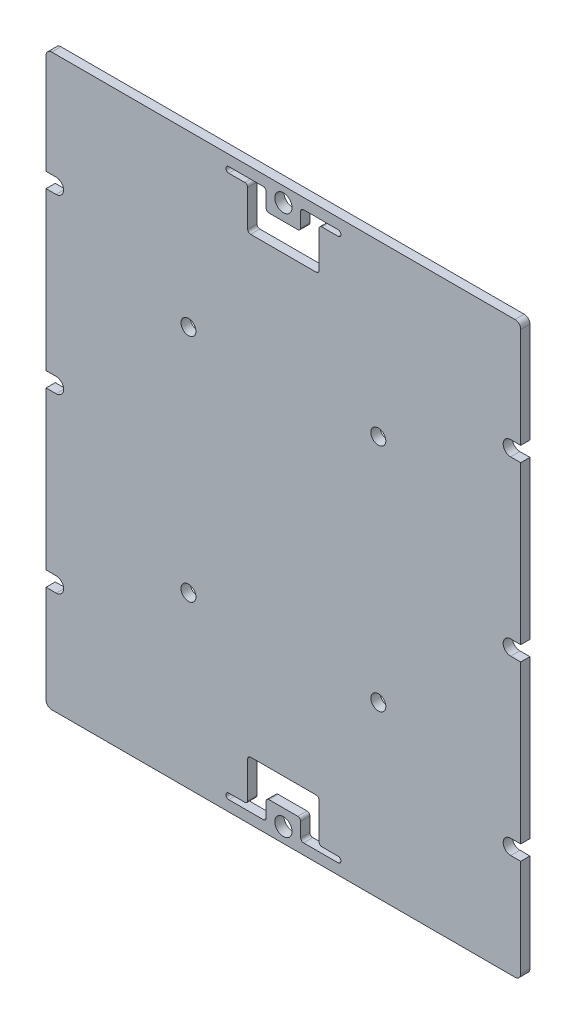
SolidWorks part; units mm, degrees
material "FR4_stuffedProtoboard"
ref_plane "Front Plane" through (0, 0, 0) normal (0, 0, 1) x (1, 0, 0)
ref_plane "Top Plane" through (0, 0, 0) normal (0, 1, 0) x (1, 0, 0)
ref_plane "Right Plane" through (0, 0, 0) normal (1, 0, 0) x (0, 0, -1)
sketch "Sketch2" plane through (0, 0, 0) normal (0, 0, 1) x (1, 0, 0)
  line L0 (39.5, 49.75) -> (-39.5, 49.75) construction
  line L1 (-41.5, 49.75) -> (41.5, 49.75) construction
  line L2 (-41.5, 49.75) -> (-41.5, -49.75) construction
  line L3 (-41.5, -49.75) -> (41.5, -49.75) construction
  line L4 (41.5, 49.75) -> (41.5, -49.75) construction
  line L5 (-41.5, 49.75) -> (41.5, -49.75) construction
  line L6 (-41.5, -49.75) -> (41.5, 49.75) construction
  line L7 (41.5, 51.75) -> (41.5, 40.35) construction
  line L8 (-41.5, 49.75) -> (41.5, 49.75) construction
  line L9 (41.5, 49.75) -> (41.5, -49.75) construction
  line L10 (-41.5, -49.75) -> (41.5, -49.75) construction
  line L11 (-41.5, 49.75) -> (-41.5, -49.75) construction
  line L12 (-37, -31.85) -> (37, -31.85) construction
  line L13 (-37, -30.25) -> (37, -30.25) construction
  line L14 (-37, -21.85) -> (37, -21.85) construction
  line L15 (-37, -20.25) -> (37, -20.25) construction
  line L16 (-37, -11.85) -> (37, -11.85) construction
  line L17 (-37, -10.25) -> (37, -10.25) construction
  line L18 (-37, -1.85) -> (37, -1.85) construction
  line L19 (-37, -0.25) -> (37, -0.25) construction
  line L20 (-37, 8.15) -> (37, 8.15) construction
  line L21 (-37, 9.75) -> (37, 9.75) construction
  line L22 (-37, 18.15) -> (37, 18.15) construction
  line L23 (-37, 19.75) -> (37, 19.75) construction
  line L24 (-37, 28.15) -> (37, 28.15) construction
  line L25 (-37, 29.75) -> (37, 29.75) construction
  line L26 (-37, 38.15) -> (37, 38.15) construction
  line L27 (-37, 39.75) -> (37, 39.75) construction
  line L28 (-37, -31.85) -> (37, -31.85) construction
  line L29 (-37, -30.25) -> (37, -30.25) construction
  line L30 (-37, -21.85) -> (37, -21.85) construction
  line L31 (-37, -20.25) -> (37, -20.25) construction
  line L32 (-37, -11.85) -> (37, -11.85) construction
  line L33 (-37, -10.25) -> (37, -10.25) construction
  line L34 (-37, -1.85) -> (37, -1.85) construction
  line L35 (-37, -0.25) -> (37, -0.25) construction
  line L36 (-37, 8.15) -> (37, 8.15) construction
  line L37 (-37, 9.75) -> (37, 9.75) construction
  line L38 (-37, 18.15) -> (37, 18.15) construction
  line L39 (-37, 19.75) -> (37, 19.75) construction
  line L40 (-37, 28.15) -> (37, 28.15) construction
  line L41 (-37, 29.75) -> (37, 29.75) construction
  line L42 (-37, 38.15) -> (37, 38.15) construction
  line L43 (-37, 39.75) -> (37, 39.75) construction
  line L44 (-37, -40.25) -> (37, -40.25) construction
  line L45 (-37, -41.85) -> (37, -41.85) construction
  line L46 (-41.5, 51.75) -> (-41.5, 40.35) construction
  line L47 (39.5, -49.75) -> (-39.5, -49.75) construction
  line L48 (41.5, -31.9) -> (41.5, -51.75) construction
  line L49 (-41.25, 49.5) -> (41.25, 49.5)
  line L50 (41.25, 49.5) -> (41.25, -49.5)
  line L51 (-41.25, -49.5) -> (41.25, -49.5)
  line L52 (-41.25, 49.5) -> (-41.25, -49.5)
  circle A0 centre (0, 46.95) radius 1.5 construction
  circle A1 centre (0, 46.95) radius 0.8 construction
  circle A2 centre (0, 46.95) radius 1.5 construction
  circle A3 centre (0, 46.95) radius 0.8
  circle A4 centre (-39.5, -30.25) radius 0.8 construction
  circle A5 centre (-39.5, -0.25) radius 0.8 construction
  circle A6 centre (-39.5, 29.75) radius 0.8 construction
  circle A7 centre (-39.5, -30.25) radius 0.8
  circle A8 centre (-39.5, -0.25) radius 0.8
  circle A9 centre (-39.5, 29.75) radius 0.8
  circle A10 centre (39.5, -30.25) radius 0.8 construction
  circle A11 centre (39.5, -0.25) radius 0.8 construction
  circle A12 centre (39.5, 29.75) radius 0.8 construction
  circle A13 centre (39.5, -30.25) radius 0.8
  circle A14 centre (39.5, -0.25) radius 0.8
  circle A15 centre (39.5, 29.75) radius 0.8
  circle A16 centre (0, -46.95) radius 0.8 construction
  circle A17 centre (0, -46.95) radius 0.8
  circle A18 centre (0, -46.95) radius 1.5 construction
  circle A19 centre (0, -46.95) radius 1.5
  circle A20 centre (-16.5, 20) radius 1.75 construction
  circle A21 centre (-16.5, 20) radius 0.8 construction
  circle A22 centre (-16.5, 20) radius 1.75 construction
  circle A23 centre (-16.5, 20) radius 0.8
  circle A24 centre (16.5, 20) radius 1.75 construction
  circle A25 centre (16.5, 20) radius 0.8 construction
  circle A26 centre (16.5, 20) radius 1.75 construction
  circle A27 centre (16.5, 20) radius 0.8
  circle A28 centre (16.5, -20) radius 1.75 construction
  circle A29 centre (-16.5, -20) radius 1.75 construction
  circle A30 centre (16.5, -20) radius 1.75 construction
  circle A31 centre (-16.5, -20) radius 1.75 construction
  circle A32 centre (-16.5, -20) radius 0.8 construction
  circle A33 centre (-16.5, -20) radius 0.8
  circle A34 centre (16.5, -20) radius 0.8 construction
  circle A35 centre (16.5, -20) radius 0.8
  point P0 (0, 0)
  point P74 (0, -40.25)
  point P75 (0, -31.85)
  point P76 (0, -41.85)
  dimension "D2" = 10
  dimension "D3" = 1.6
  dimension "D1" = 0.25
extrude "pcb extrude" add sketch "Sketch2" along normal mid plane 1.6 contours L4 L1 L2 L3 A2 | A2 A3 | L2 L1 L4 L3 region at (0, 0.0296, 0)
sketch "Debug Cutout" plane through (0, 0, 0.8) normal (0, 0, 1) x (1, 0, 0)
  line L0 (-37, -6.25) -> (-37, 5.75) construction
  line L17 (-29.5, -8.25) -> (-35, -8.25) construction
  line L18 (-35, 7.75) -> (-29.5, 7.75) construction
  line L19 (-27.5, 5.75) -> (-27.5, -6.25) construction
  line L20 (-37, -6.25) -> (-37, 5.75)
  line L21 (-29.5, -8.25) -> (-35, -8.25)
  line L22 (-35, 7.75) -> (-29.5, 7.75)
  line L23 (-27.5, 5.75) -> (-27.5, -6.25)
  arc A16 (-35, 7.75) -> (-37, 5.75) centre (-35, 5.75) ccw construction
  arc A17 (-37, -6.25) -> (-35, -8.25) centre (-35, -6.25) ccw construction
  arc A18 (-29.5, -8.25) -> (-27.5, -6.25) centre (-29.5, -6.25) ccw construction
  arc A19 (-27.5, 5.75) -> (-29.5, 7.75) centre (-29.5, 5.75) ccw construction
  arc A20 (-35, 7.75) -> (-37, 5.75) centre (-35, 5.75) ccw
  arc A21 (-37, -6.25) -> (-35, -8.25) centre (-35, -6.25) ccw
  arc A22 (-29.5, -8.25) -> (-27.5, -6.25) centre (-29.5, -6.25) ccw
  arc A23 (-27.5, 5.75) -> (-29.5, 7.75) centre (-29.5, 5.75) ccw
sketch "endcap connector" plane through (0, 0, 0.8) normal (0, 0, 1) x (1, 0, 0)
  line L0 (-10.3489, -47.209) -> (-10.3489, -49.749) construction
  line L1 (-36.1289, -47.209) -> (-10.3489, -47.209) construction
  line L2 (-36.1289, -47.209) -> (-10.3489, -47.209)
  line L3 (-36.1289, -49.749) -> (-36.1289, -47.209) construction
  line L4 (-10.3489, -47.209) -> (-10.3489, -49.749)
  line L5 (-36.1289, -49.749) -> (-36.1289, -47.209)
  point P3 (-23.2389, -47.209)
sketch "Sketch12" plane through (0, 0, 0) normal (0, 0, 1) x (1, 0, 0)
  line L0 (-40.25, -49.5) -> (40.25, -49.5)
  line L1 (-41.25, -31.55) -> (-39.5, -31.55)
  line L2 (-39.5, -28.95) -> (-41.25, -28.95)
  line L3 (-41.25, -1.55) -> (-39.5, -1.55)
  line L4 (-39.5, 1.05) -> (-41.25, 1.05)
  line L5 (-41.25, 28.45) -> (-39.5, 28.45)
  line L6 (-39.5, 31.05) -> (-41.25, 31.05)
  line L7 (-41.25, 48.5) -> (-41.25, 31.05)
  line L8 (40.25, 49.5) -> (-40.25, 49.5)
  line L9 (41.25, 31.05) -> (39.5, 31.05)
  line L10 (39.5, 28.45) -> (41.25, 28.45)
  line L11 (41.25, 1.05) -> (39.5, 1.05)
  line L12 (39.5, -1.55) -> (41.25, -1.55)
  line L13 (41.25, -28.95) -> (39.5, -28.95)
  line L14 (39.5, -31.55) -> (41.25, -31.55)
  line L15 (41.25, -48.5) -> (41.25, -31.55)
  line L16 (-41.25, -31.55) -> (-41.25, -48.5)
  line L17 (-41.25, 28.45) -> (-41.25, 1.05)
  line L18 (-41.25, -1.55) -> (-41.25, -28.95)
  line L19 (41.25, -28.95) -> (41.25, -1.55)
  line L20 (41.25, 1.05) -> (41.25, 28.45)
  line L21 (41.25, 31.05) -> (41.25, 48.5)
  line L22 (-3.5, 47.65) -> (-9.5, 47.65)
  line L23 (-9.5, 46.65) -> (-6.7, 46.65)
  line L24 (-6.2, 46.15) -> (-6.2, 39.85)
  line L25 (-5.7, 39.35) -> (5.7, 39.35)
  line L26 (6.2, 39.85) -> (6.2, 46.15)
  line L27 (6.7, 46.65) -> (9.5, 46.65)
  line L28 (9.5, 47.65) -> (3.5, 47.65)
  line L29 (3, 47.15) -> (3, 44.65)
  line L30 (2.5, 44.15) -> (-2.5, 44.15)
  line L31 (-3, 44.65) -> (-3, 47.15)
  line L32 (-3.5, -47.65) -> (-9.5, -47.65)
  line L33 (-3, -44.65) -> (-3, -47.15)
  line L34 (2.5, -44.15) -> (-2.5, -44.15)
  line L35 (3, -47.15) -> (3, -44.65)
  line L36 (9.5, -47.65) -> (3.5, -47.65)
  line L37 (6.7, -46.65) -> (9.5, -46.65)
  line L38 (6.2, -39.85) -> (6.2, -46.15)
  line L39 (-5.7, -39.35) -> (5.7, -39.35)
  line L40 (-6.2, -46.15) -> (-6.2, -39.85)
  line L41 (-9.5, -46.65) -> (-6.7, -46.65)
  line L42 (-9.91, 41.975) -> (-9.91, 41.225)
  line L43 (-9.16, 41.225) -> (-9.16, 41.975)
  line L44 (-9.91, 41.975) -> (-9.91, 41.225)
  line L45 (-9.16, 41.225) -> (-9.16, 41.975)
  line L46 (-9.16, 43.245) -> (-9.16, 43.995)
  line L47 (-9.91, 43.995) -> (-9.91, 43.245)
  line L48 (-9.16, 43.245) -> (-9.16, 43.995)
  line L49 (-9.91, 43.995) -> (-9.91, 43.245)
  line L50 (-11.18, 41.975) -> (-11.18, 41.225)
  line L51 (-10.43, 41.225) -> (-10.43, 41.975)
  line L52 (-11.18, 41.975) -> (-11.18, 41.225)
  line L53 (-10.43, 41.225) -> (-10.43, 41.975)
  line L54 (-10.43, 43.245) -> (-10.43, 43.995)
  line L55 (-11.18, 43.995) -> (-11.18, 43.245)
  line L56 (-10.43, 43.245) -> (-10.43, 43.995)
  line L57 (-11.18, 43.995) -> (-11.18, 43.245)
  line L58 (-12.45, 41.975) -> (-12.45, 41.225)
  line L59 (-11.7, 41.225) -> (-11.7, 41.975)
  line L60 (-12.45, 41.975) -> (-12.45, 41.225)
  line L61 (-11.7, 41.225) -> (-11.7, 41.975)
  line L62 (-11.7, 43.245) -> (-11.7, 43.995)
  line L63 (-12.45, 43.995) -> (-12.45, 43.245)
  line L64 (-11.7, 43.245) -> (-11.7, 43.995)
  line L65 (-12.45, 43.995) -> (-12.45, 43.245)
  line L66 (-13.72, 41.975) -> (-13.72, 41.225)
  line L67 (-12.97, 41.225) -> (-12.97, 41.975)
  line L68 (-13.72, 41.975) -> (-13.72, 41.225)
  line L69 (-12.97, 41.225) -> (-12.97, 41.975)
  line L70 (-12.97, 43.245) -> (-12.97, 43.995)
  line L71 (-13.72, 43.995) -> (-13.72, 43.245)
  line L72 (-12.97, 43.245) -> (-12.97, 43.995)
  line L73 (-13.72, 43.995) -> (-13.72, 43.245)
  line L74 (-14.99, 41.975) -> (-14.99, 41.225)
  line L75 (-14.24, 41.225) -> (-14.24, 41.975)
  line L76 (-14.99, 41.975) -> (-14.99, 41.225)
  line L77 (-14.24, 41.225) -> (-14.24, 41.975)
  line L78 (-14.24, 43.245) -> (-14.24, 43.995)
  line L79 (-14.99, 43.995) -> (-14.99, 43.245)
  line L80 (-14.24, 43.245) -> (-14.24, 43.995)
  line L81 (-14.99, 43.995) -> (-14.99, 43.245)
  line L82 (-16.26, 41.975) -> (-16.26, 41.225)
  line L83 (-15.51, 41.225) -> (-15.51, 41.975)
  line L84 (-16.26, 41.975) -> (-16.26, 41.225)
  line L85 (-15.51, 41.225) -> (-15.51, 41.975)
  line L86 (-15.51, 43.245) -> (-15.51, 43.995)
  line L87 (-16.26, 43.995) -> (-16.26, 43.245)
  line L88 (-15.51, 43.245) -> (-15.51, 43.995)
  line L89 (-16.26, 43.995) -> (-16.26, 43.245)
  line L90 (-17.53, 41.975) -> (-17.53, 41.225)
  line L91 (-16.78, 41.225) -> (-16.78, 41.975)
  line L92 (-17.53, 41.975) -> (-17.53, 41.225)
  line L93 (-16.78, 41.225) -> (-16.78, 41.975)
  line L94 (-16.78, 43.245) -> (-16.78, 43.995)
  line L95 (-17.53, 43.995) -> (-17.53, 43.245)
  line L96 (-16.78, 43.245) -> (-16.78, 43.995)
  line L97 (-17.53, 43.995) -> (-17.53, 43.245)
  line L98 (-18.8, 41.975) -> (-18.8, 41.225)
  line L99 (-18.05, 41.225) -> (-18.05, 41.975)
  line L100 (-18.8, 41.975) -> (-18.8, 41.225)
  line L101 (-18.05, 41.225) -> (-18.05, 41.975)
  line L102 (-18.05, 43.245) -> (-18.05, 43.995)
  line L103 (-18.8, 43.995) -> (-18.8, 43.245)
  line L104 (-18.05, 43.245) -> (-18.05, 43.995)
  line L105 (-18.8, 43.995) -> (-18.8, 43.245)
  line L106 (-20.07, 41.975) -> (-20.07, 41.225)
  line L107 (-19.32, 41.225) -> (-19.32, 41.975)
  line L108 (-20.07, 41.975) -> (-20.07, 41.225)
  line L109 (-19.32, 41.225) -> (-19.32, 41.975)
  line L110 (-19.32, 43.245) -> (-19.32, 43.995)
  line L111 (-20.07, 43.995) -> (-20.07, 43.245)
  line L112 (-19.32, 43.245) -> (-19.32, 43.995)
  line L113 (-20.07, 43.995) -> (-20.07, 43.245)
  line L114 (-21.34, 41.975) -> (-21.34, 41.225)
  line L115 (-20.59, 41.225) -> (-20.59, 41.975)
  line L116 (-21.34, 41.975) -> (-21.34, 41.225)
  line L117 (-20.59, 41.225) -> (-20.59, 41.975)
  line L118 (-20.59, 43.245) -> (-20.59, 43.995)
  line L119 (-21.34, 43.995) -> (-21.34, 43.245)
  line L120 (-20.59, 43.245) -> (-20.59, 43.995)
  line L121 (-21.34, 43.995) -> (-21.34, 43.245)
  line L122 (-22.61, 41.975) -> (-22.61, 41.225)
  line L123 (-21.86, 41.225) -> (-21.86, 41.975)
  line L124 (-22.61, 41.975) -> (-22.61, 41.225)
  line L125 (-21.86, 41.225) -> (-21.86, 41.975)
  line L126 (-21.86, 43.245) -> (-21.86, 43.995)
  line L127 (-22.61, 43.995) -> (-22.61, 43.245)
  line L128 (-21.86, 43.245) -> (-21.86, 43.995)
  line L129 (-22.61, 43.995) -> (-22.61, 43.245)
  line L130 (-23.88, 41.975) -> (-23.88, 41.225)
  line L131 (-23.13, 41.225) -> (-23.13, 41.975)
  line L132 (-23.88, 41.975) -> (-23.88, 41.225)
  line L133 (-23.13, 41.225) -> (-23.13, 41.975)
  line L134 (-23.13, 43.245) -> (-23.13, 43.995)
  line L135 (-23.88, 43.995) -> (-23.88, 43.245)
  line L136 (-23.13, 43.245) -> (-23.13, 43.995)
  line L137 (-23.88, 43.995) -> (-23.88, 43.245)
  line L138 (-25.15, 41.975) -> (-25.15, 41.225)
  line L139 (-24.4, 41.225) -> (-24.4, 41.975)
  line L140 (-25.15, 41.975) -> (-25.15, 41.225)
  line L141 (-24.4, 41.225) -> (-24.4, 41.975)
  line L142 (-24.4, 43.245) -> (-24.4, 43.995)
  line L143 (-25.15, 43.995) -> (-25.15, 43.245)
  line L144 (-24.4, 43.245) -> (-24.4, 43.995)
  line L145 (-25.15, 43.995) -> (-25.15, 43.245)
  line L146 (-26.42, 41.975) -> (-26.42, 41.225)
  line L147 (-25.67, 41.225) -> (-25.67, 41.975)
  line L148 (-26.42, 41.975) -> (-26.42, 41.225)
  line L149 (-25.67, 41.225) -> (-25.67, 41.975)
  line L150 (-25.67, 43.245) -> (-25.67, 43.995)
  line L151 (-26.42, 43.995) -> (-26.42, 43.245)
  line L152 (-25.67, 43.245) -> (-25.67, 43.995)
  line L153 (-26.42, 43.995) -> (-26.42, 43.245)
  line L154 (-27.69, 41.975) -> (-27.69, 41.225)
  line L155 (-26.94, 41.225) -> (-26.94, 41.975)
  line L156 (-27.69, 41.975) -> (-27.69, 41.225)
  line L157 (-26.94, 41.225) -> (-26.94, 41.975)
  line L158 (-26.94, 43.245) -> (-26.94, 43.995)
  line L159 (-27.69, 43.995) -> (-27.69, 43.245)
  line L160 (-26.94, 43.245) -> (-26.94, 43.995)
  line L161 (-27.69, 43.995) -> (-27.69, 43.245)
  line L162 (-28.96, 41.975) -> (-28.96, 41.225)
  line L163 (-28.21, 41.225) -> (-28.21, 41.975)
  line L164 (-28.96, 41.975) -> (-28.96, 41.225)
  line L165 (-28.21, 41.225) -> (-28.21, 41.975)
  line L166 (-28.21, 43.245) -> (-28.21, 43.995)
  line L167 (-28.96, 43.995) -> (-28.96, 43.245)
  line L168 (-28.21, 43.245) -> (-28.21, 43.995)
  line L169 (-28.96, 43.995) -> (-28.96, 43.245)
  line L170 (-30.23, 41.975) -> (-30.23, 41.225)
  line L171 (-29.48, 41.225) -> (-29.48, 41.975)
  line L172 (-30.23, 41.975) -> (-30.23, 41.225)
  line L173 (-29.48, 41.225) -> (-29.48, 41.975)
  line L174 (-29.48, 43.245) -> (-29.48, 43.995)
  line L175 (-30.23, 43.995) -> (-30.23, 43.245)
  line L176 (-29.48, 43.245) -> (-29.48, 43.995)
  line L177 (-30.23, 43.995) -> (-30.23, 43.245)
  line L178 (-31.5, 41.975) -> (-31.5, 41.225)
  line L179 (-30.75, 41.225) -> (-30.75, 41.975)
  line L180 (-31.5, 41.975) -> (-31.5, 41.225)
  line L181 (-30.75, 41.225) -> (-30.75, 41.975)
  line L182 (-30.75, 43.245) -> (-30.75, 43.995)
  line L183 (-31.5, 43.995) -> (-31.5, 43.245)
  line L184 (-30.75, 43.245) -> (-30.75, 43.995)
  line L185 (-31.5, 43.995) -> (-31.5, 43.245)
  line L186 (-32.77, 41.975) -> (-32.77, 41.225)
  line L187 (-32.02, 41.225) -> (-32.02, 41.975)
  line L188 (-32.77, 41.975) -> (-32.77, 41.225)
  line L189 (-32.02, 41.225) -> (-32.02, 41.975)
  line L190 (-32.02, 43.245) -> (-32.02, 43.995)
  line L191 (-32.77, 43.995) -> (-32.77, 43.245)
  line L192 (-32.02, 43.245) -> (-32.02, 43.995)
  line L193 (-32.77, 43.995) -> (-32.77, 43.245)
  line L194 (-34.04, 41.975) -> (-34.04, 41.225)
  line L195 (-33.29, 41.225) -> (-33.29, 41.975)
  line L196 (-34.04, 41.975) -> (-34.04, 41.225)
  line L197 (-33.29, 41.225) -> (-33.29, 41.975)
  line L198 (-33.29, 43.245) -> (-33.29, 43.995)
  line L199 (-34.04, 43.995) -> (-34.04, 43.245)
  line L200 (-33.29, 43.245) -> (-33.29, 43.995)
  line L201 (-34.04, 43.995) -> (-34.04, 43.245)
  line L202 (-22.66, 31.975) -> (-22.66, 31.225)
  line L203 (-21.91, 31.225) -> (-21.91, 31.975)
  line L204 (-22.66, 31.975) -> (-22.66, 31.225)
  line L205 (-21.91, 31.225) -> (-21.91, 31.975)
  line L206 (-21.91, 33.245) -> (-21.91, 33.995)
  line L207 (-22.66, 33.995) -> (-22.66, 33.245)
  line L208 (-21.91, 33.245) -> (-21.91, 33.995)
  line L209 (-22.66, 33.995) -> (-22.66, 33.245)
  line L210 (-23.93, 31.975) -> (-23.93, 31.225)
  line L211 (-23.18, 31.225) -> (-23.18, 31.975)
  line L212 (-23.93, 31.975) -> (-23.93, 31.225)
  line L213 (-23.18, 31.225) -> (-23.18, 31.975)
  line L214 (-23.18, 33.245) -> (-23.18, 33.995)
  line L215 (-23.93, 33.995) -> (-23.93, 33.245)
  line L216 (-23.18, 33.245) -> (-23.18, 33.995)
  line L217 (-23.93, 33.995) -> (-23.93, 33.245)
  line L218 (-25.2, 31.975) -> (-25.2, 31.225)
  line L219 (-24.45, 31.225) -> (-24.45, 31.975)
  line L220 (-25.2, 31.975) -> (-25.2, 31.225)
  line L221 (-24.45, 31.225) -> (-24.45, 31.975)
  line L222 (-24.45, 33.245) -> (-24.45, 33.995)
  line L223 (-25.2, 33.995) -> (-25.2, 33.245)
  line L224 (-24.45, 33.245) -> (-24.45, 33.995)
  line L225 (-25.2, 33.995) -> (-25.2, 33.245)
  line L226 (-26.47, 31.975) -> (-26.47, 31.225)
  line L227 (-25.72, 31.225) -> (-25.72, 31.975)
  line L228 (-26.47, 31.975) -> (-26.47, 31.225)
  line L229 (-25.72, 31.225) -> (-25.72, 31.975)
  line L230 (-25.72, 33.245) -> (-25.72, 33.995)
  line L231 (-26.47, 33.995) -> (-26.47, 33.245)
  line L232 (-25.72, 33.245) -> (-25.72, 33.995)
  line L233 (-26.47, 33.995) -> (-26.47, 33.245)
  line L234 (-27.74, 31.975) -> (-27.74, 31.225)
  line L235 (-26.99, 31.225) -> (-26.99, 31.975)
  line L236 (-27.74, 31.975) -> (-27.74, 31.225)
  line L237 (-26.99, 31.225) -> (-26.99, 31.975)
  line L238 (-26.99, 33.245) -> (-26.99, 33.995)
  line L239 (-27.74, 33.995) -> (-27.74, 33.245)
  line L240 (-26.99, 33.245) -> (-26.99, 33.995)
  line L241 (-27.74, 33.995) -> (-27.74, 33.245)
  line L242 (-29.01, 31.975) -> (-29.01, 31.225)
  line L243 (-28.26, 31.225) -> (-28.26, 31.975)
  line L244 (-29.01, 31.975) -> (-29.01, 31.225)
  line L245 (-28.26, 31.225) -> (-28.26, 31.975)
  line L246 (-28.26, 33.245) -> (-28.26, 33.995)
  line L247 (-29.01, 33.995) -> (-29.01, 33.245)
  line L248 (-28.26, 33.245) -> (-28.26, 33.995)
  line L249 (-29.01, 33.995) -> (-29.01, 33.245)
  line L250 (-30.28, 31.975) -> (-30.28, 31.225)
  line L251 (-29.53, 31.225) -> (-29.53, 31.975)
  line L252 (-30.28, 31.975) -> (-30.28, 31.225)
  line L253 (-29.53, 31.225) -> (-29.53, 31.975)
  line L254 (-29.53, 33.245) -> (-29.53, 33.995)
  line L255 (-30.28, 33.995) -> (-30.28, 33.245)
  line L256 (-29.53, 33.245) -> (-29.53, 33.995)
  line L257 (-30.28, 33.995) -> (-30.28, 33.245)
  line L258 (-31.55, 31.975) -> (-31.55, 31.225)
  line L259 (-30.8, 31.225) -> (-30.8, 31.975)
  line L260 (-31.55, 31.975) -> (-31.55, 31.225)
  line L261 (-30.8, 31.225) -> (-30.8, 31.975)
  line L262 (-30.8, 33.245) -> (-30.8, 33.995)
  line L263 (-31.55, 33.995) -> (-31.55, 33.245)
  line L264 (-30.8, 33.245) -> (-30.8, 33.995)
  line L265 (-31.55, 33.995) -> (-31.55, 33.245)
  line L266 (-32.82, 31.975) -> (-32.82, 31.225)
  line L267 (-32.07, 31.225) -> (-32.07, 31.975)
  line L268 (-32.82, 31.975) -> (-32.82, 31.225)
  line L269 (-32.07, 31.225) -> (-32.07, 31.975)
  line L270 (-32.07, 33.245) -> (-32.07, 33.995)
  line L271 (-32.82, 33.995) -> (-32.82, 33.245)
  line L272 (-32.07, 33.245) -> (-32.07, 33.995)
  line L273 (-32.82, 33.995) -> (-32.82, 33.245)
  line L274 (-34.09, 31.975) -> (-34.09, 31.225)
  line L275 (-33.34, 31.225) -> (-33.34, 31.975)
  line L276 (-34.09, 31.975) -> (-34.09, 31.225)
  line L277 (-33.34, 31.225) -> (-33.34, 31.975)
  line L278 (-33.34, 33.245) -> (-33.34, 33.995)
  line L279 (-34.09, 33.995) -> (-34.09, 33.245)
  line L280 (-33.34, 33.245) -> (-33.34, 33.995)
  line L281 (-34.09, 33.995) -> (-34.09, 33.245)
  line L282 (11.69, 31.975) -> (11.69, 31.225)
  line L283 (12.44, 31.225) -> (12.44, 31.975)
  line L284 (11.69, 31.975) -> (11.69, 31.225)
  line L285 (12.44, 31.225) -> (12.44, 31.975)
  line L286 (12.44, 33.245) -> (12.44, 33.995)
  line L287 (11.69, 33.995) -> (11.69, 33.245)
  line L288 (12.44, 33.245) -> (12.44, 33.995)
  line L289 (11.69, 33.995) -> (11.69, 33.245)
  line L290 (10.42, 31.975) -> (10.42, 31.225)
  line L291 (11.17, 31.225) -> (11.17, 31.975)
  line L292 (10.42, 31.975) -> (10.42, 31.225)
  line L293 (11.17, 31.225) -> (11.17, 31.975)
  line L294 (11.17, 33.245) -> (11.17, 33.995)
  line L295 (10.42, 33.995) -> (10.42, 33.245)
  line L296 (11.17, 33.245) -> (11.17, 33.995)
  line L297 (10.42, 33.995) -> (10.42, 33.245)
  line L298 (9.15, 31.975) -> (9.15, 31.225)
  line L299 (9.9, 31.225) -> (9.9, 31.975)
  line L300 (9.15, 31.975) -> (9.15, 31.225)
  line L301 (9.9, 31.225) -> (9.9, 31.975)
  line L302 (9.9, 33.245) -> (9.9, 33.995)
  line L303 (9.15, 33.995) -> (9.15, 33.245)
  line L304 (9.9, 33.245) -> (9.9, 33.995)
  line L305 (9.15, 33.995) -> (9.15, 33.245)
  line L306 (7.88, 31.975) -> (7.88, 31.225)
  line L307 (8.63, 31.225) -> (8.63, 31.975)
  line L308 (7.88, 31.975) -> (7.88, 31.225)
  line L309 (8.63, 31.225) -> (8.63, 31.975)
  line L310 (8.63, 33.245) -> (8.63, 33.995)
  line L311 (7.88, 33.995) -> (7.88, 33.245)
  line L312 (8.63, 33.245) -> (8.63, 33.995)
  line L313 (7.88, 33.995) -> (7.88, 33.245)
  line L314 (6.61, 31.975) -> (6.61, 31.225)
  line L315 (7.36, 31.225) -> (7.36, 31.975)
  line L316 (6.61, 31.975) -> (6.61, 31.225)
  line L317 (7.36, 31.225) -> (7.36, 31.975)
  line L318 (7.36, 33.245) -> (7.36, 33.995)
  line L319 (6.61, 33.995) -> (6.61, 33.245)
  line L320 (7.36, 33.245) -> (7.36, 33.995)
  line L321 (6.61, 33.995) -> (6.61, 33.245)
  line L322 (5.34, 31.975) -> (5.34, 31.225)
  line L323 (6.09, 31.225) -> (6.09, 31.975)
  line L324 (5.34, 31.975) -> (5.34, 31.225)
  line L325 (6.09, 31.225) -> (6.09, 31.975)
  line L326 (6.09, 33.245) -> (6.09, 33.995)
  line L327 (5.34, 33.995) -> (5.34, 33.245)
  line L328 (6.09, 33.245) -> (6.09, 33.995)
  line L329 (5.34, 33.995) -> (5.34, 33.245)
  line L330 (4.07, 31.975) -> (4.07, 31.225)
  line L331 (4.82, 31.225) -> (4.82, 31.975)
  line L332 (4.07, 31.975) -> (4.07, 31.225)
  line L333 (4.82, 31.225) -> (4.82, 31.975)
  line L334 (4.82, 33.245) -> (4.82, 33.995)
  line L335 (4.07, 33.995) -> (4.07, 33.245)
  line L336 (4.82, 33.245) -> (4.82, 33.995)
  line L337 (4.07, 33.995) -> (4.07, 33.245)
  line L338 (2.8, 31.975) -> (2.8, 31.225)
  line L339 (3.55, 31.225) -> (3.55, 31.975)
  line L340 (2.8, 31.975) -> (2.8, 31.225)
  line L341 (3.55, 31.225) -> (3.55, 31.975)
  line L342 (3.55, 33.245) -> (3.55, 33.995)
  line L343 (2.8, 33.995) -> (2.8, 33.245)
  line L344 (3.55, 33.245) -> (3.55, 33.995)
  line L345 (2.8, 33.995) -> (2.8, 33.245)
  line L346 (1.53, 31.975) -> (1.53, 31.225)
  line L347 (2.28, 31.225) -> (2.28, 31.975)
  line L348 (1.53, 31.975) -> (1.53, 31.225)
  line L349 (2.28, 31.225) -> (2.28, 31.975)
  line L350 (2.28, 33.245) -> (2.28, 33.995)
  line L351 (1.53, 33.995) -> (1.53, 33.245)
  line L352 (2.28, 33.245) -> (2.28, 33.995)
  line L353 (1.53, 33.995) -> (1.53, 33.245)
  line L354 (0.26, 31.975) -> (0.26, 31.225)
  line L355 (1.01, 31.225) -> (1.01, 31.975)
  line L356 (0.26, 31.975) -> (0.26, 31.225)
  line L357 (1.01, 31.225) -> (1.01, 31.975)
  line L358 (1.01, 33.245) -> (1.01, 33.995)
  line L359 (0.26, 33.995) -> (0.26, 33.245)
  line L360 (1.01, 33.245) -> (1.01, 33.995)
  line L361 (0.26, 33.995) -> (0.26, 33.245)
  line L362 (-1.01, 31.975) -> (-1.01, 31.225)
  line L363 (-0.26, 31.225) -> (-0.26, 31.975)
  line L364 (-1.01, 31.975) -> (-1.01, 31.225)
  line L365 (-0.26, 31.225) -> (-0.26, 31.975)
  line L366 (-0.26, 33.245) -> (-0.26, 33.995)
  line L367 (-1.01, 33.995) -> (-1.01, 33.245)
  line L368 (-0.26, 33.245) -> (-0.26, 33.995)
  line L369 (-1.01, 33.995) -> (-1.01, 33.245)
  line L370 (-2.28, 31.975) -> (-2.28, 31.225)
  line L371 (-1.53, 31.225) -> (-1.53, 31.975)
  line L372 (-2.28, 31.975) -> (-2.28, 31.225)
  line L373 (-1.53, 31.225) -> (-1.53, 31.975)
  line L374 (-1.53, 33.245) -> (-1.53, 33.995)
  line L375 (-2.28, 33.995) -> (-2.28, 33.245)
  line L376 (-1.53, 33.245) -> (-1.53, 33.995)
  line L377 (-2.28, 33.995) -> (-2.28, 33.245)
  line L378 (-3.55, 31.975) -> (-3.55, 31.225)
  line L379 (-2.8, 31.225) -> (-2.8, 31.975)
  line L380 (-3.55, 31.975) -> (-3.55, 31.225)
  line L381 (-2.8, 31.225) -> (-2.8, 31.975)
  line L382 (-2.8, 33.245) -> (-2.8, 33.995)
  line L383 (-3.55, 33.995) -> (-3.55, 33.245)
  line L384 (-2.8, 33.245) -> (-2.8, 33.995)
  line L385 (-3.55, 33.995) -> (-3.55, 33.245)
  line L386 (-4.82, 31.975) -> (-4.82, 31.225)
  line L387 (-4.07, 31.225) -> (-4.07, 31.975)
  line L388 (-4.82, 31.975) -> (-4.82, 31.225)
  line L389 (-4.07, 31.225) -> (-4.07, 31.975)
  line L390 (-4.07, 33.245) -> (-4.07, 33.995)
  line L391 (-4.82, 33.995) -> (-4.82, 33.245)
  line L392 (-4.07, 33.245) -> (-4.07, 33.995)
  line L393 (-4.82, 33.995) -> (-4.82, 33.245)
  line L394 (-6.09, 31.975) -> (-6.09, 31.225)
  line L395 (-5.34, 31.225) -> (-5.34, 31.975)
  line L396 (-6.09, 31.975) -> (-6.09, 31.225)
  line L397 (-5.34, 31.225) -> (-5.34, 31.975)
  line L398 (-5.34, 33.245) -> (-5.34, 33.995)
  line L399 (-6.09, 33.995) -> (-6.09, 33.245)
  line L400 (-5.34, 33.245) -> (-5.34, 33.995)
  line L401 (-6.09, 33.995) -> (-6.09, 33.245)
  line L402 (-7.36, 31.975) -> (-7.36, 31.225)
  line L403 (-6.61, 31.225) -> (-6.61, 31.975)
  line L404 (-7.36, 31.975) -> (-7.36, 31.225)
  line L405 (-6.61, 31.225) -> (-6.61, 31.975)
  line L406 (-6.61, 33.245) -> (-6.61, 33.995)
  line L407 (-7.36, 33.995) -> (-7.36, 33.245)
  line L408 (-6.61, 33.245) -> (-6.61, 33.995)
  line L409 (-7.36, 33.995) -> (-7.36, 33.245)
  line L410 (-8.63, 31.975) -> (-8.63, 31.225)
  line L411 (-7.88, 31.225) -> (-7.88, 31.975)
  line L412 (-8.63, 31.975) -> (-8.63, 31.225)
  line L413 (-7.88, 31.225) -> (-7.88, 31.975)
  line L414 (-7.88, 33.245) -> (-7.88, 33.995)
  line L415 (-8.63, 33.995) -> (-8.63, 33.245)
  line L416 (-7.88, 33.245) -> (-7.88, 33.995)
  line L417 (-8.63, 33.995) -> (-8.63, 33.245)
  line L418 (-9.9, 31.975) -> (-9.9, 31.225)
  line L419 (-9.15, 31.225) -> (-9.15, 31.975)
  line L420 (-9.9, 31.975) -> (-9.9, 31.225)
  line L421 (-9.15, 31.225) -> (-9.15, 31.975)
  line L422 (-9.15, 33.245) -> (-9.15, 33.995)
  line L423 (-9.9, 33.995) -> (-9.9, 33.245)
  line L424 (-9.15, 33.245) -> (-9.15, 33.995)
  line L425 (-9.9, 33.995) -> (-9.9, 33.245)
  line L426 (-11.17, 31.975) -> (-11.17, 31.225)
  line L427 (-10.42, 31.225) -> (-10.42, 31.975)
  line L428 (-11.17, 31.975) -> (-11.17, 31.225)
  line L429 (-10.42, 31.225) -> (-10.42, 31.975)
  line L430 (-10.42, 33.245) -> (-10.42, 33.995)
  line L431 (-11.17, 33.995) -> (-11.17, 33.245)
  line L432 (-10.42, 33.245) -> (-10.42, 33.995)
  line L433 (-11.17, 33.995) -> (-11.17, 33.245)
  line L434 (-12.44, 31.975) -> (-12.44, 31.225)
  line L435 (-11.69, 31.225) -> (-11.69, 31.975)
  line L436 (-12.44, 31.975) -> (-12.44, 31.225)
  line L437 (-11.69, 31.225) -> (-11.69, 31.975)
  line L438 (-11.69, 33.245) -> (-11.69, 33.995)
  line L439 (-12.44, 33.995) -> (-12.44, 33.245)
  line L440 (-11.69, 33.245) -> (-11.69, 33.995)
  line L441 (-12.44, 33.995) -> (-12.44, 33.245)
  line L442 (-22.66, 21.975) -> (-22.66, 21.225)
  line L443 (-21.91, 21.225) -> (-21.91, 21.975)
  line L444 (-22.66, 21.975) -> (-22.66, 21.225)
  line L445 (-21.91, 21.225) -> (-21.91, 21.975)
  line L446 (-21.91, 23.245) -> (-21.91, 23.995)
  line L447 (-22.66, 23.995) -> (-22.66, 23.245)
  line L448 (-21.91, 23.245) -> (-21.91, 23.995)
  line L449 (-22.66, 23.995) -> (-22.66, 23.245)
  line L450 (-23.93, 21.975) -> (-23.93, 21.225)
  line L451 (-23.18, 21.225) -> (-23.18, 21.975)
  line L452 (-23.93, 21.975) -> (-23.93, 21.225)
  line L453 (-23.18, 21.225) -> (-23.18, 21.975)
  line L454 (-23.18, 23.245) -> (-23.18, 23.995)
  line L455 (-23.93, 23.995) -> (-23.93, 23.245)
  line L456 (-23.18, 23.245) -> (-23.18, 23.995)
  line L457 (-23.93, 23.995) -> (-23.93, 23.245)
  line L458 (-25.2, 21.975) -> (-25.2, 21.225)
  line L459 (-24.45, 21.225) -> (-24.45, 21.975)
  line L460 (-25.2, 21.975) -> (-25.2, 21.225)
  line L461 (-24.45, 21.225) -> (-24.45, 21.975)
  line L462 (-24.45, 23.245) -> (-24.45, 23.995)
  line L463 (-25.2, 23.995) -> (-25.2, 23.245)
  line L464 (-24.45, 23.245) -> (-24.45, 23.995)
  line L465 (-25.2, 23.995) -> (-25.2, 23.245)
  line L466 (-26.47, 21.975) -> (-26.47, 21.225)
  line L467 (-25.72, 21.225) -> (-25.72, 21.975)
  line L468 (-26.47, 21.975) -> (-26.47, 21.225)
  line L469 (-25.72, 21.225) -> (-25.72, 21.975)
  line L470 (-25.72, 23.245) -> (-25.72, 23.995)
  line L471 (-26.47, 23.995) -> (-26.47, 23.245)
  line L472 (-25.72, 23.245) -> (-25.72, 23.995)
  line L473 (-26.47, 23.995) -> (-26.47, 23.245)
  line L474 (-27.74, 21.975) -> (-27.74, 21.225)
  line L475 (-26.99, 21.225) -> (-26.99, 21.975)
  line L476 (-27.74, 21.975) -> (-27.74, 21.225)
  line L477 (-26.99, 21.225) -> (-26.99, 21.975)
  line L478 (-26.99, 23.245) -> (-26.99, 23.995)
  line L479 (-27.74, 23.995) -> (-27.74, 23.245)
  line L480 (-26.99, 23.245) -> (-26.99, 23.995)
  line L481 (-27.74, 23.995) -> (-27.74, 23.245)
  line L482 (-29.01, 21.975) -> (-29.01, 21.225)
  line L483 (-28.26, 21.225) -> (-28.26, 21.975)
  line L484 (-29.01, 21.975) -> (-29.01, 21.225)
  line L485 (-28.26, 21.225) -> (-28.26, 21.975)
  line L486 (-28.26, 23.245) -> (-28.26, 23.995)
  line L487 (-29.01, 23.995) -> (-29.01, 23.245)
  line L488 (-28.26, 23.245) -> (-28.26, 23.995)
  line L489 (-29.01, 23.995) -> (-29.01, 23.245)
  line L490 (-30.28, 21.975) -> (-30.28, 21.225)
  line L491 (-29.53, 21.225) -> (-29.53, 21.975)
  line L492 (-30.28, 21.975) -> (-30.28, 21.225)
  line L493 (-29.53, 21.225) -> (-29.53, 21.975)
  line L494 (-29.53, 23.245) -> (-29.53, 23.995)
  line L495 (-30.28, 23.995) -> (-30.28, 23.245)
  line L496 (-29.53, 23.245) -> (-29.53, 23.995)
  line L497 (-30.28, 23.995) -> (-30.28, 23.245)
  line L498 (-31.55, 21.975) -> (-31.55, 21.225)
  line L499 (-30.8, 21.225) -> (-30.8, 21.975)
  line L500 (-31.55, 21.975) -> (-31.55, 21.225)
  line L501 (-30.8, 21.225) -> (-30.8, 21.975)
  line L502 (-30.8, 23.245) -> (-30.8, 23.995)
  line L503 (-31.55, 23.995) -> (-31.55, 23.245)
  line L504 (-30.8, 23.245) -> (-30.8, 23.995)
  line L505 (-31.55, 23.995) -> (-31.55, 23.245)
  line L506 (-32.82, 21.975) -> (-32.82, 21.225)
  line L507 (-32.07, 21.225) -> (-32.07, 21.975)
  line L508 (-32.82, 21.975) -> (-32.82, 21.225)
  line L509 (-32.07, 21.225) -> (-32.07, 21.975)
  line L510 (-32.07, 23.245) -> (-32.07, 23.995)
  line L511 (-32.82, 23.995) -> (-32.82, 23.245)
  line L512 (-32.07, 23.245) -> (-32.07, 23.995)
  line L513 (-32.82, 23.995) -> (-32.82, 23.245)
  line L514 (-34.09, 21.975) -> (-34.09, 21.225)
  line L515 (-33.34, 21.225) -> (-33.34, 21.975)
  line L516 (-34.09, 21.975) -> (-34.09, 21.225)
  line L517 (-33.34, 21.225) -> (-33.34, 21.975)
  line L518 (-33.34, 23.245) -> (-33.34, 23.995)
  line L519 (-34.09, 23.995) -> (-34.09, 23.245)
  line L520 (-33.34, 23.245) -> (-33.34, 23.995)
  line L521 (-34.09, 23.995) -> (-34.09, 23.245)
  line L522 (11.69, 21.975) -> (11.69, 21.225)
  line L523 (12.44, 21.225) -> (12.44, 21.975)
  line L524 (11.69, 21.975) -> (11.69, 21.225)
  line L525 (12.44, 21.225) -> (12.44, 21.975)
  line L526 (12.44, 23.245) -> (12.44, 23.995)
  line L527 (11.69, 23.995) -> (11.69, 23.245)
  line L528 (12.44, 23.245) -> (12.44, 23.995)
  line L529 (11.69, 23.995) -> (11.69, 23.245)
  line L530 (10.42, 21.975) -> (10.42, 21.225)
  line L531 (11.17, 21.225) -> (11.17, 21.975)
  line L532 (10.42, 21.975) -> (10.42, 21.225)
  line L533 (11.17, 21.225) -> (11.17, 21.975)
  line L534 (11.17, 23.245) -> (11.17, 23.995)
  line L535 (10.42, 23.995) -> (10.42, 23.245)
  line L536 (11.17, 23.245) -> (11.17, 23.995)
  line L537 (10.42, 23.995) -> (10.42, 23.245)
  line L538 (9.15, 21.975) -> (9.15, 21.225)
  line L539 (9.9, 21.225) -> (9.9, 21.975)
  line L540 (9.15, 21.975) -> (9.15, 21.225)
  line L541 (9.9, 21.225) -> (9.9, 21.975)
  line L542 (9.9, 23.245) -> (9.9, 23.995)
  line L543 (9.15, 23.995) -> (9.15, 23.245)
  line L544 (9.9, 23.245) -> (9.9, 23.995)
  line L545 (9.15, 23.995) -> (9.15, 23.245)
  line L546 (7.88, 21.975) -> (7.88, 21.225)
  line L547 (8.63, 21.225) -> (8.63, 21.975)
  line L548 (7.88, 21.975) -> (7.88, 21.225)
  line L549 (8.63, 21.225) -> (8.63, 21.975)
  line L550 (8.63, 23.245) -> (8.63, 23.995)
  line L551 (7.88, 23.995) -> (7.88, 23.245)
  line L552 (8.63, 23.245) -> (8.63, 23.995)
  line L553 (7.88, 23.995) -> (7.88, 23.245)
  line L554 (6.61, 21.975) -> (6.61, 21.225)
  line L555 (7.36, 21.225) -> (7.36, 21.975)
  line L556 (6.61, 21.975) -> (6.61, 21.225)
  line L557 (7.36, 21.225) -> (7.36, 21.975)
  line L558 (7.36, 23.245) -> (7.36, 23.995)
  line L559 (6.61, 23.995) -> (6.61, 23.245)
  line L560 (7.36, 23.245) -> (7.36, 23.995)
  line L561 (6.61, 23.995) -> (6.61, 23.245)
  line L562 (5.34, 21.975) -> (5.34, 21.225)
  line L563 (6.09, 21.225) -> (6.09, 21.975)
  line L564 (5.34, 21.975) -> (5.34, 21.225)
  line L565 (6.09, 21.225) -> (6.09, 21.975)
  line L566 (6.09, 23.245) -> (6.09, 23.995)
  line L567 (5.34, 23.995) -> (5.34, 23.245)
  line L568 (6.09, 23.245) -> (6.09, 23.995)
  line L569 (5.34, 23.995) -> (5.34, 23.245)
  line L570 (4.07, 21.975) -> (4.07, 21.225)
  line L571 (4.82, 21.225) -> (4.82, 21.975)
  line L572 (4.07, 21.975) -> (4.07, 21.225)
  line L573 (4.82, 21.225) -> (4.82, 21.975)
  line L574 (4.82, 23.245) -> (4.82, 23.995)
  line L575 (4.07, 23.995) -> (4.07, 23.245)
  line L576 (4.82, 23.245) -> (4.82, 23.995)
  line L577 (4.07, 23.995) -> (4.07, 23.245)
  line L578 (2.8, 21.975) -> (2.8, 21.225)
  line L579 (3.55, 21.225) -> (3.55, 21.975)
  line L580 (2.8, 21.975) -> (2.8, 21.225)
  line L581 (3.55, 21.225) -> (3.55, 21.975)
  line L582 (3.55, 23.245) -> (3.55, 23.995)
  line L583 (2.8, 23.995) -> (2.8, 23.245)
  line L584 (3.55, 23.245) -> (3.55, 23.995)
  line L585 (2.8, 23.995) -> (2.8, 23.245)
  line L586 (1.53, 21.975) -> (1.53, 21.225)
  line L587 (2.28, 21.225) -> (2.28, 21.975)
  line L588 (1.53, 21.975) -> (1.53, 21.225)
  line L589 (2.28, 21.225) -> (2.28, 21.975)
  line L590 (2.28, 23.245) -> (2.28, 23.995)
  line L591 (1.53, 23.995) -> (1.53, 23.245)
  line L592 (2.28, 23.245) -> (2.28, 23.995)
  line L593 (1.53, 23.995) -> (1.53, 23.245)
  line L594 (0.26, 21.975) -> (0.26, 21.225)
  line L595 (1.01, 21.225) -> (1.01, 21.975)
  line L596 (0.26, 21.975) -> (0.26, 21.225)
  line L597 (1.01, 21.225) -> (1.01, 21.975)
  line L598 (1.01, 23.245) -> (1.01, 23.995)
  line L599 (0.26, 23.995) -> (0.26, 23.245)
  line L600 (1.01, 23.245) -> (1.01, 23.995)
  line L601 (0.26, 23.995) -> (0.26, 23.245)
  line L602 (-1.01, 21.975) -> (-1.01, 21.225)
  line L603 (-0.26, 21.225) -> (-0.26, 21.975)
  line L604 (-1.01, 21.975) -> (-1.01, 21.225)
  line L605 (-0.26, 21.225) -> (-0.26, 21.975)
  line L606 (-0.26, 23.245) -> (-0.26, 23.995)
  line L607 (-1.01, 23.995) -> (-1.01, 23.245)
  line L608 (-0.26, 23.245) -> (-0.26, 23.995)
  line L609 (-1.01, 23.995) -> (-1.01, 23.245)
  line L610 (-2.28, 21.975) -> (-2.28, 21.225)
  line L611 (-1.53, 21.225) -> (-1.53, 21.975)
  line L612 (-2.28, 21.975) -> (-2.28, 21.225)
  line L613 (-1.53, 21.225) -> (-1.53, 21.975)
  line L614 (-1.53, 23.245) -> (-1.53, 23.995)
  line L615 (-2.28, 23.995) -> (-2.28, 23.245)
  line L616 (-1.53, 23.245) -> (-1.53, 23.995)
  line L617 (-2.28, 23.995) -> (-2.28, 23.245)
  line L618 (-3.55, 21.975) -> (-3.55, 21.225)
  line L619 (-2.8, 21.225) -> (-2.8, 21.975)
  line L620 (-3.55, 21.975) -> (-3.55, 21.225)
  line L621 (-2.8, 21.225) -> (-2.8, 21.975)
  line L622 (-2.8, 23.245) -> (-2.8, 23.995)
  line L623 (-3.55, 23.995) -> (-3.55, 23.245)
  line L624 (-2.8, 23.245) -> (-2.8, 23.995)
  line L625 (-3.55, 23.995) -> (-3.55, 23.245)
  line L626 (-4.82, 21.975) -> (-4.82, 21.225)
  line L627 (-4.07, 21.225) -> (-4.07, 21.975)
  line L628 (-4.82, 21.975) -> (-4.82, 21.225)
  line L629 (-4.07, 21.225) -> (-4.07, 21.975)
  line L630 (-4.07, 23.245) -> (-4.07, 23.995)
  line L631 (-4.82, 23.995) -> (-4.82, 23.245)
  line L632 (-4.07, 23.245) -> (-4.07, 23.995)
  line L633 (-4.82, 23.995) -> (-4.82, 23.245)
  line L634 (-6.09, 21.975) -> (-6.09, 21.225)
  line L635 (-5.34, 21.225) -> (-5.34, 21.975)
  line L636 (-6.09, 21.975) -> (-6.09, 21.225)
  line L637 (-5.34, 21.225) -> (-5.34, 21.975)
  line L638 (-5.34, 23.245) -> (-5.34, 23.995)
  line L639 (-6.09, 23.995) -> (-6.09, 23.245)
  line L640 (-5.34, 23.245) -> (-5.34, 23.995)
  line L641 (-6.09, 23.995) -> (-6.09, 23.245)
  line L642 (-7.36, 21.975) -> (-7.36, 21.225)
  line L643 (-6.61, 21.225) -> (-6.61, 21.975)
  line L644 (-7.36, 21.975) -> (-7.36, 21.225)
  line L645 (-6.61, 21.225) -> (-6.61, 21.975)
  line L646 (-6.61, 23.245) -> (-6.61, 23.995)
  line L647 (-7.36, 23.995) -> (-7.36, 23.245)
  line L648 (-6.61, 23.245) -> (-6.61, 23.995)
  line L649 (-7.36, 23.995) -> (-7.36, 23.245)
  line L650 (-8.63, 21.975) -> (-8.63, 21.225)
  line L651 (-7.88, 21.225) -> (-7.88, 21.975)
  line L652 (-8.63, 21.975) -> (-8.63, 21.225)
  line L653 (-7.88, 21.225) -> (-7.88, 21.975)
  line L654 (-7.88, 23.245) -> (-7.88, 23.995)
  line L655 (-8.63, 23.995) -> (-8.63, 23.245)
  line L656 (-7.88, 23.245) -> (-7.88, 23.995)
  line L657 (-8.63, 23.995) -> (-8.63, 23.245)
  line L658 (-9.9, 21.975) -> (-9.9, 21.225)
  line L659 (-9.15, 21.225) -> (-9.15, 21.975)
  line L660 (-9.9, 21.975) -> (-9.9, 21.225)
  line L661 (-9.15, 21.225) -> (-9.15, 21.975)
  line L662 (-9.15, 23.245) -> (-9.15, 23.995)
  line L663 (-9.9, 23.995) -> (-9.9, 23.245)
  line L664 (-9.15, 23.245) -> (-9.15, 23.995)
  line L665 (-9.9, 23.995) -> (-9.9, 23.245)
  line L666 (-11.17, 21.975) -> (-11.17, 21.225)
  line L667 (-10.42, 21.225) -> (-10.42, 21.975)
  line L668 (-11.17, 21.975) -> (-11.17, 21.225)
  line L669 (-10.42, 21.225) -> (-10.42, 21.975)
  line L670 (-10.42, 23.245) -> (-10.42, 23.995)
  line L671 (-11.17, 23.995) -> (-11.17, 23.245)
  line L672 (-10.42, 23.245) -> (-10.42, 23.995)
  line L673 (-11.17, 23.995) -> (-11.17, 23.245)
  line L674 (-12.44, 21.975) -> (-12.44, 21.225)
  line L675 (-11.69, 21.225) -> (-11.69, 21.975)
  line L676 (-12.44, 21.975) -> (-12.44, 21.225)
  line L677 (-11.69, 21.225) -> (-11.69, 21.975)
  line L678 (-11.69, 23.245) -> (-11.69, 23.995)
  line L679 (-12.44, 23.995) -> (-12.44, 23.245)
  line L680 (-11.69, 23.245) -> (-11.69, 23.995)
  line L681 (-12.44, 23.995) -> (-12.44, 23.245)
  line L682 (-22.66, 11.975) -> (-22.66, 11.225)
  line L683 (-21.91, 11.225) -> (-21.91, 11.975)
  line L684 (-22.66, 11.975) -> (-22.66, 11.225)
  line L685 (-21.91, 11.225) -> (-21.91, 11.975)
  line L686 (-21.91, 13.245) -> (-21.91, 13.995)
  line L687 (-22.66, 13.995) -> (-22.66, 13.245)
  line L688 (-21.91, 13.245) -> (-21.91, 13.995)
  line L689 (-22.66, 13.995) -> (-22.66, 13.245)
  line L690 (-23.93, 11.975) -> (-23.93, 11.225)
  line L691 (-23.18, 11.225) -> (-23.18, 11.975)
  line L692 (-23.93, 11.975) -> (-23.93, 11.225)
  line L693 (-23.18, 11.225) -> (-23.18, 11.975)
  line L694 (-23.18, 13.245) -> (-23.18, 13.995)
  line L695 (-23.93, 13.995) -> (-23.93, 13.245)
  line L696 (-23.18, 13.245) -> (-23.18, 13.995)
  line L697 (-23.93, 13.995) -> (-23.93, 13.245)
  line L698 (-25.2, 11.975) -> (-25.2, 11.225)
  line L699 (-24.45, 11.225) -> (-24.45, 11.975)
  line L700 (-25.2, 11.975) -> (-25.2, 11.225)
  line L701 (-24.45, 11.225) -> (-24.45, 11.975)
  line L702 (-24.45, 13.245) -> (-24.45, 13.995)
  line L703 (-25.2, 13.995) -> (-25.2, 13.245)
  line L704 (-24.45, 13.245) -> (-24.45, 13.995)
  line L705 (-25.2, 13.995) -> (-25.2, 13.245)
  line L706 (-26.47, 11.975) -> (-26.47, 11.225)
  line L707 (-25.72, 11.225) -> (-25.72, 11.975)
  line L708 (-26.47, 11.975) -> (-26.47, 11.225)
  line L709 (-25.72, 11.225) -> (-25.72, 11.975)
  line L710 (-25.72, 13.245) -> (-25.72, 13.995)
  line L711 (-26.47, 13.995) -> (-26.47, 13.245)
  line L712 (-25.72, 13.245) -> (-25.72, 13.995)
  line L713 (-26.47, 13.995) -> (-26.47, 13.245)
  line L714 (-27.74, 11.975) -> (-27.74, 11.225)
  line L715 (-26.99, 11.225) -> (-26.99, 11.975)
  line L716 (-27.74, 11.975) -> (-27.74, 11.225)
  line L717 (-26.99, 11.225) -> (-26.99, 11.975)
  line L718 (-26.99, 13.245) -> (-26.99, 13.995)
  line L719 (-27.74, 13.995) -> (-27.74, 13.245)
  line L720 (-26.99, 13.245) -> (-26.99, 13.995)
  line L721 (-27.74, 13.995) -> (-27.74, 13.245)
  line L722 (-29.01, 11.975) -> (-29.01, 11.225)
  line L723 (-28.26, 11.225) -> (-28.26, 11.975)
  line L724 (-29.01, 11.975) -> (-29.01, 11.225)
  line L725 (-28.26, 11.225) -> (-28.26, 11.975)
  line L726 (-28.26, 13.245) -> (-28.26, 13.995)
  line L727 (-29.01, 13.995) -> (-29.01, 13.245)
  line L728 (-28.26, 13.245) -> (-28.26, 13.995)
  line L729 (-29.01, 13.995) -> (-29.01, 13.245)
  line L730 (-30.28, 11.975) -> (-30.28, 11.225)
  line L731 (-29.53, 11.225) -> (-29.53, 11.975)
  line L732 (-30.28, 11.975) -> (-30.28, 11.225)
  line L733 (-29.53, 11.225) -> (-29.53, 11.975)
  line L734 (-29.53, 13.245) -> (-29.53, 13.995)
  line L735 (-30.28, 13.995) -> (-30.28, 13.245)
  line L736 (-29.53, 13.245) -> (-29.53, 13.995)
  line L737 (-30.28, 13.995) -> (-30.28, 13.245)
  line L738 (-31.55, 11.975) -> (-31.55, 11.225)
  line L739 (-30.8, 11.225) -> (-30.8, 11.975)
  line L740 (-31.55, 11.975) -> (-31.55, 11.225)
  line L741 (-30.8, 11.225) -> (-30.8, 11.975)
  line L742 (-30.8, 13.245) -> (-30.8, 13.995)
  line L743 (-31.55, 13.995) -> (-31.55, 13.245)
  line L744 (-30.8, 13.245) -> (-30.8, 13.995)
  line L745 (-31.55, 13.995) -> (-31.55, 13.245)
  line L746 (-32.82, 11.975) -> (-32.82, 11.225)
  line L747 (-32.07, 11.225) -> (-32.07, 11.975)
  line L748 (-32.82, 11.975) -> (-32.82, 11.225)
  line L749 (-32.07, 11.225) -> (-32.07, 11.975)
  line L750 (-32.07, 13.245) -> (-32.07, 13.995)
  line L751 (-32.82, 13.995) -> (-32.82, 13.245)
  line L752 (-32.07, 13.245) -> (-32.07, 13.995)
  line L753 (-32.82, 13.995) -> (-32.82, 13.245)
  line L754 (-34.09, 11.975) -> (-34.09, 11.225)
  line L755 (-33.34, 11.225) -> (-33.34, 11.975)
  line L756 (-34.09, 11.975) -> (-34.09, 11.225)
  line L757 (-33.34, 11.225) -> (-33.34, 11.975)
  line L758 (-33.34, 13.245) -> (-33.34, 13.995)
  line L759 (-34.09, 13.995) -> (-34.09, 13.245)
  line L760 (-33.34, 13.245) -> (-33.34, 13.995)
  line L761 (-34.09, 13.995) -> (-34.09, 13.245)
  line L762 (11.69, 11.975) -> (11.69, 11.225)
  line L763 (12.44, 11.225) -> (12.44, 11.975)
  line L764 (11.69, 11.975) -> (11.69, 11.225)
  line L765 (12.44, 11.225) -> (12.44, 11.975)
  line L766 (12.44, 13.245) -> (12.44, 13.995)
  line L767 (11.69, 13.995) -> (11.69, 13.245)
  line L768 (12.44, 13.245) -> (12.44, 13.995)
  line L769 (11.69, 13.995) -> (11.69, 13.245)
  line L770 (10.42, 11.975) -> (10.42, 11.225)
  line L771 (11.17, 11.225) -> (11.17, 11.975)
  line L772 (10.42, 11.975) -> (10.42, 11.225)
  line L773 (11.17, 11.225) -> (11.17, 11.975)
  line L774 (11.17, 13.245) -> (11.17, 13.995)
  line L775 (10.42, 13.995) -> (10.42, 13.245)
  line L776 (11.17, 13.245) -> (11.17, 13.995)
  line L777 (10.42, 13.995) -> (10.42, 13.245)
  line L778 (9.15, 11.975) -> (9.15, 11.225)
  line L779 (9.9, 11.225) -> (9.9, 11.975)
  line L780 (9.15, 11.975) -> (9.15, 11.225)
  line L781 (9.9, 11.225) -> (9.9, 11.975)
  line L782 (9.9, 13.245) -> (9.9, 13.995)
  line L783 (9.15, 13.995) -> (9.15, 13.245)
  line L784 (9.9, 13.245) -> (9.9, 13.995)
  line L785 (9.15, 13.995) -> (9.15, 13.245)
  line L786 (7.88, 11.975) -> (7.88, 11.225)
  line L787 (8.63, 11.225) -> (8.63, 11.975)
  line L788 (7.88, 11.975) -> (7.88, 11.225)
  line L789 (8.63, 11.225) -> (8.63, 11.975)
  line L790 (8.63, 13.245) -> (8.63, 13.995)
  line L791 (7.88, 13.995) -> (7.88, 13.245)
  line L792 (8.63, 13.245) -> (8.63, 13.995)
  line L793 (7.88, 13.995) -> (7.88, 13.245)
  line L794 (6.61, 11.975) -> (6.61, 11.225)
  line L795 (7.36, 11.225) -> (7.36, 11.975)
  line L796 (6.61, 11.975) -> (6.61, 11.225)
  line L797 (7.36, 11.225) -> (7.36, 11.975)
  line L798 (7.36, 13.245) -> (7.36, 13.995)
  line L799 (6.61, 13.995) -> (6.61, 13.245)
  line L800 (7.36, 13.245) -> (7.36, 13.995)
  line L801 (6.61, 13.995) -> (6.61, 13.245)
  line L802 (5.34, 11.975) -> (5.34, 11.225)
  line L803 (6.09, 11.225) -> (6.09, 11.975)
  line L804 (5.34, 11.975) -> (5.34, 11.225)
  line L805 (6.09, 11.225) -> (6.09, 11.975)
  line L806 (6.09, 13.245) -> (6.09, 13.995)
  line L807 (5.34, 13.995) -> (5.34, 13.245)
  line L808 (6.09, 13.245) -> (6.09, 13.995)
  line L809 (5.34, 13.995) -> (5.34, 13.245)
  line L810 (4.07, 11.975) -> (4.07, 11.225)
  line L811 (4.82, 11.225) -> (4.82, 11.975)
  line L812 (4.07, 11.975) -> (4.07, 11.225)
  line L813 (4.82, 11.225) -> (4.82, 11.975)
  line L814 (4.82, 13.245) -> (4.82, 13.995)
  line L815 (4.07, 13.995) -> (4.07, 13.245)
  line L816 (4.82, 13.245) -> (4.82, 13.995)
  line L817 (4.07, 13.995) -> (4.07, 13.245)
  line L818 (2.8, 11.975) -> (2.8, 11.225)
  line L819 (3.55, 11.225) -> (3.55, 11.975)
  line L820 (2.8, 11.975) -> (2.8, 11.225)
  line L821 (3.55, 11.225) -> (3.55, 11.975)
  line L822 (3.55, 13.245) -> (3.55, 13.995)
  line L823 (2.8, 13.995) -> (2.8, 13.245)
  line L824 (3.55, 13.245) -> (3.55, 13.995)
  line L825 (2.8, 13.995) -> (2.8, 13.245)
  line L826 (1.53, 11.975) -> (1.53, 11.225)
  line L827 (2.28, 11.225) -> (2.28, 11.975)
  line L828 (1.53, 11.975) -> (1.53, 11.225)
  line L829 (2.28, 11.225) -> (2.28, 11.975)
  line L830 (2.28, 13.245) -> (2.28, 13.995)
  line L831 (1.53, 13.995) -> (1.53, 13.245)
  line L832 (2.28, 13.245) -> (2.28, 13.995)
  line L833 (1.53, 13.995) -> (1.53, 13.245)
  line L834 (0.26, 11.975) -> (0.26, 11.225)
  line L835 (1.01, 11.225) -> (1.01, 11.975)
  line L836 (0.26, 11.975) -> (0.26, 11.225)
  line L837 (1.01, 11.225) -> (1.01, 11.975)
  line L838 (1.01, 13.245) -> (1.01, 13.995)
  line L839 (0.26, 13.995) -> (0.26, 13.245)
  line L840 (1.01, 13.245) -> (1.01, 13.995)
  line L841 (0.26, 13.995) -> (0.26, 13.245)
  line L842 (-1.01, 11.975) -> (-1.01, 11.225)
  line L843 (-0.26, 11.225) -> (-0.26, 11.975)
  line L844 (-1.01, 11.975) -> (-1.01, 11.225)
  line L845 (-0.26, 11.225) -> (-0.26, 11.975)
  line L846 (-0.26, 13.245) -> (-0.26, 13.995)
  line L847 (-1.01, 13.995) -> (-1.01, 13.245)
  line L848 (-0.26, 13.245) -> (-0.26, 13.995)
  line L849 (-1.01, 13.995) -> (-1.01, 13.245)
  line L850 (-2.28, 11.975) -> (-2.28, 11.225)
  line L851 (-1.53, 11.225) -> (-1.53, 11.975)
  line L852 (-2.28, 11.975) -> (-2.28, 11.225)
  line L853 (-1.53, 11.225) -> (-1.53, 11.975)
  line L854 (-1.53, 13.245) -> (-1.53, 13.995)
  line L855 (-2.28, 13.995) -> (-2.28, 13.245)
  line L856 (-1.53, 13.245) -> (-1.53, 13.995)
  line L857 (-2.28, 13.995) -> (-2.28, 13.245)
  line L858 (-3.55, 11.975) -> (-3.55, 11.225)
  line L859 (-2.8, 11.225) -> (-2.8, 11.975)
  line L860 (-3.55, 11.975) -> (-3.55, 11.225)
  line L861 (-2.8, 11.225) -> (-2.8, 11.975)
  line L862 (-2.8, 13.245) -> (-2.8, 13.995)
  line L863 (-3.55, 13.995) -> (-3.55, 13.245)
  line L864 (-2.8, 13.245) -> (-2.8, 13.995)
  line L865 (-3.55, 13.995) -> (-3.55, 13.245)
  line L866 (-4.82, 11.975) -> (-4.82, 11.225)
  line L867 (-4.07, 11.225) -> (-4.07, 11.975)
  line L868 (-4.82, 11.975) -> (-4.82, 11.225)
  line L869 (-4.07, 11.225) -> (-4.07, 11.975)
  line L870 (-4.07, 13.245) -> (-4.07, 13.995)
  line L871 (-4.82, 13.995) -> (-4.82, 13.245)
  line L872 (-4.07, 13.245) -> (-4.07, 13.995)
  line L873 (-4.82, 13.995) -> (-4.82, 13.245)
  line L874 (-6.09, 11.975) -> (-6.09, 11.225)
  line L875 (-5.34, 11.225) -> (-5.34, 11.975)
  line L876 (-6.09, 11.975) -> (-6.09, 11.225)
  line L877 (-5.34, 11.225) -> (-5.34, 11.975)
  line L878 (-5.34, 13.245) -> (-5.34, 13.995)
  line L879 (-6.09, 13.995) -> (-6.09, 13.245)
  line L880 (-5.34, 13.245) -> (-5.34, 13.995)
  line L881 (-6.09, 13.995) -> (-6.09, 13.245)
  line L882 (-7.36, 11.975) -> (-7.36, 11.225)
  line L883 (-6.61, 11.225) -> (-6.61, 11.975)
  line L884 (-7.36, 11.975) -> (-7.36, 11.225)
  line L885 (-6.61, 11.225) -> (-6.61, 11.975)
  line L886 (-6.61, 13.245) -> (-6.61, 13.995)
  line L887 (-7.36, 13.995) -> (-7.36, 13.245)
  line L888 (-6.61, 13.245) -> (-6.61, 13.995)
  line L889 (-7.36, 13.995) -> (-7.36, 13.245)
  line L890 (-8.63, 11.975) -> (-8.63, 11.225)
  line L891 (-7.88, 11.225) -> (-7.88, 11.975)
  line L892 (-8.63, 11.975) -> (-8.63, 11.225)
  line L893 (-7.88, 11.225) -> (-7.88, 11.975)
  line L894 (-7.88, 13.245) -> (-7.88, 13.995)
  line L895 (-8.63, 13.995) -> (-8.63, 13.245)
  line L896 (-7.88, 13.245) -> (-7.88, 13.995)
  line L897 (-8.63, 13.995) -> (-8.63, 13.245)
  line L898 (-9.9, 11.975) -> (-9.9, 11.225)
  line L899 (-9.15, 11.225) -> (-9.15, 11.975)
  line L900 (-9.9, 11.975) -> (-9.9, 11.225)
  line L901 (-9.15, 11.225) -> (-9.15, 11.975)
  line L902 (-9.15, 13.245) -> (-9.15, 13.995)
  line L903 (-9.9, 13.995) -> (-9.9, 13.245)
  line L904 (-9.15, 13.245) -> (-9.15, 13.995)
  line L905 (-9.9, 13.995) -> (-9.9, 13.245)
  line L906 (-11.17, 11.975) -> (-11.17, 11.225)
  line L907 (-10.42, 11.225) -> (-10.42, 11.975)
  line L908 (-11.17, 11.975) -> (-11.17, 11.225)
  line L909 (-10.42, 11.225) -> (-10.42, 11.975)
  line L910 (-10.42, 13.245) -> (-10.42, 13.995)
  line L911 (-11.17, 13.995) -> (-11.17, 13.245)
  line L912 (-10.42, 13.245) -> (-10.42, 13.995)
  line L913 (-11.17, 13.995) -> (-11.17, 13.245)
  line L914 (-12.44, 11.975) -> (-12.44, 11.225)
  line L915 (-11.69, 11.225) -> (-11.69, 11.975)
  line L916 (-12.44, 11.975) -> (-12.44, 11.225)
  line L917 (-11.69, 11.225) -> (-11.69, 11.975)
  line L918 (-11.69, 13.245) -> (-11.69, 13.995)
  line L919 (-12.44, 13.995) -> (-12.44, 13.245)
  line L920 (-11.69, 13.245) -> (-11.69, 13.995)
  line L921 (-12.44, 13.995) -> (-12.44, 13.245)
  line L922 (11.69, 1.975) -> (11.69, 1.225)
  line L923 (12.44, 1.225) -> (12.44, 1.975)
  line L924 (11.69, 1.975) -> (11.69, 1.225)
  line L925 (12.44, 1.225) -> (12.44, 1.975)
  line L926 (12.44, 3.245) -> (12.44, 3.995)
  line L927 (11.69, 3.995) -> (11.69, 3.245)
  line L928 (12.44, 3.245) -> (12.44, 3.995)
  line L929 (11.69, 3.995) -> (11.69, 3.245)
  line L930 (10.42, 1.975) -> (10.42, 1.225)
  line L931 (11.17, 1.225) -> (11.17, 1.975)
  line L932 (10.42, 1.975) -> (10.42, 1.225)
  line L933 (11.17, 1.225) -> (11.17, 1.975)
  line L934 (11.17, 3.245) -> (11.17, 3.995)
  line L935 (10.42, 3.995) -> (10.42, 3.245)
  line L936 (11.17, 3.245) -> (11.17, 3.995)
  line L937 (10.42, 3.995) -> (10.42, 3.245)
  line L938 (9.15, 1.975) -> (9.15, 1.225)
  line L939 (9.9, 1.225) -> (9.9, 1.975)
  line L940 (9.15, 1.975) -> (9.15, 1.225)
  line L941 (9.9, 1.225) -> (9.9, 1.975)
  line L942 (9.9, 3.245) -> (9.9, 3.995)
  line L943 (9.15, 3.995) -> (9.15, 3.245)
  line L944 (9.9, 3.245) -> (9.9, 3.995)
  line L945 (9.15, 3.995) -> (9.15, 3.245)
  line L946 (7.88, 1.975) -> (7.88, 1.225)
  line L947 (8.63, 1.225) -> (8.63, 1.975)
  line L948 (7.88, 1.975) -> (7.88, 1.225)
  line L949 (8.63, 1.225) -> (8.63, 1.975)
  line L950 (8.63, 3.245) -> (8.63, 3.995)
  line L951 (7.88, 3.995) -> (7.88, 3.245)
  line L952 (8.63, 3.245) -> (8.63, 3.995)
  line L953 (7.88, 3.995) -> (7.88, 3.245)
  line L954 (6.61, 1.975) -> (6.61, 1.225)
  line L955 (7.36, 1.225) -> (7.36, 1.975)
  line L956 (6.61, 1.975) -> (6.61, 1.225)
  line L957 (7.36, 1.225) -> (7.36, 1.975)
  line L958 (7.36, 3.245) -> (7.36, 3.995)
  line L959 (6.61, 3.995) -> (6.61, 3.245)
  line L960 (7.36, 3.245) -> (7.36, 3.995)
  line L961 (6.61, 3.995) -> (6.61, 3.245)
  line L962 (5.34, 1.975) -> (5.34, 1.225)
  line L963 (6.09, 1.225) -> (6.09, 1.975)
  line L964 (5.34, 1.975) -> (5.34, 1.225)
  line L965 (6.09, 1.225) -> (6.09, 1.975)
  line L966 (6.09, 3.245) -> (6.09, 3.995)
  line L967 (5.34, 3.995) -> (5.34, 3.245)
  line L968 (6.09, 3.245) -> (6.09, 3.995)
  line L969 (5.34, 3.995) -> (5.34, 3.245)
  line L970 (4.07, 1.975) -> (4.07, 1.225)
  line L971 (4.82, 1.225) -> (4.82, 1.975)
  line L972 (4.07, 1.975) -> (4.07, 1.225)
  line L973 (4.82, 1.225) -> (4.82, 1.975)
  line L974 (4.82, 3.245) -> (4.82, 3.995)
  line L975 (4.07, 3.995) -> (4.07, 3.245)
  line L976 (4.82, 3.245) -> (4.82, 3.995)
  line L977 (4.07, 3.995) -> (4.07, 3.245)
  line L978 (2.8, 1.975) -> (2.8, 1.225)
  line L979 (3.55, 1.225) -> (3.55, 1.975)
  line L980 (2.8, 1.975) -> (2.8, 1.225)
  line L981 (3.55, 1.225) -> (3.55, 1.975)
  line L982 (3.55, 3.245) -> (3.55, 3.995)
  line L983 (2.8, 3.995) -> (2.8, 3.245)
  line L984 (3.55, 3.245) -> (3.55, 3.995)
  line L985 (2.8, 3.995) -> (2.8, 3.245)
  line L986 (1.53, 1.975) -> (1.53, 1.225)
  line L987 (2.28, 1.225) -> (2.28, 1.975)
  line L988 (1.53, 1.975) -> (1.53, 1.225)
  line L989 (2.28, 1.225) -> (2.28, 1.975)
  line L990 (2.28, 3.245) -> (2.28, 3.995)
  line L991 (1.53, 3.995) -> (1.53, 3.245)
  line L992 (2.28, 3.245) -> (2.28, 3.995)
  line L993 (1.53, 3.995) -> (1.53, 3.245)
  line L994 (0.26, 1.975) -> (0.26, 1.225)
  line L995 (1.01, 1.225) -> (1.01, 1.975)
  line L996 (0.26, 1.975) -> (0.26, 1.225)
  line L997 (1.01, 1.225) -> (1.01, 1.975)
  line L998 (1.01, 3.245) -> (1.01, 3.995)
  line L999 (0.26, 3.995) -> (0.26, 3.245)
  line L1000 (1.01, 3.245) -> (1.01, 3.995)
  line L1001 (0.26, 3.995) -> (0.26, 3.245)
  line L1002 (-1.01, 1.975) -> (-1.01, 1.225)
  line L1003 (-0.26, 1.225) -> (-0.26, 1.975)
  line L1004 (-1.01, 1.975) -> (-1.01, 1.225)
  line L1005 (-0.26, 1.225) -> (-0.26, 1.975)
  line L1006 (-0.26, 3.245) -> (-0.26, 3.995)
  line L1007 (-1.01, 3.995) -> (-1.01, 3.245)
  line L1008 (-0.26, 3.245) -> (-0.26, 3.995)
  line L1009 (-1.01, 3.995) -> (-1.01, 3.245)
  line L1010 (-2.28, 1.975) -> (-2.28, 1.225)
  line L1011 (-1.53, 1.225) -> (-1.53, 1.975)
  line L1012 (-2.28, 1.975) -> (-2.28, 1.225)
  line L1013 (-1.53, 1.225) -> (-1.53, 1.975)
  line L1014 (-1.53, 3.245) -> (-1.53, 3.995)
  line L1015 (-2.28, 3.995) -> (-2.28, 3.245)
  line L1016 (-1.53, 3.245) -> (-1.53, 3.995)
  line L1017 (-2.28, 3.995) -> (-2.28, 3.245)
  line L1018 (-3.55, 1.975) -> (-3.55, 1.225)
  line L1019 (-2.8, 1.225) -> (-2.8, 1.975)
  line L1020 (-3.55, 1.975) -> (-3.55, 1.225)
  line L1021 (-2.8, 1.225) -> (-2.8, 1.975)
  line L1022 (-2.8, 3.245) -> (-2.8, 3.995)
  line L1023 (-3.55, 3.995) -> (-3.55, 3.245)
  line L1024 (-2.8, 3.245) -> (-2.8, 3.995)
  line L1025 (-3.55, 3.995) -> (-3.55, 3.245)
  line L1026 (-4.82, 1.975) -> (-4.82, 1.225)
  line L1027 (-4.07, 1.225) -> (-4.07, 1.975)
  line L1028 (-4.82, 1.975) -> (-4.82, 1.225)
  line L1029 (-4.07, 1.225) -> (-4.07, 1.975)
  line L1030 (-4.07, 3.245) -> (-4.07, 3.995)
  line L1031 (-4.82, 3.995) -> (-4.82, 3.245)
  line L1032 (-4.07, 3.245) -> (-4.07, 3.995)
  line L1033 (-4.82, 3.995) -> (-4.82, 3.245)
  line L1034 (-6.09, 1.975) -> (-6.09, 1.225)
  line L1035 (-5.34, 1.225) -> (-5.34, 1.975)
  line L1036 (-6.09, 1.975) -> (-6.09, 1.225)
  line L1037 (-5.34, 1.225) -> (-5.34, 1.975)
  line L1038 (-5.34, 3.245) -> (-5.34, 3.995)
  line L1039 (-6.09, 3.995) -> (-6.09, 3.245)
  line L1040 (-5.34, 3.245) -> (-5.34, 3.995)
  line L1041 (-6.09, 3.995) -> (-6.09, 3.245)
  line L1042 (-7.36, 1.975) -> (-7.36, 1.225)
  line L1043 (-6.61, 1.225) -> (-6.61, 1.975)
  line L1044 (-7.36, 1.975) -> (-7.36, 1.225)
  line L1045 (-6.61, 1.225) -> (-6.61, 1.975)
  line L1046 (-6.61, 3.245) -> (-6.61, 3.995)
  line L1047 (-7.36, 3.995) -> (-7.36, 3.245)
  line L1048 (-6.61, 3.245) -> (-6.61, 3.995)
  line L1049 (-7.36, 3.995) -> (-7.36, 3.245)
  line L1050 (-8.63, 1.975) -> (-8.63, 1.225)
  line L1051 (-7.88, 1.225) -> (-7.88, 1.975)
  line L1052 (-8.63, 1.975) -> (-8.63, 1.225)
  line L1053 (-7.88, 1.225) -> (-7.88, 1.975)
  line L1054 (-7.88, 3.245) -> (-7.88, 3.995)
  line L1055 (-8.63, 3.995) -> (-8.63, 3.245)
  line L1056 (-7.88, 3.245) -> (-7.88, 3.995)
  line L1057 (-8.63, 3.995) -> (-8.63, 3.245)
  line L1058 (-9.9, 1.975) -> (-9.9, 1.225)
  line L1059 (-9.15, 1.225) -> (-9.15, 1.975)
  line L1060 (-9.9, 1.975) -> (-9.9, 1.225)
  line L1061 (-9.15, 1.225) -> (-9.15, 1.975)
  line L1062 (-9.15, 3.245) -> (-9.15, 3.995)
  line L1063 (-9.9, 3.995) -> (-9.9, 3.245)
  line L1064 (-9.15, 3.245) -> (-9.15, 3.995)
  line L1065 (-9.9, 3.995) -> (-9.9, 3.245)
  line L1066 (-11.17, 1.975) -> (-11.17, 1.225)
  line L1067 (-10.42, 1.225) -> (-10.42, 1.975)
  line L1068 (-11.17, 1.975) -> (-11.17, 1.225)
  line L1069 (-10.42, 1.225) -> (-10.42, 1.975)
  line L1070 (-10.42, 3.245) -> (-10.42, 3.995)
  line L1071 (-11.17, 3.995) -> (-11.17, 3.245)
  line L1072 (-10.42, 3.245) -> (-10.42, 3.995)
  line L1073 (-11.17, 3.995) -> (-11.17, 3.245)
  line L1074 (-12.44, 1.975) -> (-12.44, 1.225)
  line L1075 (-11.69, 1.225) -> (-11.69, 1.975)
  line L1076 (-12.44, 1.975) -> (-12.44, 1.225)
  line L1077 (-11.69, 1.225) -> (-11.69, 1.975)
  line L1078 (-11.69, 3.245) -> (-11.69, 3.995)
  line L1079 (-12.44, 3.995) -> (-12.44, 3.245)
  line L1080 (-11.69, 3.245) -> (-11.69, 3.995)
  line L1081 (-12.44, 3.995) -> (-12.44, 3.245)
  line L1082 (11.69, -8.025) -> (11.69, -8.775)
  line L1083 (12.44, -8.775) -> (12.44, -8.025)
  line L1084 (11.69, -8.025) -> (11.69, -8.775)
  line L1085 (12.44, -8.775) -> (12.44, -8.025)
  line L1086 (12.44, -6.755) -> (12.44, -6.005)
  line L1087 (11.69, -6.005) -> (11.69, -6.755)
  line L1088 (12.44, -6.755) -> (12.44, -6.005)
  line L1089 (11.69, -6.005) -> (11.69, -6.755)
  line L1090 (10.42, -8.025) -> (10.42, -8.775)
  line L1091 (11.17, -8.775) -> (11.17, -8.025)
  line L1092 (10.42, -8.025) -> (10.42, -8.775)
  line L1093 (11.17, -8.775) -> (11.17, -8.025)
  line L1094 (11.17, -6.755) -> (11.17, -6.005)
  line L1095 (10.42, -6.005) -> (10.42, -6.755)
  line L1096 (11.17, -6.755) -> (11.17, -6.005)
  line L1097 (10.42, -6.005) -> (10.42, -6.755)
  line L1098 (9.15, -8.025) -> (9.15, -8.775)
  line L1099 (9.9, -8.775) -> (9.9, -8.025)
  line L1100 (9.15, -8.025) -> (9.15, -8.775)
  line L1101 (9.9, -8.775) -> (9.9, -8.025)
  line L1102 (9.9, -6.755) -> (9.9, -6.005)
  line L1103 (9.15, -6.005) -> (9.15, -6.755)
  line L1104 (9.9, -6.755) -> (9.9, -6.005)
  line L1105 (9.15, -6.005) -> (9.15, -6.755)
  line L1106 (7.88, -8.025) -> (7.88, -8.775)
  line L1107 (8.63, -8.775) -> (8.63, -8.025)
  line L1108 (7.88, -8.025) -> (7.88, -8.775)
  line L1109 (8.63, -8.775) -> (8.63, -8.025)
  line L1110 (8.63, -6.755) -> (8.63, -6.005)
  line L1111 (7.88, -6.005) -> (7.88, -6.755)
  line L1112 (8.63, -6.755) -> (8.63, -6.005)
  line L1113 (7.88, -6.005) -> (7.88, -6.755)
  line L1114 (6.61, -8.025) -> (6.61, -8.775)
  line L1115 (7.36, -8.775) -> (7.36, -8.025)
  line L1116 (6.61, -8.025) -> (6.61, -8.775)
  line L1117 (7.36, -8.775) -> (7.36, -8.025)
  line L1118 (7.36, -6.755) -> (7.36, -6.005)
  line L1119 (6.61, -6.005) -> (6.61, -6.755)
  line L1120 (7.36, -6.755) -> (7.36, -6.005)
  line L1121 (6.61, -6.005) -> (6.61, -6.755)
  line L1122 (5.34, -8.025) -> (5.34, -8.775)
  line L1123 (6.09, -8.775) -> (6.09, -8.025)
  line L1124 (5.34, -8.025) -> (5.34, -8.775)
  line L1125 (6.09, -8.775) -> (6.09, -8.025)
  line L1126 (6.09, -6.755) -> (6.09, -6.005)
  line L1127 (5.34, -6.005) -> (5.34, -6.755)
  line L1128 (6.09, -6.755) -> (6.09, -6.005)
  line L1129 (5.34, -6.005) -> (5.34, -6.755)
  line L1130 (4.07, -8.025) -> (4.07, -8.775)
  line L1131 (4.82, -8.775) -> (4.82, -8.025)
  line L1132 (4.07, -8.025) -> (4.07, -8.775)
  line L1133 (4.82, -8.775) -> (4.82, -8.025)
  line L1134 (4.82, -6.755) -> (4.82, -6.005)
  line L1135 (4.07, -6.005) -> (4.07, -6.755)
  line L1136 (4.82, -6.755) -> (4.82, -6.005)
  line L1137 (4.07, -6.005) -> (4.07, -6.755)
  line L1138 (2.8, -8.025) -> (2.8, -8.775)
  line L1139 (3.55, -8.775) -> (3.55, -8.025)
  line L1140 (2.8, -8.025) -> (2.8, -8.775)
  line L1141 (3.55, -8.775) -> (3.55, -8.025)
  line L1142 (3.55, -6.755) -> (3.55, -6.005)
  line L1143 (2.8, -6.005) -> (2.8, -6.755)
  line L1144 (3.55, -6.755) -> (3.55, -6.005)
  line L1145 (2.8, -6.005) -> (2.8, -6.755)
  line L1146 (1.53, -8.025) -> (1.53, -8.775)
  line L1147 (2.28, -8.775) -> (2.28, -8.025)
  line L1148 (1.53, -8.025) -> (1.53, -8.775)
  line L1149 (2.28, -8.775) -> (2.28, -8.025)
  line L1150 (2.28, -6.755) -> (2.28, -6.005)
  line L1151 (1.53, -6.005) -> (1.53, -6.755)
  line L1152 (2.28, -6.755) -> (2.28, -6.005)
  line L1153 (1.53, -6.005) -> (1.53, -6.755)
  line L1154 (0.26, -8.025) -> (0.26, -8.775)
  line L1155 (1.01, -8.775) -> (1.01, -8.025)
  line L1156 (0.26, -8.025) -> (0.26, -8.775)
  line L1157 (1.01, -8.775) -> (1.01, -8.025)
  line L1158 (1.01, -6.755) -> (1.01, -6.005)
  line L1159 (0.26, -6.005) -> (0.26, -6.755)
  line L1160 (1.01, -6.755) -> (1.01, -6.005)
  line L1161 (0.26, -6.005) -> (0.26, -6.755)
  line L1162 (-1.01, -8.025) -> (-1.01, -8.775)
  line L1163 (-0.26, -8.775) -> (-0.26, -8.025)
  line L1164 (-1.01, -8.025) -> (-1.01, -8.775)
  line L1165 (-0.26, -8.775) -> (-0.26, -8.025)
  line L1166 (-0.26, -6.755) -> (-0.26, -6.005)
  line L1167 (-1.01, -6.005) -> (-1.01, -6.755)
  line L1168 (-0.26, -6.755) -> (-0.26, -6.005)
  line L1169 (-1.01, -6.005) -> (-1.01, -6.755)
  line L1170 (-2.28, -8.025) -> (-2.28, -8.775)
  line L1171 (-1.53, -8.775) -> (-1.53, -8.025)
  line L1172 (-2.28, -8.025) -> (-2.28, -8.775)
  line L1173 (-1.53, -8.775) -> (-1.53, -8.025)
  line L1174 (-1.53, -6.755) -> (-1.53, -6.005)
  line L1175 (-2.28, -6.005) -> (-2.28, -6.755)
  line L1176 (-1.53, -6.755) -> (-1.53, -6.005)
  line L1177 (-2.28, -6.005) -> (-2.28, -6.755)
  line L1178 (-3.55, -8.025) -> (-3.55, -8.775)
  line L1179 (-2.8, -8.775) -> (-2.8, -8.025)
  line L1180 (-3.55, -8.025) -> (-3.55, -8.775)
  line L1181 (-2.8, -8.775) -> (-2.8, -8.025)
  line L1182 (-2.8, -6.755) -> (-2.8, -6.005)
  line L1183 (-3.55, -6.005) -> (-3.55, -6.755)
  line L1184 (-2.8, -6.755) -> (-2.8, -6.005)
  line L1185 (-3.55, -6.005) -> (-3.55, -6.755)
  line L1186 (-4.82, -8.025) -> (-4.82, -8.775)
  line L1187 (-4.07, -8.775) -> (-4.07, -8.025)
  line L1188 (-4.82, -8.025) -> (-4.82, -8.775)
  line L1189 (-4.07, -8.775) -> (-4.07, -8.025)
  line L1190 (-4.07, -6.755) -> (-4.07, -6.005)
  line L1191 (-4.82, -6.005) -> (-4.82, -6.755)
  line L1192 (-4.07, -6.755) -> (-4.07, -6.005)
  line L1193 (-4.82, -6.005) -> (-4.82, -6.755)
  line L1194 (-6.09, -8.025) -> (-6.09, -8.775)
  line L1195 (-5.34, -8.775) -> (-5.34, -8.025)
  line L1196 (-6.09, -8.025) -> (-6.09, -8.775)
  line L1197 (-5.34, -8.775) -> (-5.34, -8.025)
  line L1198 (-5.34, -6.755) -> (-5.34, -6.005)
  line L1199 (-6.09, -6.005) -> (-6.09, -6.755)
  line L1200 (-5.34, -6.755) -> (-5.34, -6.005)
  line L1201 (-6.09, -6.005) -> (-6.09, -6.755)
  line L1202 (-7.36, -8.025) -> (-7.36, -8.775)
  line L1203 (-6.61, -8.775) -> (-6.61, -8.025)
  line L1204 (-7.36, -8.025) -> (-7.36, -8.775)
  line L1205 (-6.61, -8.775) -> (-6.61, -8.025)
  line L1206 (-6.61, -6.755) -> (-6.61, -6.005)
  line L1207 (-7.36, -6.005) -> (-7.36, -6.755)
  line L1208 (-6.61, -6.755) -> (-6.61, -6.005)
  line L1209 (-7.36, -6.005) -> (-7.36, -6.755)
  line L1210 (-8.63, -8.025) -> (-8.63, -8.775)
  line L1211 (-7.88, -8.775) -> (-7.88, -8.025)
  line L1212 (-8.63, -8.025) -> (-8.63, -8.775)
  line L1213 (-7.88, -8.775) -> (-7.88, -8.025)
  line L1214 (-7.88, -6.755) -> (-7.88, -6.005)
  line L1215 (-8.63, -6.005) -> (-8.63, -6.755)
  line L1216 (-7.88, -6.755) -> (-7.88, -6.005)
  line L1217 (-8.63, -6.005) -> (-8.63, -6.755)
  line L1218 (-9.9, -8.025) -> (-9.9, -8.775)
  line L1219 (-9.15, -8.775) -> (-9.15, -8.025)
  line L1220 (-9.9, -8.025) -> (-9.9, -8.775)
  line L1221 (-9.15, -8.775) -> (-9.15, -8.025)
  line L1222 (-9.15, -6.755) -> (-9.15, -6.005)
  line L1223 (-9.9, -6.005) -> (-9.9, -6.755)
  line L1224 (-9.15, -6.755) -> (-9.15, -6.005)
  line L1225 (-9.9, -6.005) -> (-9.9, -6.755)
  line L1226 (-11.17, -8.025) -> (-11.17, -8.775)
  line L1227 (-10.42, -8.775) -> (-10.42, -8.025)
  line L1228 (-11.17, -8.025) -> (-11.17, -8.775)
  line L1229 (-10.42, -8.775) -> (-10.42, -8.025)
  line L1230 (-10.42, -6.755) -> (-10.42, -6.005)
  line L1231 (-11.17, -6.005) -> (-11.17, -6.755)
  line L1232 (-10.42, -6.755) -> (-10.42, -6.005)
  line L1233 (-11.17, -6.005) -> (-11.17, -6.755)
  line L1234 (-12.44, -8.025) -> (-12.44, -8.775)
  line L1235 (-11.69, -8.775) -> (-11.69, -8.025)
  line L1236 (-12.44, -8.025) -> (-12.44, -8.775)
  line L1237 (-11.69, -8.775) -> (-11.69, -8.025)
  line L1238 (-11.69, -6.755) -> (-11.69, -6.005)
  line L1239 (-12.44, -6.005) -> (-12.44, -6.755)
  line L1240 (-11.69, -6.755) -> (-11.69, -6.005)
  line L1241 (-12.44, -6.005) -> (-12.44, -6.755)
  line L1242 (-22.66, -18.025) -> (-22.66, -18.775)
  line L1243 (-21.91, -18.775) -> (-21.91, -18.025)
  line L1244 (-22.66, -18.025) -> (-22.66, -18.775)
  line L1245 (-21.91, -18.775) -> (-21.91, -18.025)
  line L1246 (-21.91, -16.755) -> (-21.91, -16.005)
  line L1247 (-22.66, -16.005) -> (-22.66, -16.755)
  line L1248 (-21.91, -16.755) -> (-21.91, -16.005)
  line L1249 (-22.66, -16.005) -> (-22.66, -16.755)
  line L1250 (-23.93, -18.025) -> (-23.93, -18.775)
  line L1251 (-23.18, -18.775) -> (-23.18, -18.025)
  line L1252 (-23.93, -18.025) -> (-23.93, -18.775)
  line L1253 (-23.18, -18.775) -> (-23.18, -18.025)
  line L1254 (-23.18, -16.755) -> (-23.18, -16.005)
  line L1255 (-23.93, -16.005) -> (-23.93, -16.755)
  line L1256 (-23.18, -16.755) -> (-23.18, -16.005)
  line L1257 (-23.93, -16.005) -> (-23.93, -16.755)
  line L1258 (-25.2, -18.025) -> (-25.2, -18.775)
  line L1259 (-24.45, -18.775) -> (-24.45, -18.025)
  line L1260 (-25.2, -18.025) -> (-25.2, -18.775)
  line L1261 (-24.45, -18.775) -> (-24.45, -18.025)
  line L1262 (-24.45, -16.755) -> (-24.45, -16.005)
  line L1263 (-25.2, -16.005) -> (-25.2, -16.755)
  line L1264 (-24.45, -16.755) -> (-24.45, -16.005)
  line L1265 (-25.2, -16.005) -> (-25.2, -16.755)
  line L1266 (-26.47, -18.025) -> (-26.47, -18.775)
  line L1267 (-25.72, -18.775) -> (-25.72, -18.025)
  line L1268 (-26.47, -18.025) -> (-26.47, -18.775)
  line L1269 (-25.72, -18.775) -> (-25.72, -18.025)
  line L1270 (-25.72, -16.755) -> (-25.72, -16.005)
  line L1271 (-26.47, -16.005) -> (-26.47, -16.755)
  line L1272 (-25.72, -16.755) -> (-25.72, -16.005)
  line L1273 (-26.47, -16.005) -> (-26.47, -16.755)
  line L1274 (-27.74, -18.025) -> (-27.74, -18.775)
  line L1275 (-26.99, -18.775) -> (-26.99, -18.025)
  line L1276 (-27.74, -18.025) -> (-27.74, -18.775)
  line L1277 (-26.99, -18.775) -> (-26.99, -18.025)
  line L1278 (-26.99, -16.755) -> (-26.99, -16.005)
  line L1279 (-27.74, -16.005) -> (-27.74, -16.755)
  line L1280 (-26.99, -16.755) -> (-26.99, -16.005)
  line L1281 (-27.74, -16.005) -> (-27.74, -16.755)
  line L1282 (-29.01, -18.025) -> (-29.01, -18.775)
  line L1283 (-28.26, -18.775) -> (-28.26, -18.025)
  line L1284 (-29.01, -18.025) -> (-29.01, -18.775)
  line L1285 (-28.26, -18.775) -> (-28.26, -18.025)
  line L1286 (-28.26, -16.755) -> (-28.26, -16.005)
  line L1287 (-29.01, -16.005) -> (-29.01, -16.755)
  line L1288 (-28.26, -16.755) -> (-28.26, -16.005)
  line L1289 (-29.01, -16.005) -> (-29.01, -16.755)
  line L1290 (-30.28, -18.025) -> (-30.28, -18.775)
  line L1291 (-29.53, -18.775) -> (-29.53, -18.025)
  line L1292 (-30.28, -18.025) -> (-30.28, -18.775)
  line L1293 (-29.53, -18.775) -> (-29.53, -18.025)
  line L1294 (-29.53, -16.755) -> (-29.53, -16.005)
  line L1295 (-30.28, -16.005) -> (-30.28, -16.755)
  line L1296 (-29.53, -16.755) -> (-29.53, -16.005)
  line L1297 (-30.28, -16.005) -> (-30.28, -16.755)
  line L1298 (-31.55, -18.025) -> (-31.55, -18.775)
  line L1299 (-30.8, -18.775) -> (-30.8, -18.025)
  line L1300 (-31.55, -18.025) -> (-31.55, -18.775)
  line L1301 (-30.8, -18.775) -> (-30.8, -18.025)
  line L1302 (-30.8, -16.755) -> (-30.8, -16.005)
  line L1303 (-31.55, -16.005) -> (-31.55, -16.755)
  line L1304 (-30.8, -16.755) -> (-30.8, -16.005)
  line L1305 (-31.55, -16.005) -> (-31.55, -16.755)
  line L1306 (-32.82, -18.025) -> (-32.82, -18.775)
  line L1307 (-32.07, -18.775) -> (-32.07, -18.025)
  line L1308 (-32.82, -18.025) -> (-32.82, -18.775)
  line L1309 (-32.07, -18.775) -> (-32.07, -18.025)
  line L1310 (-32.07, -16.755) -> (-32.07, -16.005)
  line L1311 (-32.82, -16.005) -> (-32.82, -16.755)
  line L1312 (-32.07, -16.755) -> (-32.07, -16.005)
  line L1313 (-32.82, -16.005) -> (-32.82, -16.755)
  line L1314 (-34.09, -18.025) -> (-34.09, -18.775)
  line L1315 (-33.34, -18.775) -> (-33.34, -18.025)
  line L1316 (-34.09, -18.025) -> (-34.09, -18.775)
  line L1317 (-33.34, -18.775) -> (-33.34, -18.025)
  line L1318 (-33.34, -16.755) -> (-33.34, -16.005)
  line L1319 (-34.09, -16.005) -> (-34.09, -16.755)
  line L1320 (-33.34, -16.755) -> (-33.34, -16.005)
  line L1321 (-34.09, -16.005) -> (-34.09, -16.755)
  line L1322 (11.69, -18.025) -> (11.69, -18.775)
  line L1323 (12.44, -18.775) -> (12.44, -18.025)
  line L1324 (11.69, -18.025) -> (11.69, -18.775)
  line L1325 (12.44, -18.775) -> (12.44, -18.025)
  line L1326 (12.44, -16.755) -> (12.44, -16.005)
  line L1327 (11.69, -16.005) -> (11.69, -16.755)
  line L1328 (12.44, -16.755) -> (12.44, -16.005)
  line L1329 (11.69, -16.005) -> (11.69, -16.755)
  line L1330 (10.42, -18.025) -> (10.42, -18.775)
  line L1331 (11.17, -18.775) -> (11.17, -18.025)
  line L1332 (10.42, -18.025) -> (10.42, -18.775)
  line L1333 (11.17, -18.775) -> (11.17, -18.025)
  line L1334 (11.17, -16.755) -> (11.17, -16.005)
  line L1335 (10.42, -16.005) -> (10.42, -16.755)
  line L1336 (11.17, -16.755) -> (11.17, -16.005)
  line L1337 (10.42, -16.005) -> (10.42, -16.755)
  line L1338 (9.15, -18.025) -> (9.15, -18.775)
  line L1339 (9.9, -18.775) -> (9.9, -18.025)
  line L1340 (9.15, -18.025) -> (9.15, -18.775)
  line L1341 (9.9, -18.775) -> (9.9, -18.025)
  line L1342 (9.9, -16.755) -> (9.9, -16.005)
  line L1343 (9.15, -16.005) -> (9.15, -16.755)
  line L1344 (9.9, -16.755) -> (9.9, -16.005)
  line L1345 (9.15, -16.005) -> (9.15, -16.755)
  line L1346 (7.88, -18.025) -> (7.88, -18.775)
  line L1347 (8.63, -18.775) -> (8.63, -18.025)
  line L1348 (7.88, -18.025) -> (7.88, -18.775)
  line L1349 (8.63, -18.775) -> (8.63, -18.025)
  line L1350 (8.63, -16.755) -> (8.63, -16.005)
  line L1351 (7.88, -16.005) -> (7.88, -16.755)
  line L1352 (8.63, -16.755) -> (8.63, -16.005)
  line L1353 (7.88, -16.005) -> (7.88, -16.755)
  line L1354 (6.61, -18.025) -> (6.61, -18.775)
  line L1355 (7.36, -18.775) -> (7.36, -18.025)
  line L1356 (6.61, -18.025) -> (6.61, -18.775)
  line L1357 (7.36, -18.775) -> (7.36, -18.025)
  line L1358 (7.36, -16.755) -> (7.36, -16.005)
  line L1359 (6.61, -16.005) -> (6.61, -16.755)
  line L1360 (7.36, -16.755) -> (7.36, -16.005)
  line L1361 (6.61, -16.005) -> (6.61, -16.755)
  line L1362 (5.34, -18.025) -> (5.34, -18.775)
  line L1363 (6.09, -18.775) -> (6.09, -18.025)
  line L1364 (5.34, -18.025) -> (5.34, -18.775)
  line L1365 (6.09, -18.775) -> (6.09, -18.025)
  line L1366 (6.09, -16.755) -> (6.09, -16.005)
  line L1367 (5.34, -16.005) -> (5.34, -16.755)
  line L1368 (6.09, -16.755) -> (6.09, -16.005)
  line L1369 (5.34, -16.005) -> (5.34, -16.755)
  line L1370 (4.07, -18.025) -> (4.07, -18.775)
  line L1371 (4.82, -18.775) -> (4.82, -18.025)
  line L1372 (4.07, -18.025) -> (4.07, -18.775)
  line L1373 (4.82, -18.775) -> (4.82, -18.025)
  line L1374 (4.82, -16.755) -> (4.82, -16.005)
  line L1375 (4.07, -16.005) -> (4.07, -16.755)
  line L1376 (4.82, -16.755) -> (4.82, -16.005)
  line L1377 (4.07, -16.005) -> (4.07, -16.755)
  line L1378 (2.8, -18.025) -> (2.8, -18.775)
  line L1379 (3.55, -18.775) -> (3.55, -18.025)
  line L1380 (2.8, -18.025) -> (2.8, -18.775)
  line L1381 (3.55, -18.775) -> (3.55, -18.025)
  line L1382 (3.55, -16.755) -> (3.55, -16.005)
  line L1383 (2.8, -16.005) -> (2.8, -16.755)
  line L1384 (3.55, -16.755) -> (3.55, -16.005)
  line L1385 (2.8, -16.005) -> (2.8, -16.755)
  line L1386 (1.53, -18.025) -> (1.53, -18.775)
  line L1387 (2.28, -18.775) -> (2.28, -18.025)
  line L1388 (1.53, -18.025) -> (1.53, -18.775)
  line L1389 (2.28, -18.775) -> (2.28, -18.025)
  line L1390 (2.28, -16.755) -> (2.28, -16.005)
  line L1391 (1.53, -16.005) -> (1.53, -16.755)
  line L1392 (2.28, -16.755) -> (2.28, -16.005)
  line L1393 (1.53, -16.005) -> (1.53, -16.755)
  line L1394 (0.26, -18.025) -> (0.26, -18.775)
  line L1395 (1.01, -18.775) -> (1.01, -18.025)
  line L1396 (0.26, -18.025) -> (0.26, -18.775)
  line L1397 (1.01, -18.775) -> (1.01, -18.025)
  line L1398 (1.01, -16.755) -> (1.01, -16.005)
  line L1399 (0.26, -16.005) -> (0.26, -16.755)
  line L1400 (1.01, -16.755) -> (1.01, -16.005)
  line L1401 (0.26, -16.005) -> (0.26, -16.755)
  line L1402 (-1.01, -18.025) -> (-1.01, -18.775)
  line L1403 (-0.26, -18.775) -> (-0.26, -18.025)
  line L1404 (-1.01, -18.025) -> (-1.01, -18.775)
  line L1405 (-0.26, -18.775) -> (-0.26, -18.025)
  line L1406 (-0.26, -16.755) -> (-0.26, -16.005)
  line L1407 (-1.01, -16.005) -> (-1.01, -16.755)
  line L1408 (-0.26, -16.755) -> (-0.26, -16.005)
  line L1409 (-1.01, -16.005) -> (-1.01, -16.755)
  line L1410 (-2.28, -18.025) -> (-2.28, -18.775)
  line L1411 (-1.53, -18.775) -> (-1.53, -18.025)
  line L1412 (-2.28, -18.025) -> (-2.28, -18.775)
  line L1413 (-1.53, -18.775) -> (-1.53, -18.025)
  line L1414 (-1.53, -16.755) -> (-1.53, -16.005)
  line L1415 (-2.28, -16.005) -> (-2.28, -16.755)
  line L1416 (-1.53, -16.755) -> (-1.53, -16.005)
  line L1417 (-2.28, -16.005) -> (-2.28, -16.755)
  line L1418 (-3.55, -18.025) -> (-3.55, -18.775)
  line L1419 (-2.8, -18.775) -> (-2.8, -18.025)
  line L1420 (-3.55, -18.025) -> (-3.55, -18.775)
  line L1421 (-2.8, -18.775) -> (-2.8, -18.025)
  line L1422 (-2.8, -16.755) -> (-2.8, -16.005)
  line L1423 (-3.55, -16.005) -> (-3.55, -16.755)
  line L1424 (-2.8, -16.755) -> (-2.8, -16.005)
  line L1425 (-3.55, -16.005) -> (-3.55, -16.755)
  line L1426 (-4.82, -18.025) -> (-4.82, -18.775)
  line L1427 (-4.07, -18.775) -> (-4.07, -18.025)
  line L1428 (-4.82, -18.025) -> (-4.82, -18.775)
  line L1429 (-4.07, -18.775) -> (-4.07, -18.025)
  line L1430 (-4.07, -16.755) -> (-4.07, -16.005)
  line L1431 (-4.82, -16.005) -> (-4.82, -16.755)
  line L1432 (-4.07, -16.755) -> (-4.07, -16.005)
  line L1433 (-4.82, -16.005) -> (-4.82, -16.755)
  line L1434 (-6.09, -18.025) -> (-6.09, -18.775)
  line L1435 (-5.34, -18.775) -> (-5.34, -18.025)
  line L1436 (-6.09, -18.025) -> (-6.09, -18.775)
  line L1437 (-5.34, -18.775) -> (-5.34, -18.025)
  line L1438 (-5.34, -16.755) -> (-5.34, -16.005)
  line L1439 (-6.09, -16.005) -> (-6.09, -16.755)
  line L1440 (-5.34, -16.755) -> (-5.34, -16.005)
  line L1441 (-6.09, -16.005) -> (-6.09, -16.755)
  line L1442 (-7.36, -18.025) -> (-7.36, -18.775)
  line L1443 (-6.61, -18.775) -> (-6.61, -18.025)
  line L1444 (-7.36, -18.025) -> (-7.36, -18.775)
  line L1445 (-6.61, -18.775) -> (-6.61, -18.025)
  line L1446 (-6.61, -16.755) -> (-6.61, -16.005)
  line L1447 (-7.36, -16.005) -> (-7.36, -16.755)
  line L1448 (-6.61, -16.755) -> (-6.61, -16.005)
  line L1449 (-7.36, -16.005) -> (-7.36, -16.755)
  line L1450 (-8.63, -18.025) -> (-8.63, -18.775)
  line L1451 (-7.88, -18.775) -> (-7.88, -18.025)
  line L1452 (-8.63, -18.025) -> (-8.63, -18.775)
  line L1453 (-7.88, -18.775) -> (-7.88, -18.025)
  line L1454 (-7.88, -16.755) -> (-7.88, -16.005)
  line L1455 (-8.63, -16.005) -> (-8.63, -16.755)
  line L1456 (-7.88, -16.755) -> (-7.88, -16.005)
  line L1457 (-8.63, -16.005) -> (-8.63, -16.755)
  line L1458 (-9.9, -18.025) -> (-9.9, -18.775)
  line L1459 (-9.15, -18.775) -> (-9.15, -18.025)
  line L1460 (-9.9, -18.025) -> (-9.9, -18.775)
  line L1461 (-9.15, -18.775) -> (-9.15, -18.025)
  line L1462 (-9.15, -16.755) -> (-9.15, -16.005)
  line L1463 (-9.9, -16.005) -> (-9.9, -16.755)
  line L1464 (-9.15, -16.755) -> (-9.15, -16.005)
  line L1465 (-9.9, -16.005) -> (-9.9, -16.755)
  line L1466 (-11.17, -18.025) -> (-11.17, -18.775)
  line L1467 (-10.42, -18.775) -> (-10.42, -18.025)
  line L1468 (-11.17, -18.025) -> (-11.17, -18.775)
  line L1469 (-10.42, -18.775) -> (-10.42, -18.025)
  line L1470 (-10.42, -16.755) -> (-10.42, -16.005)
  line L1471 (-11.17, -16.005) -> (-11.17, -16.755)
  line L1472 (-10.42, -16.755) -> (-10.42, -16.005)
  line L1473 (-11.17, -16.005) -> (-11.17, -16.755)
  line L1474 (-12.44, -18.025) -> (-12.44, -18.775)
  line L1475 (-11.69, -18.775) -> (-11.69, -18.025)
  line L1476 (-12.44, -18.025) -> (-12.44, -18.775)
  line L1477 (-11.69, -18.775) -> (-11.69, -18.025)
  line L1478 (-11.69, -16.755) -> (-11.69, -16.005)
  line L1479 (-12.44, -16.005) -> (-12.44, -16.755)
  line L1480 (-11.69, -16.755) -> (-11.69, -16.005)
  line L1481 (-12.44, -16.005) -> (-12.44, -16.755)
  line L1482 (-22.66, -28.025) -> (-22.66, -28.775)
  line L1483 (-21.91, -28.775) -> (-21.91, -28.025)
  line L1484 (-22.66, -28.025) -> (-22.66, -28.775)
  line L1485 (-21.91, -28.775) -> (-21.91, -28.025)
  line L1486 (-21.91, -26.755) -> (-21.91, -26.005)
  line L1487 (-22.66, -26.005) -> (-22.66, -26.755)
  line L1488 (-21.91, -26.755) -> (-21.91, -26.005)
  line L1489 (-22.66, -26.005) -> (-22.66, -26.755)
  line L1490 (-23.93, -28.025) -> (-23.93, -28.775)
  line L1491 (-23.18, -28.775) -> (-23.18, -28.025)
  line L1492 (-23.93, -28.025) -> (-23.93, -28.775)
  line L1493 (-23.18, -28.775) -> (-23.18, -28.025)
  line L1494 (-23.18, -26.755) -> (-23.18, -26.005)
  line L1495 (-23.93, -26.005) -> (-23.93, -26.755)
  line L1496 (-23.18, -26.755) -> (-23.18, -26.005)
  line L1497 (-23.93, -26.005) -> (-23.93, -26.755)
  line L1498 (-25.2, -28.025) -> (-25.2, -28.775)
  line L1499 (-24.45, -28.775) -> (-24.45, -28.025)
  line L1500 (-25.2, -28.025) -> (-25.2, -28.775)
  line L1501 (-24.45, -28.775) -> (-24.45, -28.025)
  line L1502 (-24.45, -26.755) -> (-24.45, -26.005)
  line L1503 (-25.2, -26.005) -> (-25.2, -26.755)
  line L1504 (-24.45, -26.755) -> (-24.45, -26.005)
  line L1505 (-25.2, -26.005) -> (-25.2, -26.755)
  line L1506 (-26.47, -28.025) -> (-26.47, -28.775)
  line L1507 (-25.72, -28.775) -> (-25.72, -28.025)
  line L1508 (-26.47, -28.025) -> (-26.47, -28.775)
  line L1509 (-25.72, -28.775) -> (-25.72, -28.025)
  line L1510 (-25.72, -26.755) -> (-25.72, -26.005)
  line L1511 (-26.47, -26.005) -> (-26.47, -26.755)
  line L1512 (-25.72, -26.755) -> (-25.72, -26.005)
  line L1513 (-26.47, -26.005) -> (-26.47, -26.755)
  line L1514 (-27.74, -28.025) -> (-27.74, -28.775)
  line L1515 (-26.99, -28.775) -> (-26.99, -28.025)
  line L1516 (-27.74, -28.025) -> (-27.74, -28.775)
  line L1517 (-26.99, -28.775) -> (-26.99, -28.025)
  line L1518 (-26.99, -26.755) -> (-26.99, -26.005)
  line L1519 (-27.74, -26.005) -> (-27.74, -26.755)
  line L1520 (-26.99, -26.755) -> (-26.99, -26.005)
  line L1521 (-27.74, -26.005) -> (-27.74, -26.755)
  line L1522 (-29.01, -28.025) -> (-29.01, -28.775)
  line L1523 (-28.26, -28.775) -> (-28.26, -28.025)
  line L1524 (-29.01, -28.025) -> (-29.01, -28.775)
  line L1525 (-28.26, -28.775) -> (-28.26, -28.025)
  line L1526 (-28.26, -26.755) -> (-28.26, -26.005)
  line L1527 (-29.01, -26.005) -> (-29.01, -26.755)
  line L1528 (-28.26, -26.755) -> (-28.26, -26.005)
  line L1529 (-29.01, -26.005) -> (-29.01, -26.755)
  line L1530 (-30.28, -28.025) -> (-30.28, -28.775)
  line L1531 (-29.53, -28.775) -> (-29.53, -28.025)
  line L1532 (-30.28, -28.025) -> (-30.28, -28.775)
  line L1533 (-29.53, -28.775) -> (-29.53, -28.025)
  line L1534 (-29.53, -26.755) -> (-29.53, -26.005)
  line L1535 (-30.28, -26.005) -> (-30.28, -26.755)
  line L1536 (-29.53, -26.755) -> (-29.53, -26.005)
  line L1537 (-30.28, -26.005) -> (-30.28, -26.755)
  line L1538 (-31.55, -28.025) -> (-31.55, -28.775)
  line L1539 (-30.8, -28.775) -> (-30.8, -28.025)
  line L1540 (-31.55, -28.025) -> (-31.55, -28.775)
  line L1541 (-30.8, -28.775) -> (-30.8, -28.025)
  line L1542 (-30.8, -26.755) -> (-30.8, -26.005)
  line L1543 (-31.55, -26.005) -> (-31.55, -26.755)
  line L1544 (-30.8, -26.755) -> (-30.8, -26.005)
  line L1545 (-31.55, -26.005) -> (-31.55, -26.755)
  line L1546 (-32.82, -28.025) -> (-32.82, -28.775)
  line L1547 (-32.07, -28.775) -> (-32.07, -28.025)
  line L1548 (-32.82, -28.025) -> (-32.82, -28.775)
  line L1549 (-32.07, -28.775) -> (-32.07, -28.025)
  line L1550 (-32.07, -26.755) -> (-32.07, -26.005)
  line L1551 (-32.82, -26.005) -> (-32.82, -26.755)
  line L1552 (-32.07, -26.755) -> (-32.07, -26.005)
  line L1553 (-32.82, -26.005) -> (-32.82, -26.755)
  line L1554 (-34.09, -28.025) -> (-34.09, -28.775)
  line L1555 (-33.34, -28.775) -> (-33.34, -28.025)
  line L1556 (-34.09, -28.025) -> (-34.09, -28.775)
  line L1557 (-33.34, -28.775) -> (-33.34, -28.025)
  line L1558 (-33.34, -26.755) -> (-33.34, -26.005)
  line L1559 (-34.09, -26.005) -> (-34.09, -26.755)
  line L1560 (-33.34, -26.755) -> (-33.34, -26.005)
  line L1561 (-34.09, -26.005) -> (-34.09, -26.755)
  line L1562 (11.69, -28.025) -> (11.69, -28.775)
  line L1563 (12.44, -28.775) -> (12.44, -28.025)
  line L1564 (11.69, -28.025) -> (11.69, -28.775)
  line L1565 (12.44, -28.775) -> (12.44, -28.025)
  line L1566 (12.44, -26.755) -> (12.44, -26.005)
  line L1567 (11.69, -26.005) -> (11.69, -26.755)
  line L1568 (12.44, -26.755) -> (12.44, -26.005)
  line L1569 (11.69, -26.005) -> (11.69, -26.755)
  line L1570 (10.42, -28.025) -> (10.42, -28.775)
  line L1571 (11.17, -28.775) -> (11.17, -28.025)
  line L1572 (10.42, -28.025) -> (10.42, -28.775)
  line L1573 (11.17, -28.775) -> (11.17, -28.025)
  line L1574 (11.17, -26.755) -> (11.17, -26.005)
  line L1575 (10.42, -26.005) -> (10.42, -26.755)
  line L1576 (11.17, -26.755) -> (11.17, -26.005)
  line L1577 (10.42, -26.005) -> (10.42, -26.755)
  line L1578 (9.15, -28.025) -> (9.15, -28.775)
  line L1579 (9.9, -28.775) -> (9.9, -28.025)
  line L1580 (9.15, -28.025) -> (9.15, -28.775)
  line L1581 (9.9, -28.775) -> (9.9, -28.025)
  line L1582 (9.9, -26.755) -> (9.9, -26.005)
  line L1583 (9.15, -26.005) -> (9.15, -26.755)
  line L1584 (9.9, -26.755) -> (9.9, -26.005)
  line L1585 (9.15, -26.005) -> (9.15, -26.755)
  line L1586 (7.88, -28.025) -> (7.88, -28.775)
  line L1587 (8.63, -28.775) -> (8.63, -28.025)
  line L1588 (7.88, -28.025) -> (7.88, -28.775)
  line L1589 (8.63, -28.775) -> (8.63, -28.025)
  line L1590 (8.63, -26.755) -> (8.63, -26.005)
  line L1591 (7.88, -26.005) -> (7.88, -26.755)
  line L1592 (8.63, -26.755) -> (8.63, -26.005)
  line L1593 (7.88, -26.005) -> (7.88, -26.755)
  line L1594 (6.61, -28.025) -> (6.61, -28.775)
  line L1595 (7.36, -28.775) -> (7.36, -28.025)
  line L1596 (6.61, -28.025) -> (6.61, -28.775)
  line L1597 (7.36, -28.775) -> (7.36, -28.025)
  line L1598 (7.36, -26.755) -> (7.36, -26.005)
  line L1599 (6.61, -26.005) -> (6.61, -26.755)
  line L1600 (7.36, -26.755) -> (7.36, -26.005)
  line L1601 (6.61, -26.005) -> (6.61, -26.755)
  line L1602 (5.34, -28.025) -> (5.34, -28.775)
  line L1603 (6.09, -28.775) -> (6.09, -28.025)
  line L1604 (5.34, -28.025) -> (5.34, -28.775)
  line L1605 (6.09, -28.775) -> (6.09, -28.025)
  line L1606 (6.09, -26.755) -> (6.09, -26.005)
  line L1607 (5.34, -26.005) -> (5.34, -26.755)
  line L1608 (6.09, -26.755) -> (6.09, -26.005)
  line L1609 (5.34, -26.005) -> (5.34, -26.755)
  line L1610 (4.07, -28.025) -> (4.07, -28.775)
  line L1611 (4.82, -28.775) -> (4.82, -28.025)
  line L1612 (4.07, -28.025) -> (4.07, -28.775)
  line L1613 (4.82, -28.775) -> (4.82, -28.025)
  line L1614 (4.82, -26.755) -> (4.82, -26.005)
  line L1615 (4.07, -26.005) -> (4.07, -26.755)
  line L1616 (4.82, -26.755) -> (4.82, -26.005)
  line L1617 (4.07, -26.005) -> (4.07, -26.755)
  line L1618 (2.8, -28.025) -> (2.8, -28.775)
  line L1619 (3.55, -28.775) -> (3.55, -28.025)
  line L1620 (2.8, -28.025) -> (2.8, -28.775)
  line L1621 (3.55, -28.775) -> (3.55, -28.025)
  line L1622 (3.55, -26.755) -> (3.55, -26.005)
  line L1623 (2.8, -26.005) -> (2.8, -26.755)
  line L1624 (3.55, -26.755) -> (3.55, -26.005)
  line L1625 (2.8, -26.005) -> (2.8, -26.755)
  line L1626 (1.53, -28.025) -> (1.53, -28.775)
  line L1627 (2.28, -28.775) -> (2.28, -28.025)
  line L1628 (1.53, -28.025) -> (1.53, -28.775)
  line L1629 (2.28, -28.775) -> (2.28, -28.025)
  line L1630 (2.28, -26.755) -> (2.28, -26.005)
  line L1631 (1.53, -26.005) -> (1.53, -26.755)
  line L1632 (2.28, -26.755) -> (2.28, -26.005)
  line L1633 (1.53, -26.005) -> (1.53, -26.755)
  line L1634 (0.26, -28.025) -> (0.26, -28.775)
  line L1635 (1.01, -28.775) -> (1.01, -28.025)
  line L1636 (0.26, -28.025) -> (0.26, -28.775)
  line L1637 (1.01, -28.775) -> (1.01, -28.025)
  line L1638 (1.01, -26.755) -> (1.01, -26.005)
  line L1639 (0.26, -26.005) -> (0.26, -26.755)
  line L1640 (1.01, -26.755) -> (1.01, -26.005)
  line L1641 (0.26, -26.005) -> (0.26, -26.755)
  line L1642 (-1.01, -28.025) -> (-1.01, -28.775)
  line L1643 (-0.26, -28.775) -> (-0.26, -28.025)
  line L1644 (-1.01, -28.025) -> (-1.01, -28.775)
  line L1645 (-0.26, -28.775) -> (-0.26, -28.025)
  line L1646 (-0.26, -26.755) -> (-0.26, -26.005)
  line L1647 (-1.01, -26.005) -> (-1.01, -26.755)
  line L1648 (-0.26, -26.755) -> (-0.26, -26.005)
  line L1649 (-1.01, -26.005) -> (-1.01, -26.755)
  line L1650 (-2.28, -28.025) -> (-2.28, -28.775)
  line L1651 (-1.53, -28.775) -> (-1.53, -28.025)
  line L1652 (-2.28, -28.025) -> (-2.28, -28.775)
  line L1653 (-1.53, -28.775) -> (-1.53, -28.025)
  line L1654 (-1.53, -26.755) -> (-1.53, -26.005)
  line L1655 (-2.28, -26.005) -> (-2.28, -26.755)
  line L1656 (-1.53, -26.755) -> (-1.53, -26.005)
  line L1657 (-2.28, -26.005) -> (-2.28, -26.755)
  line L1658 (-3.55, -28.025) -> (-3.55, -28.775)
  line L1659 (-2.8, -28.775) -> (-2.8, -28.025)
  line L1660 (-3.55, -28.025) -> (-3.55, -28.775)
  line L1661 (-2.8, -28.775) -> (-2.8, -28.025)
  line L1662 (-2.8, -26.755) -> (-2.8, -26.005)
  line L1663 (-3.55, -26.005) -> (-3.55, -26.755)
  line L1664 (-2.8, -26.755) -> (-2.8, -26.005)
  line L1665 (-3.55, -26.005) -> (-3.55, -26.755)
  line L1666 (-4.82, -28.025) -> (-4.82, -28.775)
  line L1667 (-4.07, -28.775) -> (-4.07, -28.025)
  line L1668 (-4.82, -28.025) -> (-4.82, -28.775)
  line L1669 (-4.07, -28.775) -> (-4.07, -28.025)
  line L1670 (-4.07, -26.755) -> (-4.07, -26.005)
  line L1671 (-4.82, -26.005) -> (-4.82, -26.755)
  line L1672 (-4.07, -26.755) -> (-4.07, -26.005)
  line L1673 (-4.82, -26.005) -> (-4.82, -26.755)
  line L1674 (-6.09, -28.025) -> (-6.09, -28.775)
  line L1675 (-5.34, -28.775) -> (-5.34, -28.025)
  line L1676 (-6.09, -28.025) -> (-6.09, -28.775)
  line L1677 (-5.34, -28.775) -> (-5.34, -28.025)
  line L1678 (-5.34, -26.755) -> (-5.34, -26.005)
  line L1679 (-6.09, -26.005) -> (-6.09, -26.755)
  line L1680 (-5.34, -26.755) -> (-5.34, -26.005)
  line L1681 (-6.09, -26.005) -> (-6.09, -26.755)
  line L1682 (-7.36, -28.025) -> (-7.36, -28.775)
  line L1683 (-6.61, -28.775) -> (-6.61, -28.025)
  line L1684 (-7.36, -28.025) -> (-7.36, -28.775)
  line L1685 (-6.61, -28.775) -> (-6.61, -28.025)
  line L1686 (-6.61, -26.755) -> (-6.61, -26.005)
  line L1687 (-7.36, -26.005) -> (-7.36, -26.755)
  line L1688 (-6.61, -26.755) -> (-6.61, -26.005)
  line L1689 (-7.36, -26.005) -> (-7.36, -26.755)
  line L1690 (-8.63, -28.025) -> (-8.63, -28.775)
  line L1691 (-7.88, -28.775) -> (-7.88, -28.025)
  line L1692 (-8.63, -28.025) -> (-8.63, -28.775)
  line L1693 (-7.88, -28.775) -> (-7.88, -28.025)
  line L1694 (-7.88, -26.755) -> (-7.88, -26.005)
  line L1695 (-8.63, -26.005) -> (-8.63, -26.755)
  line L1696 (-7.88, -26.755) -> (-7.88, -26.005)
  line L1697 (-8.63, -26.005) -> (-8.63, -26.755)
  line L1698 (-9.9, -28.025) -> (-9.9, -28.775)
  line L1699 (-9.15, -28.775) -> (-9.15, -28.025)
  line L1700 (-9.9, -28.025) -> (-9.9, -28.775)
  line L1701 (-9.15, -28.775) -> (-9.15, -28.025)
  line L1702 (-9.15, -26.755) -> (-9.15, -26.005)
  line L1703 (-9.9, -26.005) -> (-9.9, -26.755)
  line L1704 (-9.15, -26.755) -> (-9.15, -26.005)
  line L1705 (-9.9, -26.005) -> (-9.9, -26.755)
  line L1706 (-11.17, -28.025) -> (-11.17, -28.775)
  line L1707 (-10.42, -28.775) -> (-10.42, -28.025)
  line L1708 (-11.17, -28.025) -> (-11.17, -28.775)
  line L1709 (-10.42, -28.775) -> (-10.42, -28.025)
  line L1710 (-10.42, -26.755) -> (-10.42, -26.005)
  line L1711 (-11.17, -26.005) -> (-11.17, -26.755)
  line L1712 (-10.42, -26.755) -> (-10.42, -26.005)
  line L1713 (-11.17, -26.005) -> (-11.17, -26.755)
  line L1714 (-12.44, -28.025) -> (-12.44, -28.775)
  line L1715 (-11.69, -28.775) -> (-11.69, -28.025)
  line L1716 (-12.44, -28.025) -> (-12.44, -28.775)
  line L1717 (-11.69, -28.775) -> (-11.69, -28.025)
  line L1718 (-11.69, -26.755) -> (-11.69, -26.005)
  line L1719 (-12.44, -26.005) -> (-12.44, -26.755)
  line L1720 (-11.69, -26.755) -> (-11.69, -26.005)
  line L1721 (-12.44, -26.005) -> (-12.44, -26.755)
  line L1722 (-34.865, -38.6) -> (-34.865, -37.7)
  line L1723 (-35.765, -37.7) -> (-35.765, -38.6)
  line L1724 (-34.865, -38.6) -> (-34.865, -37.7)
  line L1725 (-35.765, -37.7) -> (-35.765, -38.6)
  line L1726 (-33.595, -38.6) -> (-33.595, -37.7)
  line L1727 (-34.495, -37.7) -> (-34.495, -38.6)
  line L1728 (-33.595, -38.6) -> (-33.595, -37.7)
  line L1729 (-34.495, -37.7) -> (-34.495, -38.6)
  line L1730 (-32.325, -38.6) -> (-32.325, -37.7)
  line L1731 (-33.225, -37.7) -> (-33.225, -38.6)
  line L1732 (-32.325, -38.6) -> (-32.325, -37.7)
  line L1733 (-33.225, -37.7) -> (-33.225, -38.6)
  line L1734 (-31.055, -38.6) -> (-31.055, -37.7)
  line L1735 (-31.955, -37.7) -> (-31.955, -38.6)
  line L1736 (-31.055, -38.6) -> (-31.055, -37.7)
  line L1737 (-31.955, -37.7) -> (-31.955, -38.6)
  line L1738 (-29.785, -38.6) -> (-29.785, -37.7)
  line L1739 (-30.685, -37.7) -> (-30.685, -38.6)
  line L1740 (-29.785, -38.6) -> (-29.785, -37.7)
  line L1741 (-30.685, -37.7) -> (-30.685, -38.6)
  line L1742 (-28.515, -38.6) -> (-28.515, -37.7)
  line L1743 (-29.415, -37.7) -> (-29.415, -38.6)
  line L1744 (-28.515, -38.6) -> (-28.515, -37.7)
  line L1745 (-29.415, -37.7) -> (-29.415, -38.6)
  line L1746 (-27.245, -38.6) -> (-27.245, -37.7)
  line L1747 (-28.145, -37.7) -> (-28.145, -38.6)
  line L1748 (-27.245, -38.6) -> (-27.245, -37.7)
  line L1749 (-28.145, -37.7) -> (-28.145, -38.6)
  line L1750 (-25.975, -38.6) -> (-25.975, -37.7)
  line L1751 (-26.875, -37.7) -> (-26.875, -38.6)
  line L1752 (-25.975, -38.6) -> (-25.975, -37.7)
  line L1753 (-26.875, -37.7) -> (-26.875, -38.6)
  line L1754 (-24.705, -38.6) -> (-24.705, -37.7)
  line L1755 (-25.605, -37.7) -> (-25.605, -38.6)
  line L1756 (-24.705, -38.6) -> (-24.705, -37.7)
  line L1757 (-25.605, -37.7) -> (-25.605, -38.6)
  line L1758 (-23.435, -38.6) -> (-23.435, -37.7)
  line L1759 (-24.335, -37.7) -> (-24.335, -38.6)
  line L1760 (-23.435, -38.6) -> (-23.435, -37.7)
  line L1761 (-24.335, -37.7) -> (-24.335, -38.6)
  line L1762 (-22.165, -38.6) -> (-22.165, -37.7)
  line L1763 (-23.065, -37.7) -> (-23.065, -38.6)
  line L1764 (-22.165, -38.6) -> (-22.165, -37.7)
  line L1765 (-23.065, -37.7) -> (-23.065, -38.6)
  line L1766 (-20.895, -38.6) -> (-20.895, -37.7)
  line L1767 (-21.795, -37.7) -> (-21.795, -38.6)
  line L1768 (-20.895, -38.6) -> (-20.895, -37.7)
  line L1769 (-21.795, -37.7) -> (-21.795, -38.6)
  line L1770 (-19.625, -38.6) -> (-19.625, -37.7)
  line L1771 (-20.525, -37.7) -> (-20.525, -38.6)
  line L1772 (-19.625, -38.6) -> (-19.625, -37.7)
  line L1773 (-20.525, -37.7) -> (-20.525, -38.6)
  line L1774 (-18.355, -38.6) -> (-18.355, -37.7)
  line L1775 (-19.255, -37.7) -> (-19.255, -38.6)
  line L1776 (-18.355, -38.6) -> (-18.355, -37.7)
  line L1777 (-19.255, -37.7) -> (-19.255, -38.6)
  line L1778 (-17.085, -38.6) -> (-17.085, -37.7)
  line L1779 (-17.985, -37.7) -> (-17.985, -38.6)
  line L1780 (-17.085, -38.6) -> (-17.085, -37.7)
  line L1781 (-17.985, -37.7) -> (-17.985, -38.6)
  line L1782 (-15.815, -38.6) -> (-15.815, -37.7)
  line L1783 (-16.715, -37.7) -> (-16.715, -38.6)
  line L1784 (-15.815, -38.6) -> (-15.815, -37.7)
  line L1785 (-16.715, -37.7) -> (-16.715, -38.6)
  line L1786 (-14.545, -38.6) -> (-14.545, -37.7)
  line L1787 (-15.445, -37.7) -> (-15.445, -38.6)
  line L1788 (-14.545, -38.6) -> (-14.545, -37.7)
  line L1789 (-15.445, -37.7) -> (-15.445, -38.6)
  line L1790 (-13.275, -38.6) -> (-13.275, -37.7)
  line L1791 (-14.175, -37.7) -> (-14.175, -38.6)
  line L1792 (-13.275, -38.6) -> (-13.275, -37.7)
  line L1793 (-14.175, -37.7) -> (-14.175, -38.6)
  line L1794 (-12.005, -38.6) -> (-12.005, -37.7)
  line L1795 (-12.905, -37.7) -> (-12.905, -38.6)
  line L1796 (-12.005, -38.6) -> (-12.005, -37.7)
  line L1797 (-12.905, -37.7) -> (-12.905, -38.6)
  line L1798 (-10.735, -38.6) -> (-10.735, -37.7)
  line L1799 (-11.635, -37.7) -> (-11.635, -38.6)
  line L1800 (-10.735, -38.6) -> (-10.735, -37.7)
  line L1801 (-11.635, -37.7) -> (-11.635, -38.6)
  line L1802 (-31.885, 5.9476) -> (-32.8502, 5.9476)
  line L1803 (-32.8502, 4.9824) -> (-31.885, 4.9824)
  line L1804 (-31.885, 5.9476) -> (-32.8502, 5.9476)
  line L1805 (-32.8502, 4.9824) -> (-31.885, 4.9824)
  line L1806 (-30.615, 4.9824) -> (-29.6498, 4.9824)
  line L1807 (-29.6498, 5.9476) -> (-30.615, 5.9476)
  line L1808 (-30.615, 4.9824) -> (-29.6498, 4.9824)
  line L1809 (-29.6498, 5.9476) -> (-30.615, 5.9476)
  line L1810 (-31.885, 4.6776) -> (-32.8502, 4.6776)
  line L1811 (-32.8502, 3.7124) -> (-31.885, 3.7124)
  line L1812 (-31.885, 4.6776) -> (-32.8502, 4.6776)
  line L1813 (-32.8502, 3.7124) -> (-31.885, 3.7124)
  line L1814 (-30.615, 3.7124) -> (-29.6498, 3.7124)
  line L1815 (-29.6498, 4.6776) -> (-30.615, 4.6776)
  line L1816 (-30.615, 3.7124) -> (-29.6498, 3.7124)
  line L1817 (-29.6498, 4.6776) -> (-30.615, 4.6776)
  line L1818 (-31.885, 3.4076) -> (-32.8502, 3.4076)
  line L1819 (-32.8502, 2.4424) -> (-31.885, 2.4424)
  line L1820 (-31.885, 3.4076) -> (-32.8502, 3.4076)
  line L1821 (-32.8502, 2.4424) -> (-31.885, 2.4424)
  line L1822 (-30.615, 2.4424) -> (-29.6498, 2.4424)
  line L1823 (-29.6498, 3.4076) -> (-30.615, 3.4076)
  line L1824 (-30.615, 2.4424) -> (-29.6498, 2.4424)
  line L1825 (-29.6498, 3.4076) -> (-30.615, 3.4076)
  line L1826 (-31.885, 2.1376) -> (-32.8502, 2.1376)
  line L1827 (-32.8502, 1.1724) -> (-31.885, 1.1724)
  line L1828 (-31.885, 2.1376) -> (-32.8502, 2.1376)
  line L1829 (-32.8502, 1.1724) -> (-31.885, 1.1724)
  line L1830 (-30.615, 1.1724) -> (-29.6498, 1.1724)
  line L1831 (-29.6498, 2.1376) -> (-30.615, 2.1376)
  line L1832 (-30.615, 1.1724) -> (-29.6498, 1.1724)
  line L1833 (-29.6498, 2.1376) -> (-30.615, 2.1376)
  line L1834 (-31.885, 0.8676) -> (-32.8502, 0.8676)
  line L1835 (-32.8502, -0.0976) -> (-31.885, -0.0976)
  line L1836 (-31.885, 0.8676) -> (-32.8502, 0.8676)
  line L1837 (-32.8502, -0.0976) -> (-31.885, -0.0976)
  line L1838 (-30.615, -0.0976) -> (-29.6498, -0.0976)
  line L1839 (-29.6498, 0.8676) -> (-30.615, 0.8676)
  line L1840 (-30.615, -0.0976) -> (-29.6498, -0.0976)
  line L1841 (-29.6498, 0.8676) -> (-30.615, 0.8676)
  line L1842 (-31.885, -0.4024) -> (-32.8502, -0.4024)
  line L1843 (-32.8502, -1.3676) -> (-31.885, -1.3676)
  line L1844 (-31.885, -0.4024) -> (-32.8502, -0.4024)
  line L1845 (-32.8502, -1.3676) -> (-31.885, -1.3676)
  line L1846 (-30.615, -1.3676) -> (-29.6498, -1.3676)
  line L1847 (-29.6498, -0.4024) -> (-30.615, -0.4024)
  line L1848 (-30.615, -1.3676) -> (-29.6498, -1.3676)
  line L1849 (-29.6498, -0.4024) -> (-30.615, -0.4024)
  line L1850 (-31.885, -1.6724) -> (-32.8502, -1.6724)
  line L1851 (-32.8502, -2.6376) -> (-31.885, -2.6376)
  line L1852 (-31.885, -1.6724) -> (-32.8502, -1.6724)
  line L1853 (-32.8502, -2.6376) -> (-31.885, -2.6376)
  line L1854 (-30.615, -2.6376) -> (-29.6498, -2.6376)
  line L1855 (-29.6498, -1.6724) -> (-30.615, -1.6724)
  line L1856 (-30.615, -2.6376) -> (-29.6498, -2.6376)
  line L1857 (-29.6498, -1.6724) -> (-30.615, -1.6724)
  line L1858 (-31.885, -2.9424) -> (-32.8502, -2.9424)
  line L1859 (-32.8502, -3.9076) -> (-31.885, -3.9076)
  line L1860 (-31.885, -2.9424) -> (-32.8502, -2.9424)
  line L1861 (-32.8502, -3.9076) -> (-31.885, -3.9076)
  line L1862 (-30.615, -3.9076) -> (-29.6498, -3.9076)
  line L1863 (-29.6498, -2.9424) -> (-30.615, -2.9424)
  line L1864 (-30.615, -3.9076) -> (-29.6498, -3.9076)
  line L1865 (-29.6498, -2.9424) -> (-30.615, -2.9424)
  line L1866 (-31.885, -4.2124) -> (-32.8502, -4.2124)
  line L1867 (-32.8502, -5.1776) -> (-31.885, -5.1776)
  line L1868 (-31.885, -4.2124) -> (-32.8502, -4.2124)
  line L1869 (-32.8502, -5.1776) -> (-31.885, -5.1776)
  line L1870 (-30.615, -5.1776) -> (-29.6498, -5.1776)
  line L1871 (-29.6498, -4.2124) -> (-30.615, -4.2124)
  line L1872 (-30.615, -5.1776) -> (-29.6498, -5.1776)
  line L1873 (-29.6498, -4.2124) -> (-30.615, -4.2124)
  line L1874 (-31.885, -5.4824) -> (-32.8502, -5.4824)
  line L1875 (-32.8502, -6.4476) -> (-31.885, -6.4476)
  line L1876 (-31.885, -5.4824) -> (-32.8502, -5.4824)
  line L1877 (-32.8502, -6.4476) -> (-31.885, -6.4476)
  line L1878 (-30.615, -6.4476) -> (-29.6498, -6.4476)
  line L1879 (-29.6498, -5.4824) -> (-30.615, -5.4824)
  line L1880 (-30.615, -6.4476) -> (-29.6498, -6.4476)
  line L1881 (-29.6498, -5.4824) -> (-30.615, -5.4824)
  arc A0 (40.25, -49.5) -> (41.25, -48.5) centre (40.25, -48.5) ccw
  arc A1 (-41.25, -48.5) -> (-40.25, -49.5) centre (-40.25, -48.5) ccw
  arc A2 (-39.5, -31.55) -> (-39.5, -28.95) centre (-39.5, -30.25) ccw
  arc A3 (-39.5, -1.55) -> (-39.5, 1.05) centre (-39.5, -0.25) ccw
  arc A4 (-39.5, 28.45) -> (-39.5, 31.05) centre (-39.5, 29.75) ccw
  arc A5 (-40.25, 49.5) -> (-41.25, 48.5) centre (-40.25, 48.5) ccw
  arc A6 (41.25, 48.5) -> (40.25, 49.5) centre (40.25, 48.5) ccw
  arc A7 (39.5, 31.05) -> (39.5, 28.45) centre (39.5, 29.75) ccw
  arc A8 (39.5, 1.05) -> (39.5, -1.55) centre (39.5, -0.25) ccw
  arc A9 (39.5, -28.95) -> (39.5, -31.55) centre (39.5, -30.25) ccw
  arc A10 (-3, 47.15) -> (-3.5, 47.65) centre (-3.5, 47.15) ccw
  arc A11 (-9.5, 47.65) -> (-9.5, 46.65) centre (-9.5, 47.15) ccw
  arc A12 (-6.2, 46.15) -> (-6.7, 46.65) centre (-6.7, 46.15) ccw
  arc A13 (-6.2, 39.85) -> (-5.7, 39.35) centre (-5.7, 39.85) ccw
  arc A14 (5.7, 39.35) -> (6.2, 39.85) centre (5.7, 39.85) ccw
  arc A15 (6.7, 46.65) -> (6.2, 46.15) centre (6.7, 46.15) ccw
  arc A16 (9.5, 46.65) -> (9.5, 47.65) centre (9.5, 47.15) ccw
  arc A17 (3.5, 47.65) -> (3, 47.15) centre (3.5, 47.15) ccw
  arc A18 (2.5, 44.15) -> (3, 44.65) centre (2.5, 44.65) ccw
  arc A19 (-3, 44.65) -> (-2.5, 44.15) centre (-2.5, 44.65) ccw
  arc A20 (-9.5, -46.65) -> (-9.5, -47.65) centre (-9.5, -47.15) ccw
  arc A21 (-3.5, -47.65) -> (-3, -47.15) centre (-3.5, -47.15) ccw
  arc A22 (-2.5, -44.15) -> (-3, -44.65) centre (-2.5, -44.65) ccw
  arc A23 (3, -44.65) -> (2.5, -44.15) centre (2.5, -44.65) ccw
  arc A24 (3, -47.15) -> (3.5, -47.65) centre (3.5, -47.15) ccw
  arc A25 (9.5, -47.65) -> (9.5, -46.65) centre (9.5, -47.15) ccw
  arc A26 (6.2, -46.15) -> (6.7, -46.65) centre (6.7, -46.15) ccw
  arc A27 (6.2, -39.85) -> (5.7, -39.35) centre (5.7, -39.85) ccw
  arc A28 (-5.7, -39.35) -> (-6.2, -39.85) centre (-5.7, -39.85) ccw
  arc A29 (-6.7, -46.65) -> (-6.2, -46.15) centre (-6.7, -46.15) ccw
  circle A30 centre (0, -46.95) radius 1.5
  circle A31 centre (0, 46.95) radius 1.5
  arc A32 (-9.91, 41.225) -> (-9.16, 41.225) centre (-9.535, 41.225) ccw
  arc A33 (-9.16, 41.975) -> (-9.91, 41.975) centre (-9.535, 41.975) ccw
  arc A34 (-9.91, 41.225) -> (-9.16, 41.225) centre (-9.535, 41.225) ccw
  arc A35 (-9.16, 41.975) -> (-9.91, 41.975) centre (-9.535, 41.975) ccw
  arc A36 (-9.16, 43.995) -> (-9.91, 43.995) centre (-9.535, 43.995) ccw
  arc A37 (-9.91, 43.245) -> (-9.16, 43.245) centre (-9.535, 43.245) ccw
  arc A38 (-9.16, 43.995) -> (-9.91, 43.995) centre (-9.535, 43.995) ccw
  arc A39 (-9.91, 43.245) -> (-9.16, 43.245) centre (-9.535, 43.245) ccw
  arc A40 (-11.18, 41.225) -> (-10.43, 41.225) centre (-10.805, 41.225) ccw
  arc A41 (-10.43, 41.975) -> (-11.18, 41.975) centre (-10.805, 41.975) ccw
  arc A42 (-11.18, 41.225) -> (-10.43, 41.225) centre (-10.805, 41.225) ccw
  arc A43 (-10.43, 41.975) -> (-11.18, 41.975) centre (-10.805, 41.975) ccw
  arc A44 (-10.43, 43.995) -> (-11.18, 43.995) centre (-10.805, 43.995) ccw
  arc A45 (-11.18, 43.245) -> (-10.43, 43.245) centre (-10.805, 43.245) ccw
  arc A46 (-10.43, 43.995) -> (-11.18, 43.995) centre (-10.805, 43.995) ccw
  arc A47 (-11.18, 43.245) -> (-10.43, 43.245) centre (-10.805, 43.245) ccw
  arc A48 (-12.45, 41.225) -> (-11.7, 41.225) centre (-12.075, 41.225) ccw
  arc A49 (-11.7, 41.975) -> (-12.45, 41.975) centre (-12.075, 41.975) ccw
  arc A50 (-12.45, 41.225) -> (-11.7, 41.225) centre (-12.075, 41.225) ccw
  arc A51 (-11.7, 41.975) -> (-12.45, 41.975) centre (-12.075, 41.975) ccw
  arc A52 (-11.7, 43.995) -> (-12.45, 43.995) centre (-12.075, 43.995) ccw
  arc A53 (-12.45, 43.245) -> (-11.7, 43.245) centre (-12.075, 43.245) ccw
  arc A54 (-11.7, 43.995) -> (-12.45, 43.995) centre (-12.075, 43.995) ccw
  arc A55 (-12.45, 43.245) -> (-11.7, 43.245) centre (-12.075, 43.245) ccw
  arc A56 (-13.72, 41.225) -> (-12.97, 41.225) centre (-13.345, 41.225) ccw
  arc A57 (-12.97, 41.975) -> (-13.72, 41.975) centre (-13.345, 41.975) ccw
  arc A58 (-13.72, 41.225) -> (-12.97, 41.225) centre (-13.345, 41.225) ccw
  arc A59 (-12.97, 41.975) -> (-13.72, 41.975) centre (-13.345, 41.975) ccw
  arc A60 (-12.97, 43.995) -> (-13.72, 43.995) centre (-13.345, 43.995) ccw
  arc A61 (-13.72, 43.245) -> (-12.97, 43.245) centre (-13.345, 43.245) ccw
  arc A62 (-12.97, 43.995) -> (-13.72, 43.995) centre (-13.345, 43.995) ccw
  arc A63 (-13.72, 43.245) -> (-12.97, 43.245) centre (-13.345, 43.245) ccw
  arc A64 (-14.99, 41.225) -> (-14.24, 41.225) centre (-14.615, 41.225) ccw
  arc A65 (-14.24, 41.975) -> (-14.99, 41.975) centre (-14.615, 41.975) ccw
  arc A66 (-14.99, 41.225) -> (-14.24, 41.225) centre (-14.615, 41.225) ccw
  arc A67 (-14.24, 41.975) -> (-14.99, 41.975) centre (-14.615, 41.975) ccw
  arc A68 (-14.24, 43.995) -> (-14.99, 43.995) centre (-14.615, 43.995) ccw
  arc A69 (-14.99, 43.245) -> (-14.24, 43.245) centre (-14.615, 43.245) ccw
  arc A70 (-14.24, 43.995) -> (-14.99, 43.995) centre (-14.615, 43.995) ccw
  arc A71 (-14.99, 43.245) -> (-14.24, 43.245) centre (-14.615, 43.245) ccw
  arc A72 (-16.26, 41.225) -> (-15.51, 41.225) centre (-15.885, 41.225) ccw
  arc A73 (-15.51, 41.975) -> (-16.26, 41.975) centre (-15.885, 41.975) ccw
  arc A74 (-16.26, 41.225) -> (-15.51, 41.225) centre (-15.885, 41.225) ccw
  arc A75 (-15.51, 41.975) -> (-16.26, 41.975) centre (-15.885, 41.975) ccw
  arc A76 (-15.51, 43.995) -> (-16.26, 43.995) centre (-15.885, 43.995) ccw
  arc A77 (-16.26, 43.245) -> (-15.51, 43.245) centre (-15.885, 43.245) ccw
  arc A78 (-15.51, 43.995) -> (-16.26, 43.995) centre (-15.885, 43.995) ccw
  arc A79 (-16.26, 43.245) -> (-15.51, 43.245) centre (-15.885, 43.245) ccw
  arc A80 (-17.53, 41.225) -> (-16.78, 41.225) centre (-17.155, 41.225) ccw
  arc A81 (-16.78, 41.975) -> (-17.53, 41.975) centre (-17.155, 41.975) ccw
  arc A82 (-17.53, 41.225) -> (-16.78, 41.225) centre (-17.155, 41.225) ccw
  arc A83 (-16.78, 41.975) -> (-17.53, 41.975) centre (-17.155, 41.975) ccw
  arc A84 (-16.78, 43.995) -> (-17.53, 43.995) centre (-17.155, 43.995) ccw
  arc A85 (-17.53, 43.245) -> (-16.78, 43.245) centre (-17.155, 43.245) ccw
  arc A86 (-16.78, 43.995) -> (-17.53, 43.995) centre (-17.155, 43.995) ccw
  arc A87 (-17.53, 43.245) -> (-16.78, 43.245) centre (-17.155, 43.245) ccw
  arc A88 (-18.8, 41.225) -> (-18.05, 41.225) centre (-18.425, 41.225) ccw
  arc A89 (-18.05, 41.975) -> (-18.8, 41.975) centre (-18.425, 41.975) ccw
  arc A90 (-18.8, 41.225) -> (-18.05, 41.225) centre (-18.425, 41.225) ccw
  arc A91 (-18.05, 41.975) -> (-18.8, 41.975) centre (-18.425, 41.975) ccw
  arc A92 (-18.05, 43.995) -> (-18.8, 43.995) centre (-18.425, 43.995) ccw
  arc A93 (-18.8, 43.245) -> (-18.05, 43.245) centre (-18.425, 43.245) ccw
  arc A94 (-18.05, 43.995) -> (-18.8, 43.995) centre (-18.425, 43.995) ccw
  arc A95 (-18.8, 43.245) -> (-18.05, 43.245) centre (-18.425, 43.245) ccw
  arc A96 (-20.07, 41.225) -> (-19.32, 41.225) centre (-19.695, 41.225) ccw
  arc A97 (-19.32, 41.975) -> (-20.07, 41.975) centre (-19.695, 41.975) ccw
  arc A98 (-20.07, 41.225) -> (-19.32, 41.225) centre (-19.695, 41.225) ccw
  arc A99 (-19.32, 41.975) -> (-20.07, 41.975) centre (-19.695, 41.975) ccw
  arc A100 (-19.32, 43.995) -> (-20.07, 43.995) centre (-19.695, 43.995) ccw
  arc A101 (-20.07, 43.245) -> (-19.32, 43.245) centre (-19.695, 43.245) ccw
  arc A102 (-19.32, 43.995) -> (-20.07, 43.995) centre (-19.695, 43.995) ccw
  arc A103 (-20.07, 43.245) -> (-19.32, 43.245) centre (-19.695, 43.245) ccw
  arc A104 (-21.34, 41.225) -> (-20.59, 41.225) centre (-20.965, 41.225) ccw
  arc A105 (-20.59, 41.975) -> (-21.34, 41.975) centre (-20.965, 41.975) ccw
  arc A106 (-21.34, 41.225) -> (-20.59, 41.225) centre (-20.965, 41.225) ccw
  arc A107 (-20.59, 41.975) -> (-21.34, 41.975) centre (-20.965, 41.975) ccw
  arc A108 (-20.59, 43.995) -> (-21.34, 43.995) centre (-20.965, 43.995) ccw
  arc A109 (-21.34, 43.245) -> (-20.59, 43.245) centre (-20.965, 43.245) ccw
  arc A110 (-20.59, 43.995) -> (-21.34, 43.995) centre (-20.965, 43.995) ccw
  arc A111 (-21.34, 43.245) -> (-20.59, 43.245) centre (-20.965, 43.245) ccw
  arc A112 (-22.61, 41.225) -> (-21.86, 41.225) centre (-22.235, 41.225) ccw
  arc A113 (-21.86, 41.975) -> (-22.61, 41.975) centre (-22.235, 41.975) ccw
  arc A114 (-22.61, 41.225) -> (-21.86, 41.225) centre (-22.235, 41.225) ccw
  arc A115 (-21.86, 41.975) -> (-22.61, 41.975) centre (-22.235, 41.975) ccw
  arc A116 (-21.86, 43.995) -> (-22.61, 43.995) centre (-22.235, 43.995) ccw
  arc A117 (-22.61, 43.245) -> (-21.86, 43.245) centre (-22.235, 43.245) ccw
  arc A118 (-21.86, 43.995) -> (-22.61, 43.995) centre (-22.235, 43.995) ccw
  arc A119 (-22.61, 43.245) -> (-21.86, 43.245) centre (-22.235, 43.245) ccw
  arc A120 (-23.88, 41.225) -> (-23.13, 41.225) centre (-23.505, 41.225) ccw
  arc A121 (-23.13, 41.975) -> (-23.88, 41.975) centre (-23.505, 41.975) ccw
  arc A122 (-23.88, 41.225) -> (-23.13, 41.225) centre (-23.505, 41.225) ccw
  arc A123 (-23.13, 41.975) -> (-23.88, 41.975) centre (-23.505, 41.975) ccw
  arc A124 (-23.13, 43.995) -> (-23.88, 43.995) centre (-23.505, 43.995) ccw
  arc A125 (-23.88, 43.245) -> (-23.13, 43.245) centre (-23.505, 43.245) ccw
  arc A126 (-23.13, 43.995) -> (-23.88, 43.995) centre (-23.505, 43.995) ccw
  arc A127 (-23.88, 43.245) -> (-23.13, 43.245) centre (-23.505, 43.245) ccw
  arc A128 (-25.15, 41.225) -> (-24.4, 41.225) centre (-24.775, 41.225) ccw
  arc A129 (-24.4, 41.975) -> (-25.15, 41.975) centre (-24.775, 41.975) ccw
  arc A130 (-25.15, 41.225) -> (-24.4, 41.225) centre (-24.775, 41.225) ccw
  arc A131 (-24.4, 41.975) -> (-25.15, 41.975) centre (-24.775, 41.975) ccw
  arc A132 (-24.4, 43.995) -> (-25.15, 43.995) centre (-24.775, 43.995) ccw
  arc A133 (-25.15, 43.245) -> (-24.4, 43.245) centre (-24.775, 43.245) ccw
  arc A134 (-24.4, 43.995) -> (-25.15, 43.995) centre (-24.775, 43.995) ccw
  arc A135 (-25.15, 43.245) -> (-24.4, 43.245) centre (-24.775, 43.245) ccw
  arc A136 (-26.42, 41.225) -> (-25.67, 41.225) centre (-26.045, 41.225) ccw
  arc A137 (-25.67, 41.975) -> (-26.42, 41.975) centre (-26.045, 41.975) ccw
  arc A138 (-26.42, 41.225) -> (-25.67, 41.225) centre (-26.045, 41.225) ccw
  arc A139 (-25.67, 41.975) -> (-26.42, 41.975) centre (-26.045, 41.975) ccw
  arc A140 (-25.67, 43.995) -> (-26.42, 43.995) centre (-26.045, 43.995) ccw
  arc A141 (-26.42, 43.245) -> (-25.67, 43.245) centre (-26.045, 43.245) ccw
  arc A142 (-25.67, 43.995) -> (-26.42, 43.995) centre (-26.045, 43.995) ccw
  arc A143 (-26.42, 43.245) -> (-25.67, 43.245) centre (-26.045, 43.245) ccw
  arc A144 (-27.69, 41.225) -> (-26.94, 41.225) centre (-27.315, 41.225) ccw
  arc A145 (-26.94, 41.975) -> (-27.69, 41.975) centre (-27.315, 41.975) ccw
  arc A146 (-27.69, 41.225) -> (-26.94, 41.225) centre (-27.315, 41.225) ccw
  arc A147 (-26.94, 41.975) -> (-27.69, 41.975) centre (-27.315, 41.975) ccw
  arc A148 (-26.94, 43.995) -> (-27.69, 43.995) centre (-27.315, 43.995) ccw
  arc A149 (-27.69, 43.245) -> (-26.94, 43.245) centre (-27.315, 43.245) ccw
  arc A150 (-26.94, 43.995) -> (-27.69, 43.995) centre (-27.315, 43.995) ccw
  arc A151 (-27.69, 43.245) -> (-26.94, 43.245) centre (-27.315, 43.245) ccw
  arc A152 (-28.96, 41.225) -> (-28.21, 41.225) centre (-28.585, 41.225) ccw
  arc A153 (-28.21, 41.975) -> (-28.96, 41.975) centre (-28.585, 41.975) ccw
  arc A154 (-28.96, 41.225) -> (-28.21, 41.225) centre (-28.585, 41.225) ccw
  arc A155 (-28.21, 41.975) -> (-28.96, 41.975) centre (-28.585, 41.975) ccw
  arc A156 (-28.21, 43.995) -> (-28.96, 43.995) centre (-28.585, 43.995) ccw
  arc A157 (-28.96, 43.245) -> (-28.21, 43.245) centre (-28.585, 43.245) ccw
  arc A158 (-28.21, 43.995) -> (-28.96, 43.995) centre (-28.585, 43.995) ccw
  arc A159 (-28.96, 43.245) -> (-28.21, 43.245) centre (-28.585, 43.245) ccw
  arc A160 (-30.23, 41.225) -> (-29.48, 41.225) centre (-29.855, 41.225) ccw
  arc A161 (-29.48, 41.975) -> (-30.23, 41.975) centre (-29.855, 41.975) ccw
  arc A162 (-30.23, 41.225) -> (-29.48, 41.225) centre (-29.855, 41.225) ccw
  arc A163 (-29.48, 41.975) -> (-30.23, 41.975) centre (-29.855, 41.975) ccw
  arc A164 (-29.48, 43.995) -> (-30.23, 43.995) centre (-29.855, 43.995) ccw
  arc A165 (-30.23, 43.245) -> (-29.48, 43.245) centre (-29.855, 43.245) ccw
  arc A166 (-29.48, 43.995) -> (-30.23, 43.995) centre (-29.855, 43.995) ccw
  arc A167 (-30.23, 43.245) -> (-29.48, 43.245) centre (-29.855, 43.245) ccw
  arc A168 (-31.5, 41.225) -> (-30.75, 41.225) centre (-31.125, 41.225) ccw
  arc A169 (-30.75, 41.975) -> (-31.5, 41.975) centre (-31.125, 41.975) ccw
  arc A170 (-31.5, 41.225) -> (-30.75, 41.225) centre (-31.125, 41.225) ccw
  arc A171 (-30.75, 41.975) -> (-31.5, 41.975) centre (-31.125, 41.975) ccw
  arc A172 (-30.75, 43.995) -> (-31.5, 43.995) centre (-31.125, 43.995) ccw
  arc A173 (-31.5, 43.245) -> (-30.75, 43.245) centre (-31.125, 43.245) ccw
  arc A174 (-30.75, 43.995) -> (-31.5, 43.995) centre (-31.125, 43.995) ccw
  arc A175 (-31.5, 43.245) -> (-30.75, 43.245) centre (-31.125, 43.245) ccw
  arc A176 (-32.77, 41.225) -> (-32.02, 41.225) centre (-32.395, 41.225) ccw
  arc A177 (-32.02, 41.975) -> (-32.77, 41.975) centre (-32.395, 41.975) ccw
  arc A178 (-32.77, 41.225) -> (-32.02, 41.225) centre (-32.395, 41.225) ccw
  arc A179 (-32.02, 41.975) -> (-32.77, 41.975) centre (-32.395, 41.975) ccw
  arc A180 (-32.02, 43.995) -> (-32.77, 43.995) centre (-32.395, 43.995) ccw
  arc A181 (-32.77, 43.245) -> (-32.02, 43.245) centre (-32.395, 43.245) ccw
  arc A182 (-32.02, 43.995) -> (-32.77, 43.995) centre (-32.395, 43.995) ccw
  arc A183 (-32.77, 43.245) -> (-32.02, 43.245) centre (-32.395, 43.245) ccw
  arc A184 (-34.04, 41.225) -> (-33.29, 41.225) centre (-33.665, 41.225) ccw
  arc A185 (-33.29, 41.975) -> (-34.04, 41.975) centre (-33.665, 41.975) ccw
  arc A186 (-34.04, 41.225) -> (-33.29, 41.225) centre (-33.665, 41.225) ccw
  arc A187 (-33.29, 41.975) -> (-34.04, 41.975) centre (-33.665, 41.975) ccw
  arc A188 (-33.29, 43.995) -> (-34.04, 43.995) centre (-33.665, 43.995) ccw
  arc A189 (-34.04, 43.245) -> (-33.29, 43.245) centre (-33.665, 43.245) ccw
  arc A190 (-33.29, 43.995) -> (-34.04, 43.995) centre (-33.665, 43.995) ccw
  arc A191 (-34.04, 43.245) -> (-33.29, 43.245) centre (-33.665, 43.245) ccw
  circle A192 centre (-7.9475, 42.61) radius 0.8954
  circle A193 centre (-7.9475, 42.61) radius 0.8954
  circle A194 centre (-35.2525, 42.61) radius 0.8954
  circle A195 centre (-35.2525, 42.61) radius 0.8954
  arc A196 (-22.66, 31.225) -> (-21.91, 31.225) centre (-22.285, 31.225) ccw
  arc A197 (-21.91, 31.975) -> (-22.66, 31.975) centre (-22.285, 31.975) ccw
  arc A198 (-22.66, 31.225) -> (-21.91, 31.225) centre (-22.285, 31.225) ccw
  arc A199 (-21.91, 31.975) -> (-22.66, 31.975) centre (-22.285, 31.975) ccw
  arc A200 (-21.91, 33.995) -> (-22.66, 33.995) centre (-22.285, 33.995) ccw
  arc A201 (-22.66, 33.245) -> (-21.91, 33.245) centre (-22.285, 33.245) ccw
  arc A202 (-21.91, 33.995) -> (-22.66, 33.995) centre (-22.285, 33.995) ccw
  arc A203 (-22.66, 33.245) -> (-21.91, 33.245) centre (-22.285, 33.245) ccw
  arc A204 (-23.93, 31.225) -> (-23.18, 31.225) centre (-23.555, 31.225) ccw
  arc A205 (-23.18, 31.975) -> (-23.93, 31.975) centre (-23.555, 31.975) ccw
  arc A206 (-23.93, 31.225) -> (-23.18, 31.225) centre (-23.555, 31.225) ccw
  arc A207 (-23.18, 31.975) -> (-23.93, 31.975) centre (-23.555, 31.975) ccw
  arc A208 (-23.18, 33.995) -> (-23.93, 33.995) centre (-23.555, 33.995) ccw
  arc A209 (-23.93, 33.245) -> (-23.18, 33.245) centre (-23.555, 33.245) ccw
  arc A210 (-23.18, 33.995) -> (-23.93, 33.995) centre (-23.555, 33.995) ccw
  arc A211 (-23.93, 33.245) -> (-23.18, 33.245) centre (-23.555, 33.245) ccw
  arc A212 (-25.2, 31.225) -> (-24.45, 31.225) centre (-24.825, 31.225) ccw
  arc A213 (-24.45, 31.975) -> (-25.2, 31.975) centre (-24.825, 31.975) ccw
  arc A214 (-25.2, 31.225) -> (-24.45, 31.225) centre (-24.825, 31.225) ccw
  arc A215 (-24.45, 31.975) -> (-25.2, 31.975) centre (-24.825, 31.975) ccw
  arc A216 (-24.45, 33.995) -> (-25.2, 33.995) centre (-24.825, 33.995) ccw
  arc A217 (-25.2, 33.245) -> (-24.45, 33.245) centre (-24.825, 33.245) ccw
  arc A218 (-24.45, 33.995) -> (-25.2, 33.995) centre (-24.825, 33.995) ccw
  arc A219 (-25.2, 33.245) -> (-24.45, 33.245) centre (-24.825, 33.245) ccw
  arc A220 (-26.47, 31.225) -> (-25.72, 31.225) centre (-26.095, 31.225) ccw
  arc A221 (-25.72, 31.975) -> (-26.47, 31.975) centre (-26.095, 31.975) ccw
  arc A222 (-26.47, 31.225) -> (-25.72, 31.225) centre (-26.095, 31.225) ccw
  arc A223 (-25.72, 31.975) -> (-26.47, 31.975) centre (-26.095, 31.975) ccw
  arc A224 (-25.72, 33.995) -> (-26.47, 33.995) centre (-26.095, 33.995) ccw
  arc A225 (-26.47, 33.245) -> (-25.72, 33.245) centre (-26.095, 33.245) ccw
  arc A226 (-25.72, 33.995) -> (-26.47, 33.995) centre (-26.095, 33.995) ccw
  arc A227 (-26.47, 33.245) -> (-25.72, 33.245) centre (-26.095, 33.245) ccw
  arc A228 (-27.74, 31.225) -> (-26.99, 31.225) centre (-27.365, 31.225) ccw
  arc A229 (-26.99, 31.975) -> (-27.74, 31.975) centre (-27.365, 31.975) ccw
  arc A230 (-27.74, 31.225) -> (-26.99, 31.225) centre (-27.365, 31.225) ccw
  arc A231 (-26.99, 31.975) -> (-27.74, 31.975) centre (-27.365, 31.975) ccw
  arc A232 (-26.99, 33.995) -> (-27.74, 33.995) centre (-27.365, 33.995) ccw
  arc A233 (-27.74, 33.245) -> (-26.99, 33.245) centre (-27.365, 33.245) ccw
  arc A234 (-26.99, 33.995) -> (-27.74, 33.995) centre (-27.365, 33.995) ccw
  arc A235 (-27.74, 33.245) -> (-26.99, 33.245) centre (-27.365, 33.245) ccw
  arc A236 (-29.01, 31.225) -> (-28.26, 31.225) centre (-28.635, 31.225) ccw
  arc A237 (-28.26, 31.975) -> (-29.01, 31.975) centre (-28.635, 31.975) ccw
  arc A238 (-29.01, 31.225) -> (-28.26, 31.225) centre (-28.635, 31.225) ccw
  arc A239 (-28.26, 31.975) -> (-29.01, 31.975) centre (-28.635, 31.975) ccw
  arc A240 (-28.26, 33.995) -> (-29.01, 33.995) centre (-28.635, 33.995) ccw
  arc A241 (-29.01, 33.245) -> (-28.26, 33.245) centre (-28.635, 33.245) ccw
  arc A242 (-28.26, 33.995) -> (-29.01, 33.995) centre (-28.635, 33.995) ccw
  arc A243 (-29.01, 33.245) -> (-28.26, 33.245) centre (-28.635, 33.245) ccw
  arc A244 (-30.28, 31.225) -> (-29.53, 31.225) centre (-29.905, 31.225) ccw
  arc A245 (-29.53, 31.975) -> (-30.28, 31.975) centre (-29.905, 31.975) ccw
  arc A246 (-30.28, 31.225) -> (-29.53, 31.225) centre (-29.905, 31.225) ccw
  arc A247 (-29.53, 31.975) -> (-30.28, 31.975) centre (-29.905, 31.975) ccw
  arc A248 (-29.53, 33.995) -> (-30.28, 33.995) centre (-29.905, 33.995) ccw
  arc A249 (-30.28, 33.245) -> (-29.53, 33.245) centre (-29.905, 33.245) ccw
  arc A250 (-29.53, 33.995) -> (-30.28, 33.995) centre (-29.905, 33.995) ccw
  arc A251 (-30.28, 33.245) -> (-29.53, 33.245) centre (-29.905, 33.245) ccw
  arc A252 (-31.55, 31.225) -> (-30.8, 31.225) centre (-31.175, 31.225) ccw
  arc A253 (-30.8, 31.975) -> (-31.55, 31.975) centre (-31.175, 31.975) ccw
  arc A254 (-31.55, 31.225) -> (-30.8, 31.225) centre (-31.175, 31.225) ccw
  arc A255 (-30.8, 31.975) -> (-31.55, 31.975) centre (-31.175, 31.975) ccw
  arc A256 (-30.8, 33.995) -> (-31.55, 33.995) centre (-31.175, 33.995) ccw
  arc A257 (-31.55, 33.245) -> (-30.8, 33.245) centre (-31.175, 33.245) ccw
  arc A258 (-30.8, 33.995) -> (-31.55, 33.995) centre (-31.175, 33.995) ccw
  arc A259 (-31.55, 33.245) -> (-30.8, 33.245) centre (-31.175, 33.245) ccw
  arc A260 (-32.82, 31.225) -> (-32.07, 31.225) centre (-32.445, 31.225) ccw
  arc A261 (-32.07, 31.975) -> (-32.82, 31.975) centre (-32.445, 31.975) ccw
  arc A262 (-32.82, 31.225) -> (-32.07, 31.225) centre (-32.445, 31.225) ccw
  arc A263 (-32.07, 31.975) -> (-32.82, 31.975) centre (-32.445, 31.975) ccw
  arc A264 (-32.07, 33.995) -> (-32.82, 33.995) centre (-32.445, 33.995) ccw
  arc A265 (-32.82, 33.245) -> (-32.07, 33.245) centre (-32.445, 33.245) ccw
  arc A266 (-32.07, 33.995) -> (-32.82, 33.995) centre (-32.445, 33.995) ccw
  arc A267 (-32.82, 33.245) -> (-32.07, 33.245) centre (-32.445, 33.245) ccw
  arc A268 (-34.09, 31.225) -> (-33.34, 31.225) centre (-33.715, 31.225) ccw
  arc A269 (-33.34, 31.975) -> (-34.09, 31.975) centre (-33.715, 31.975) ccw
  arc A270 (-34.09, 31.225) -> (-33.34, 31.225) centre (-33.715, 31.225) ccw
  arc A271 (-33.34, 31.975) -> (-34.09, 31.975) centre (-33.715, 31.975) ccw
  arc A272 (-33.34, 33.995) -> (-34.09, 33.995) centre (-33.715, 33.995) ccw
  arc A273 (-34.09, 33.245) -> (-33.34, 33.245) centre (-33.715, 33.245) ccw
  arc A274 (-33.34, 33.995) -> (-34.09, 33.995) centre (-33.715, 33.995) ccw
  arc A275 (-34.09, 33.245) -> (-33.34, 33.245) centre (-33.715, 33.245) ccw
  circle A276 centre (-20.6975, 32.61) radius 0.8953
  circle A277 centre (-20.6975, 32.61) radius 0.8953
  circle A278 centre (-35.3025, 32.61) radius 0.8953
  circle A279 centre (-35.3025, 32.61) radius 0.8953
  arc A280 (11.69, 31.225) -> (12.44, 31.225) centre (12.065, 31.225) ccw
  arc A281 (12.44, 31.975) -> (11.69, 31.975) centre (12.065, 31.975) ccw
  arc A282 (11.69, 31.225) -> (12.44, 31.225) centre (12.065, 31.225) ccw
  arc A283 (12.44, 31.975) -> (11.69, 31.975) centre (12.065, 31.975) ccw
  arc A284 (12.44, 33.995) -> (11.69, 33.995) centre (12.065, 33.995) ccw
  arc A285 (11.69, 33.245) -> (12.44, 33.245) centre (12.065, 33.245) ccw
  arc A286 (12.44, 33.995) -> (11.69, 33.995) centre (12.065, 33.995) ccw
  arc A287 (11.69, 33.245) -> (12.44, 33.245) centre (12.065, 33.245) ccw
  arc A288 (10.42, 31.225) -> (11.17, 31.225) centre (10.795, 31.225) ccw
  arc A289 (11.17, 31.975) -> (10.42, 31.975) centre (10.795, 31.975) ccw
  arc A290 (10.42, 31.225) -> (11.17, 31.225) centre (10.795, 31.225) ccw
  arc A291 (11.17, 31.975) -> (10.42, 31.975) centre (10.795, 31.975) ccw
  arc A292 (11.17, 33.995) -> (10.42, 33.995) centre (10.795, 33.995) ccw
  arc A293 (10.42, 33.245) -> (11.17, 33.245) centre (10.795, 33.245) ccw
  arc A294 (11.17, 33.995) -> (10.42, 33.995) centre (10.795, 33.995) ccw
  arc A295 (10.42, 33.245) -> (11.17, 33.245) centre (10.795, 33.245) ccw
  arc A296 (9.15, 31.225) -> (9.9, 31.225) centre (9.525, 31.225) ccw
  arc A297 (9.9, 31.975) -> (9.15, 31.975) centre (9.525, 31.975) ccw
  arc A298 (9.15, 31.225) -> (9.9, 31.225) centre (9.525, 31.225) ccw
  arc A299 (9.9, 31.975) -> (9.15, 31.975) centre (9.525, 31.975) ccw
  arc A300 (9.9, 33.995) -> (9.15, 33.995) centre (9.525, 33.995) ccw
  arc A301 (9.15, 33.245) -> (9.9, 33.245) centre (9.525, 33.245) ccw
  arc A302 (9.9, 33.995) -> (9.15, 33.995) centre (9.525, 33.995) ccw
  arc A303 (9.15, 33.245) -> (9.9, 33.245) centre (9.525, 33.245) ccw
  arc A304 (7.88, 31.225) -> (8.63, 31.225) centre (8.255, 31.225) ccw
  arc A305 (8.63, 31.975) -> (7.88, 31.975) centre (8.255, 31.975) ccw
  arc A306 (7.88, 31.225) -> (8.63, 31.225) centre (8.255, 31.225) ccw
  arc A307 (8.63, 31.975) -> (7.88, 31.975) centre (8.255, 31.975) ccw
  arc A308 (8.63, 33.995) -> (7.88, 33.995) centre (8.255, 33.995) ccw
  arc A309 (7.88, 33.245) -> (8.63, 33.245) centre (8.255, 33.245) ccw
  arc A310 (8.63, 33.995) -> (7.88, 33.995) centre (8.255, 33.995) ccw
  arc A311 (7.88, 33.245) -> (8.63, 33.245) centre (8.255, 33.245) ccw
  arc A312 (6.61, 31.225) -> (7.36, 31.225) centre (6.985, 31.225) ccw
  arc A313 (7.36, 31.975) -> (6.61, 31.975) centre (6.985, 31.975) ccw
  arc A314 (6.61, 31.225) -> (7.36, 31.225) centre (6.985, 31.225) ccw
  arc A315 (7.36, 31.975) -> (6.61, 31.975) centre (6.985, 31.975) ccw
  arc A316 (7.36, 33.995) -> (6.61, 33.995) centre (6.985, 33.995) ccw
  arc A317 (6.61, 33.245) -> (7.36, 33.245) centre (6.985, 33.245) ccw
  arc A318 (7.36, 33.995) -> (6.61, 33.995) centre (6.985, 33.995) ccw
  arc A319 (6.61, 33.245) -> (7.36, 33.245) centre (6.985, 33.245) ccw
  arc A320 (5.34, 31.225) -> (6.09, 31.225) centre (5.715, 31.225) ccw
  arc A321 (6.09, 31.975) -> (5.34, 31.975) centre (5.715, 31.975) ccw
  arc A322 (5.34, 31.225) -> (6.09, 31.225) centre (5.715, 31.225) ccw
  arc A323 (6.09, 31.975) -> (5.34, 31.975) centre (5.715, 31.975) ccw
  arc A324 (6.09, 33.995) -> (5.34, 33.995) centre (5.715, 33.995) ccw
  arc A325 (5.34, 33.245) -> (6.09, 33.245) centre (5.715, 33.245) ccw
  arc A326 (6.09, 33.995) -> (5.34, 33.995) centre (5.715, 33.995) ccw
  arc A327 (5.34, 33.245) -> (6.09, 33.245) centre (5.715, 33.245) ccw
  arc A328 (4.07, 31.225) -> (4.82, 31.225) centre (4.445, 31.225) ccw
  arc A329 (4.82, 31.975) -> (4.07, 31.975) centre (4.445, 31.975) ccw
  arc A330 (4.07, 31.225) -> (4.82, 31.225) centre (4.445, 31.225) ccw
  arc A331 (4.82, 31.975) -> (4.07, 31.975) centre (4.445, 31.975) ccw
  arc A332 (4.82, 33.995) -> (4.07, 33.995) centre (4.445, 33.995) ccw
  arc A333 (4.07, 33.245) -> (4.82, 33.245) centre (4.445, 33.245) ccw
  arc A334 (4.82, 33.995) -> (4.07, 33.995) centre (4.445, 33.995) ccw
  arc A335 (4.07, 33.245) -> (4.82, 33.245) centre (4.445, 33.245) ccw
  arc A336 (2.8, 31.225) -> (3.55, 31.225) centre (3.175, 31.225) ccw
  arc A337 (3.55, 31.975) -> (2.8, 31.975) centre (3.175, 31.975) ccw
  arc A338 (2.8, 31.225) -> (3.55, 31.225) centre (3.175, 31.225) ccw
  arc A339 (3.55, 31.975) -> (2.8, 31.975) centre (3.175, 31.975) ccw
  arc A340 (3.55, 33.995) -> (2.8, 33.995) centre (3.175, 33.995) ccw
  arc A341 (2.8, 33.245) -> (3.55, 33.245) centre (3.175, 33.245) ccw
  arc A342 (3.55, 33.995) -> (2.8, 33.995) centre (3.175, 33.995) ccw
  arc A343 (2.8, 33.245) -> (3.55, 33.245) centre (3.175, 33.245) ccw
  arc A344 (1.53, 31.225) -> (2.28, 31.225) centre (1.905, 31.225) ccw
  arc A345 (2.28, 31.975) -> (1.53, 31.975) centre (1.905, 31.975) ccw
  arc A346 (1.53, 31.225) -> (2.28, 31.225) centre (1.905, 31.225) ccw
  arc A347 (2.28, 31.975) -> (1.53, 31.975) centre (1.905, 31.975) ccw
  arc A348 (2.28, 33.995) -> (1.53, 33.995) centre (1.905, 33.995) ccw
  arc A349 (1.53, 33.245) -> (2.28, 33.245) centre (1.905, 33.245) ccw
  arc A350 (2.28, 33.995) -> (1.53, 33.995) centre (1.905, 33.995) ccw
  arc A351 (1.53, 33.245) -> (2.28, 33.245) centre (1.905, 33.245) ccw
  arc A352 (0.26, 31.225) -> (1.01, 31.225) centre (0.635, 31.225) ccw
  arc A353 (1.01, 31.975) -> (0.26, 31.975) centre (0.635, 31.975) ccw
  arc A354 (0.26, 31.225) -> (1.01, 31.225) centre (0.635, 31.225) ccw
  arc A355 (1.01, 31.975) -> (0.26, 31.975) centre (0.635, 31.975) ccw
  arc A356 (1.01, 33.995) -> (0.26, 33.995) centre (0.635, 33.995) ccw
  arc A357 (0.26, 33.245) -> (1.01, 33.245) centre (0.635, 33.245) ccw
  arc A358 (1.01, 33.995) -> (0.26, 33.995) centre (0.635, 33.995) ccw
  arc A359 (0.26, 33.245) -> (1.01, 33.245) centre (0.635, 33.245) ccw
  arc A360 (-1.01, 31.225) -> (-0.26, 31.225) centre (-0.635, 31.225) ccw
  arc A361 (-0.26, 31.975) -> (-1.01, 31.975) centre (-0.635, 31.975) ccw
  arc A362 (-1.01, 31.225) -> (-0.26, 31.225) centre (-0.635, 31.225) ccw
  arc A363 (-0.26, 31.975) -> (-1.01, 31.975) centre (-0.635, 31.975) ccw
  arc A364 (-0.26, 33.995) -> (-1.01, 33.995) centre (-0.635, 33.995) ccw
  arc A365 (-1.01, 33.245) -> (-0.26, 33.245) centre (-0.635, 33.245) ccw
  arc A366 (-0.26, 33.995) -> (-1.01, 33.995) centre (-0.635, 33.995) ccw
  arc A367 (-1.01, 33.245) -> (-0.26, 33.245) centre (-0.635, 33.245) ccw
  arc A368 (-2.28, 31.225) -> (-1.53, 31.225) centre (-1.905, 31.225) ccw
  arc A369 (-1.53, 31.975) -> (-2.28, 31.975) centre (-1.905, 31.975) ccw
  arc A370 (-2.28, 31.225) -> (-1.53, 31.225) centre (-1.905, 31.225) ccw
  arc A371 (-1.53, 31.975) -> (-2.28, 31.975) centre (-1.905, 31.975) ccw
  arc A372 (-1.53, 33.995) -> (-2.28, 33.995) centre (-1.905, 33.995) ccw
  arc A373 (-2.28, 33.245) -> (-1.53, 33.245) centre (-1.905, 33.245) ccw
  arc A374 (-1.53, 33.995) -> (-2.28, 33.995) centre (-1.905, 33.995) ccw
  arc A375 (-2.28, 33.245) -> (-1.53, 33.245) centre (-1.905, 33.245) ccw
  arc A376 (-3.55, 31.225) -> (-2.8, 31.225) centre (-3.175, 31.225) ccw
  arc A377 (-2.8, 31.975) -> (-3.55, 31.975) centre (-3.175, 31.975) ccw
  arc A378 (-3.55, 31.225) -> (-2.8, 31.225) centre (-3.175, 31.225) ccw
  arc A379 (-2.8, 31.975) -> (-3.55, 31.975) centre (-3.175, 31.975) ccw
  arc A380 (-2.8, 33.995) -> (-3.55, 33.995) centre (-3.175, 33.995) ccw
  arc A381 (-3.55, 33.245) -> (-2.8, 33.245) centre (-3.175, 33.245) ccw
  arc A382 (-2.8, 33.995) -> (-3.55, 33.995) centre (-3.175, 33.995) ccw
  arc A383 (-3.55, 33.245) -> (-2.8, 33.245) centre (-3.175, 33.245) ccw
  arc A384 (-4.82, 31.225) -> (-4.07, 31.225) centre (-4.445, 31.225) ccw
  arc A385 (-4.07, 31.975) -> (-4.82, 31.975) centre (-4.445, 31.975) ccw
  arc A386 (-4.82, 31.225) -> (-4.07, 31.225) centre (-4.445, 31.225) ccw
  arc A387 (-4.07, 31.975) -> (-4.82, 31.975) centre (-4.445, 31.975) ccw
  arc A388 (-4.07, 33.995) -> (-4.82, 33.995) centre (-4.445, 33.995) ccw
  arc A389 (-4.82, 33.245) -> (-4.07, 33.245) centre (-4.445, 33.245) ccw
  arc A390 (-4.07, 33.995) -> (-4.82, 33.995) centre (-4.445, 33.995) ccw
  arc A391 (-4.82, 33.245) -> (-4.07, 33.245) centre (-4.445, 33.245) ccw
  arc A392 (-6.09, 31.225) -> (-5.34, 31.225) centre (-5.715, 31.225) ccw
  arc A393 (-5.34, 31.975) -> (-6.09, 31.975) centre (-5.715, 31.975) ccw
  arc A394 (-6.09, 31.225) -> (-5.34, 31.225) centre (-5.715, 31.225) ccw
  arc A395 (-5.34, 31.975) -> (-6.09, 31.975) centre (-5.715, 31.975) ccw
  arc A396 (-5.34, 33.995) -> (-6.09, 33.995) centre (-5.715, 33.995) ccw
  arc A397 (-6.09, 33.245) -> (-5.34, 33.245) centre (-5.715, 33.245) ccw
  arc A398 (-5.34, 33.995) -> (-6.09, 33.995) centre (-5.715, 33.995) ccw
  arc A399 (-6.09, 33.245) -> (-5.34, 33.245) centre (-5.715, 33.245) ccw
  arc A400 (-7.36, 31.225) -> (-6.61, 31.225) centre (-6.985, 31.225) ccw
  arc A401 (-6.61, 31.975) -> (-7.36, 31.975) centre (-6.985, 31.975) ccw
  arc A402 (-7.36, 31.225) -> (-6.61, 31.225) centre (-6.985, 31.225) ccw
  arc A403 (-6.61, 31.975) -> (-7.36, 31.975) centre (-6.985, 31.975) ccw
  arc A404 (-6.61, 33.995) -> (-7.36, 33.995) centre (-6.985, 33.995) ccw
  arc A405 (-7.36, 33.245) -> (-6.61, 33.245) centre (-6.985, 33.245) ccw
  arc A406 (-6.61, 33.995) -> (-7.36, 33.995) centre (-6.985, 33.995) ccw
  arc A407 (-7.36, 33.245) -> (-6.61, 33.245) centre (-6.985, 33.245) ccw
  arc A408 (-8.63, 31.225) -> (-7.88, 31.225) centre (-8.255, 31.225) ccw
  arc A409 (-7.88, 31.975) -> (-8.63, 31.975) centre (-8.255, 31.975) ccw
  arc A410 (-8.63, 31.225) -> (-7.88, 31.225) centre (-8.255, 31.225) ccw
  arc A411 (-7.88, 31.975) -> (-8.63, 31.975) centre (-8.255, 31.975) ccw
  arc A412 (-7.88, 33.995) -> (-8.63, 33.995) centre (-8.255, 33.995) ccw
  arc A413 (-8.63, 33.245) -> (-7.88, 33.245) centre (-8.255, 33.245) ccw
  arc A414 (-7.88, 33.995) -> (-8.63, 33.995) centre (-8.255, 33.995) ccw
  arc A415 (-8.63, 33.245) -> (-7.88, 33.245) centre (-8.255, 33.245) ccw
  arc A416 (-9.9, 31.225) -> (-9.15, 31.225) centre (-9.525, 31.225) ccw
  arc A417 (-9.15, 31.975) -> (-9.9, 31.975) centre (-9.525, 31.975) ccw
  arc A418 (-9.9, 31.225) -> (-9.15, 31.225) centre (-9.525, 31.225) ccw
  arc A419 (-9.15, 31.975) -> (-9.9, 31.975) centre (-9.525, 31.975) ccw
  arc A420 (-9.15, 33.995) -> (-9.9, 33.995) centre (-9.525, 33.995) ccw
  arc A421 (-9.9, 33.245) -> (-9.15, 33.245) centre (-9.525, 33.245) ccw
  arc A422 (-9.15, 33.995) -> (-9.9, 33.995) centre (-9.525, 33.995) ccw
  arc A423 (-9.9, 33.245) -> (-9.15, 33.245) centre (-9.525, 33.245) ccw
  arc A424 (-11.17, 31.225) -> (-10.42, 31.225) centre (-10.795, 31.225) ccw
  arc A425 (-10.42, 31.975) -> (-11.17, 31.975) centre (-10.795, 31.975) ccw
  arc A426 (-11.17, 31.225) -> (-10.42, 31.225) centre (-10.795, 31.225) ccw
  arc A427 (-10.42, 31.975) -> (-11.17, 31.975) centre (-10.795, 31.975) ccw
  arc A428 (-10.42, 33.995) -> (-11.17, 33.995) centre (-10.795, 33.995) ccw
  arc A429 (-11.17, 33.245) -> (-10.42, 33.245) centre (-10.795, 33.245) ccw
  arc A430 (-10.42, 33.995) -> (-11.17, 33.995) centre (-10.795, 33.995) ccw
  arc A431 (-11.17, 33.245) -> (-10.42, 33.245) centre (-10.795, 33.245) ccw
  arc A432 (-12.44, 31.225) -> (-11.69, 31.225) centre (-12.065, 31.225) ccw
  arc A433 (-11.69, 31.975) -> (-12.44, 31.975) centre (-12.065, 31.975) ccw
  arc A434 (-12.44, 31.225) -> (-11.69, 31.225) centre (-12.065, 31.225) ccw
  arc A435 (-11.69, 31.975) -> (-12.44, 31.975) centre (-12.065, 31.975) ccw
  arc A436 (-11.69, 33.995) -> (-12.44, 33.995) centre (-12.065, 33.995) ccw
  arc A437 (-12.44, 33.245) -> (-11.69, 33.245) centre (-12.065, 33.245) ccw
  arc A438 (-11.69, 33.995) -> (-12.44, 33.995) centre (-12.065, 33.995) ccw
  arc A439 (-12.44, 33.245) -> (-11.69, 33.245) centre (-12.065, 33.245) ccw
  circle A440 centre (13.6525, 32.61) radius 0.8954
  circle A441 centre (13.6525, 32.61) radius 0.8954
  circle A442 centre (-13.6525, 32.61) radius 0.8953
  circle A443 centre (-13.6525, 32.61) radius 0.8953
  arc A444 (-22.66, 21.225) -> (-21.91, 21.225) centre (-22.285, 21.225) ccw
  arc A445 (-21.91, 21.975) -> (-22.66, 21.975) centre (-22.285, 21.975) ccw
  arc A446 (-22.66, 21.225) -> (-21.91, 21.225) centre (-22.285, 21.225) ccw
  arc A447 (-21.91, 21.975) -> (-22.66, 21.975) centre (-22.285, 21.975) ccw
  arc A448 (-21.91, 23.995) -> (-22.66, 23.995) centre (-22.285, 23.995) ccw
  arc A449 (-22.66, 23.245) -> (-21.91, 23.245) centre (-22.285, 23.245) ccw
  arc A450 (-21.91, 23.995) -> (-22.66, 23.995) centre (-22.285, 23.995) ccw
  arc A451 (-22.66, 23.245) -> (-21.91, 23.245) centre (-22.285, 23.245) ccw
  arc A452 (-23.93, 21.225) -> (-23.18, 21.225) centre (-23.555, 21.225) ccw
  arc A453 (-23.18, 21.975) -> (-23.93, 21.975) centre (-23.555, 21.975) ccw
  arc A454 (-23.93, 21.225) -> (-23.18, 21.225) centre (-23.555, 21.225) ccw
  arc A455 (-23.18, 21.975) -> (-23.93, 21.975) centre (-23.555, 21.975) ccw
  arc A456 (-23.18, 23.995) -> (-23.93, 23.995) centre (-23.555, 23.995) ccw
  arc A457 (-23.93, 23.245) -> (-23.18, 23.245) centre (-23.555, 23.245) ccw
  arc A458 (-23.18, 23.995) -> (-23.93, 23.995) centre (-23.555, 23.995) ccw
  arc A459 (-23.93, 23.245) -> (-23.18, 23.245) centre (-23.555, 23.245) ccw
  arc A460 (-25.2, 21.225) -> (-24.45, 21.225) centre (-24.825, 21.225) ccw
  arc A461 (-24.45, 21.975) -> (-25.2, 21.975) centre (-24.825, 21.975) ccw
  arc A462 (-25.2, 21.225) -> (-24.45, 21.225) centre (-24.825, 21.225) ccw
  arc A463 (-24.45, 21.975) -> (-25.2, 21.975) centre (-24.825, 21.975) ccw
  arc A464 (-24.45, 23.995) -> (-25.2, 23.995) centre (-24.825, 23.995) ccw
  arc A465 (-25.2, 23.245) -> (-24.45, 23.245) centre (-24.825, 23.245) ccw
  arc A466 (-24.45, 23.995) -> (-25.2, 23.995) centre (-24.825, 23.995) ccw
  arc A467 (-25.2, 23.245) -> (-24.45, 23.245) centre (-24.825, 23.245) ccw
  arc A468 (-26.47, 21.225) -> (-25.72, 21.225) centre (-26.095, 21.225) ccw
  arc A469 (-25.72, 21.975) -> (-26.47, 21.975) centre (-26.095, 21.975) ccw
  arc A470 (-26.47, 21.225) -> (-25.72, 21.225) centre (-26.095, 21.225) ccw
  arc A471 (-25.72, 21.975) -> (-26.47, 21.975) centre (-26.095, 21.975) ccw
  arc A472 (-25.72, 23.995) -> (-26.47, 23.995) centre (-26.095, 23.995) ccw
  arc A473 (-26.47, 23.245) -> (-25.72, 23.245) centre (-26.095, 23.245) ccw
  arc A474 (-25.72, 23.995) -> (-26.47, 23.995) centre (-26.095, 23.995) ccw
  arc A475 (-26.47, 23.245) -> (-25.72, 23.245) centre (-26.095, 23.245) ccw
  arc A476 (-27.74, 21.225) -> (-26.99, 21.225) centre (-27.365, 21.225) ccw
  arc A477 (-26.99, 21.975) -> (-27.74, 21.975) centre (-27.365, 21.975) ccw
  arc A478 (-27.74, 21.225) -> (-26.99, 21.225) centre (-27.365, 21.225) ccw
  arc A479 (-26.99, 21.975) -> (-27.74, 21.975) centre (-27.365, 21.975) ccw
  arc A480 (-26.99, 23.995) -> (-27.74, 23.995) centre (-27.365, 23.995) ccw
  arc A481 (-27.74, 23.245) -> (-26.99, 23.245) centre (-27.365, 23.245) ccw
  arc A482 (-26.99, 23.995) -> (-27.74, 23.995) centre (-27.365, 23.995) ccw
  arc A483 (-27.74, 23.245) -> (-26.99, 23.245) centre (-27.365, 23.245) ccw
  arc A484 (-29.01, 21.225) -> (-28.26, 21.225) centre (-28.635, 21.225) ccw
  arc A485 (-28.26, 21.975) -> (-29.01, 21.975) centre (-28.635, 21.975) ccw
  arc A486 (-29.01, 21.225) -> (-28.26, 21.225) centre (-28.635, 21.225) ccw
  arc A487 (-28.26, 21.975) -> (-29.01, 21.975) centre (-28.635, 21.975) ccw
  arc A488 (-28.26, 23.995) -> (-29.01, 23.995) centre (-28.635, 23.995) ccw
  arc A489 (-29.01, 23.245) -> (-28.26, 23.245) centre (-28.635, 23.245) ccw
  arc A490 (-28.26, 23.995) -> (-29.01, 23.995) centre (-28.635, 23.995) ccw
  arc A491 (-29.01, 23.245) -> (-28.26, 23.245) centre (-28.635, 23.245) ccw
  arc A492 (-30.28, 21.225) -> (-29.53, 21.225) centre (-29.905, 21.225) ccw
  arc A493 (-29.53, 21.975) -> (-30.28, 21.975) centre (-29.905, 21.975) ccw
  arc A494 (-30.28, 21.225) -> (-29.53, 21.225) centre (-29.905, 21.225) ccw
  arc A495 (-29.53, 21.975) -> (-30.28, 21.975) centre (-29.905, 21.975) ccw
  arc A496 (-29.53, 23.995) -> (-30.28, 23.995) centre (-29.905, 23.995) ccw
  arc A497 (-30.28, 23.245) -> (-29.53, 23.245) centre (-29.905, 23.245) ccw
  arc A498 (-29.53, 23.995) -> (-30.28, 23.995) centre (-29.905, 23.995) ccw
  arc A499 (-30.28, 23.245) -> (-29.53, 23.245) centre (-29.905, 23.245) ccw
  arc A500 (-31.55, 21.225) -> (-30.8, 21.225) centre (-31.175, 21.225) ccw
  arc A501 (-30.8, 21.975) -> (-31.55, 21.975) centre (-31.175, 21.975) ccw
  arc A502 (-31.55, 21.225) -> (-30.8, 21.225) centre (-31.175, 21.225) ccw
  arc A503 (-30.8, 21.975) -> (-31.55, 21.975) centre (-31.175, 21.975) ccw
  arc A504 (-30.8, 23.995) -> (-31.55, 23.995) centre (-31.175, 23.995) ccw
  arc A505 (-31.55, 23.245) -> (-30.8, 23.245) centre (-31.175, 23.245) ccw
  arc A506 (-30.8, 23.995) -> (-31.55, 23.995) centre (-31.175, 23.995) ccw
  arc A507 (-31.55, 23.245) -> (-30.8, 23.245) centre (-31.175, 23.245) ccw
  arc A508 (-32.82, 21.225) -> (-32.07, 21.225) centre (-32.445, 21.225) ccw
  arc A509 (-32.07, 21.975) -> (-32.82, 21.975) centre (-32.445, 21.975) ccw
  arc A510 (-32.82, 21.225) -> (-32.07, 21.225) centre (-32.445, 21.225) ccw
  arc A511 (-32.07, 21.975) -> (-32.82, 21.975) centre (-32.445, 21.975) ccw
  arc A512 (-32.07, 23.995) -> (-32.82, 23.995) centre (-32.445, 23.995) ccw
  arc A513 (-32.82, 23.245) -> (-32.07, 23.245) centre (-32.445, 23.245) ccw
  arc A514 (-32.07, 23.995) -> (-32.82, 23.995) centre (-32.445, 23.995) ccw
  arc A515 (-32.82, 23.245) -> (-32.07, 23.245) centre (-32.445, 23.245) ccw
  arc A516 (-34.09, 21.225) -> (-33.34, 21.225) centre (-33.715, 21.225) ccw
  arc A517 (-33.34, 21.975) -> (-34.09, 21.975) centre (-33.715, 21.975) ccw
  arc A518 (-34.09, 21.225) -> (-33.34, 21.225) centre (-33.715, 21.225) ccw
  arc A519 (-33.34, 21.975) -> (-34.09, 21.975) centre (-33.715, 21.975) ccw
  arc A520 (-33.34, 23.995) -> (-34.09, 23.995) centre (-33.715, 23.995) ccw
  arc A521 (-34.09, 23.245) -> (-33.34, 23.245) centre (-33.715, 23.245) ccw
  arc A522 (-33.34, 23.995) -> (-34.09, 23.995) centre (-33.715, 23.995) ccw
  arc A523 (-34.09, 23.245) -> (-33.34, 23.245) centre (-33.715, 23.245) ccw
  circle A524 centre (-20.6975, 22.61) radius 0.8953
  circle A525 centre (-20.6975, 22.61) radius 0.8953
  circle A526 centre (-35.3025, 22.61) radius 0.8953
  circle A527 centre (-35.3025, 22.61) radius 0.8953
  arc A528 (11.69, 21.225) -> (12.44, 21.225) centre (12.065, 21.225) ccw
  arc A529 (12.44, 21.975) -> (11.69, 21.975) centre (12.065, 21.975) ccw
  arc A530 (11.69, 21.225) -> (12.44, 21.225) centre (12.065, 21.225) ccw
  arc A531 (12.44, 21.975) -> (11.69, 21.975) centre (12.065, 21.975) ccw
  arc A532 (12.44, 23.995) -> (11.69, 23.995) centre (12.065, 23.995) ccw
  arc A533 (11.69, 23.245) -> (12.44, 23.245) centre (12.065, 23.245) ccw
  arc A534 (12.44, 23.995) -> (11.69, 23.995) centre (12.065, 23.995) ccw
  arc A535 (11.69, 23.245) -> (12.44, 23.245) centre (12.065, 23.245) ccw
  arc A536 (10.42, 21.225) -> (11.17, 21.225) centre (10.795, 21.225) ccw
  arc A537 (11.17, 21.975) -> (10.42, 21.975) centre (10.795, 21.975) ccw
  arc A538 (10.42, 21.225) -> (11.17, 21.225) centre (10.795, 21.225) ccw
  arc A539 (11.17, 21.975) -> (10.42, 21.975) centre (10.795, 21.975) ccw
  arc A540 (11.17, 23.995) -> (10.42, 23.995) centre (10.795, 23.995) ccw
  arc A541 (10.42, 23.245) -> (11.17, 23.245) centre (10.795, 23.245) ccw
  arc A542 (11.17, 23.995) -> (10.42, 23.995) centre (10.795, 23.995) ccw
  arc A543 (10.42, 23.245) -> (11.17, 23.245) centre (10.795, 23.245) ccw
  arc A544 (9.15, 21.225) -> (9.9, 21.225) centre (9.525, 21.225) ccw
  arc A545 (9.9, 21.975) -> (9.15, 21.975) centre (9.525, 21.975) ccw
  arc A546 (9.15, 21.225) -> (9.9, 21.225) centre (9.525, 21.225) ccw
  arc A547 (9.9, 21.975) -> (9.15, 21.975) centre (9.525, 21.975) ccw
  arc A548 (9.9, 23.995) -> (9.15, 23.995) centre (9.525, 23.995) ccw
  arc A549 (9.15, 23.245) -> (9.9, 23.245) centre (9.525, 23.245) ccw
  arc A550 (9.9, 23.995) -> (9.15, 23.995) centre (9.525, 23.995) ccw
  arc A551 (9.15, 23.245) -> (9.9, 23.245) centre (9.525, 23.245) ccw
  arc A552 (7.88, 21.225) -> (8.63, 21.225) centre (8.255, 21.225) ccw
  arc A553 (8.63, 21.975) -> (7.88, 21.975) centre (8.255, 21.975) ccw
  arc A554 (7.88, 21.225) -> (8.63, 21.225) centre (8.255, 21.225) ccw
  arc A555 (8.63, 21.975) -> (7.88, 21.975) centre (8.255, 21.975) ccw
  arc A556 (8.63, 23.995) -> (7.88, 23.995) centre (8.255, 23.995) ccw
  arc A557 (7.88, 23.245) -> (8.63, 23.245) centre (8.255, 23.245) ccw
  arc A558 (8.63, 23.995) -> (7.88, 23.995) centre (8.255, 23.995) ccw
  arc A559 (7.88, 23.245) -> (8.63, 23.245) centre (8.255, 23.245) ccw
  arc A560 (6.61, 21.225) -> (7.36, 21.225) centre (6.985, 21.225) ccw
  arc A561 (7.36, 21.975) -> (6.61, 21.975) centre (6.985, 21.975) ccw
  arc A562 (6.61, 21.225) -> (7.36, 21.225) centre (6.985, 21.225) ccw
  arc A563 (7.36, 21.975) -> (6.61, 21.975) centre (6.985, 21.975) ccw
  arc A564 (7.36, 23.995) -> (6.61, 23.995) centre (6.985, 23.995) ccw
  arc A565 (6.61, 23.245) -> (7.36, 23.245) centre (6.985, 23.245) ccw
  arc A566 (7.36, 23.995) -> (6.61, 23.995) centre (6.985, 23.995) ccw
  arc A567 (6.61, 23.245) -> (7.36, 23.245) centre (6.985, 23.245) ccw
  arc A568 (5.34, 21.225) -> (6.09, 21.225) centre (5.715, 21.225) ccw
  arc A569 (6.09, 21.975) -> (5.34, 21.975) centre (5.715, 21.975) ccw
  arc A570 (5.34, 21.225) -> (6.09, 21.225) centre (5.715, 21.225) ccw
  arc A571 (6.09, 21.975) -> (5.34, 21.975) centre (5.715, 21.975) ccw
  arc A572 (6.09, 23.995) -> (5.34, 23.995) centre (5.715, 23.995) ccw
  arc A573 (5.34, 23.245) -> (6.09, 23.245) centre (5.715, 23.245) ccw
  arc A574 (6.09, 23.995) -> (5.34, 23.995) centre (5.715, 23.995) ccw
  arc A575 (5.34, 23.245) -> (6.09, 23.245) centre (5.715, 23.245) ccw
  arc A576 (4.07, 21.225) -> (4.82, 21.225) centre (4.445, 21.225) ccw
  arc A577 (4.82, 21.975) -> (4.07, 21.975) centre (4.445, 21.975) ccw
  arc A578 (4.07, 21.225) -> (4.82, 21.225) centre (4.445, 21.225) ccw
  arc A579 (4.82, 21.975) -> (4.07, 21.975) centre (4.445, 21.975) ccw
  arc A580 (4.82, 23.995) -> (4.07, 23.995) centre (4.445, 23.995) ccw
  arc A581 (4.07, 23.245) -> (4.82, 23.245) centre (4.445, 23.245) ccw
  arc A582 (4.82, 23.995) -> (4.07, 23.995) centre (4.445, 23.995) ccw
  arc A583 (4.07, 23.245) -> (4.82, 23.245) centre (4.445, 23.245) ccw
  arc A584 (2.8, 21.225) -> (3.55, 21.225) centre (3.175, 21.225) ccw
  arc A585 (3.55, 21.975) -> (2.8, 21.975) centre (3.175, 21.975) ccw
  arc A586 (2.8, 21.225) -> (3.55, 21.225) centre (3.175, 21.225) ccw
  arc A587 (3.55, 21.975) -> (2.8, 21.975) centre (3.175, 21.975) ccw
  arc A588 (3.55, 23.995) -> (2.8, 23.995) centre (3.175, 23.995) ccw
  arc A589 (2.8, 23.245) -> (3.55, 23.245) centre (3.175, 23.245) ccw
  arc A590 (3.55, 23.995) -> (2.8, 23.995) centre (3.175, 23.995) ccw
  arc A591 (2.8, 23.245) -> (3.55, 23.245) centre (3.175, 23.245) ccw
  arc A592 (1.53, 21.225) -> (2.28, 21.225) centre (1.905, 21.225) ccw
  arc A593 (2.28, 21.975) -> (1.53, 21.975) centre (1.905, 21.975) ccw
  arc A594 (1.53, 21.225) -> (2.28, 21.225) centre (1.905, 21.225) ccw
  arc A595 (2.28, 21.975) -> (1.53, 21.975) centre (1.905, 21.975) ccw
  arc A596 (2.28, 23.995) -> (1.53, 23.995) centre (1.905, 23.995) ccw
  arc A597 (1.53, 23.245) -> (2.28, 23.245) centre (1.905, 23.245) ccw
  arc A598 (2.28, 23.995) -> (1.53, 23.995) centre (1.905, 23.995) ccw
  arc A599 (1.53, 23.245) -> (2.28, 23.245) centre (1.905, 23.245) ccw
  arc A600 (0.26, 21.225) -> (1.01, 21.225) centre (0.635, 21.225) ccw
  arc A601 (1.01, 21.975) -> (0.26, 21.975) centre (0.635, 21.975) ccw
  arc A602 (0.26, 21.225) -> (1.01, 21.225) centre (0.635, 21.225) ccw
  arc A603 (1.01, 21.975) -> (0.26, 21.975) centre (0.635, 21.975) ccw
  arc A604 (1.01, 23.995) -> (0.26, 23.995) centre (0.635, 23.995) ccw
  arc A605 (0.26, 23.245) -> (1.01, 23.245) centre (0.635, 23.245) ccw
  arc A606 (1.01, 23.995) -> (0.26, 23.995) centre (0.635, 23.995) ccw
  arc A607 (0.26, 23.245) -> (1.01, 23.245) centre (0.635, 23.245) ccw
  arc A608 (-1.01, 21.225) -> (-0.26, 21.225) centre (-0.635, 21.225) ccw
  arc A609 (-0.26, 21.975) -> (-1.01, 21.975) centre (-0.635, 21.975) ccw
  arc A610 (-1.01, 21.225) -> (-0.26, 21.225) centre (-0.635, 21.225) ccw
  arc A611 (-0.26, 21.975) -> (-1.01, 21.975) centre (-0.635, 21.975) ccw
  arc A612 (-0.26, 23.995) -> (-1.01, 23.995) centre (-0.635, 23.995) ccw
  arc A613 (-1.01, 23.245) -> (-0.26, 23.245) centre (-0.635, 23.245) ccw
  arc A614 (-0.26, 23.995) -> (-1.01, 23.995) centre (-0.635, 23.995) ccw
  arc A615 (-1.01, 23.245) -> (-0.26, 23.245) centre (-0.635, 23.245) ccw
  arc A616 (-2.28, 21.225) -> (-1.53, 21.225) centre (-1.905, 21.225) ccw
  arc A617 (-1.53, 21.975) -> (-2.28, 21.975) centre (-1.905, 21.975) ccw
  arc A618 (-2.28, 21.225) -> (-1.53, 21.225) centre (-1.905, 21.225) ccw
  arc A619 (-1.53, 21.975) -> (-2.28, 21.975) centre (-1.905, 21.975) ccw
  arc A620 (-1.53, 23.995) -> (-2.28, 23.995) centre (-1.905, 23.995) ccw
  arc A621 (-2.28, 23.245) -> (-1.53, 23.245) centre (-1.905, 23.245) ccw
  arc A622 (-1.53, 23.995) -> (-2.28, 23.995) centre (-1.905, 23.995) ccw
  arc A623 (-2.28, 23.245) -> (-1.53, 23.245) centre (-1.905, 23.245) ccw
  arc A624 (-3.55, 21.225) -> (-2.8, 21.225) centre (-3.175, 21.225) ccw
  arc A625 (-2.8, 21.975) -> (-3.55, 21.975) centre (-3.175, 21.975) ccw
  arc A626 (-3.55, 21.225) -> (-2.8, 21.225) centre (-3.175, 21.225) ccw
  arc A627 (-2.8, 21.975) -> (-3.55, 21.975) centre (-3.175, 21.975) ccw
  arc A628 (-2.8, 23.995) -> (-3.55, 23.995) centre (-3.175, 23.995) ccw
  arc A629 (-3.55, 23.245) -> (-2.8, 23.245) centre (-3.175, 23.245) ccw
  arc A630 (-2.8, 23.995) -> (-3.55, 23.995) centre (-3.175, 23.995) ccw
  arc A631 (-3.55, 23.245) -> (-2.8, 23.245) centre (-3.175, 23.245) ccw
  arc A632 (-4.82, 21.225) -> (-4.07, 21.225) centre (-4.445, 21.225) ccw
  arc A633 (-4.07, 21.975) -> (-4.82, 21.975) centre (-4.445, 21.975) ccw
  arc A634 (-4.82, 21.225) -> (-4.07, 21.225) centre (-4.445, 21.225) ccw
  arc A635 (-4.07, 21.975) -> (-4.82, 21.975) centre (-4.445, 21.975) ccw
  arc A636 (-4.07, 23.995) -> (-4.82, 23.995) centre (-4.445, 23.995) ccw
  arc A637 (-4.82, 23.245) -> (-4.07, 23.245) centre (-4.445, 23.245) ccw
  arc A638 (-4.07, 23.995) -> (-4.82, 23.995) centre (-4.445, 23.995) ccw
  arc A639 (-4.82, 23.245) -> (-4.07, 23.245) centre (-4.445, 23.245) ccw
  arc A640 (-6.09, 21.225) -> (-5.34, 21.225) centre (-5.715, 21.225) ccw
  arc A641 (-5.34, 21.975) -> (-6.09, 21.975) centre (-5.715, 21.975) ccw
  arc A642 (-6.09, 21.225) -> (-5.34, 21.225) centre (-5.715, 21.225) ccw
  arc A643 (-5.34, 21.975) -> (-6.09, 21.975) centre (-5.715, 21.975) ccw
  arc A644 (-5.34, 23.995) -> (-6.09, 23.995) centre (-5.715, 23.995) ccw
  arc A645 (-6.09, 23.245) -> (-5.34, 23.245) centre (-5.715, 23.245) ccw
  arc A646 (-5.34, 23.995) -> (-6.09, 23.995) centre (-5.715, 23.995) ccw
  arc A647 (-6.09, 23.245) -> (-5.34, 23.245) centre (-5.715, 23.245) ccw
  arc A648 (-7.36, 21.225) -> (-6.61, 21.225) centre (-6.985, 21.225) ccw
  arc A649 (-6.61, 21.975) -> (-7.36, 21.975) centre (-6.985, 21.975) ccw
  arc A650 (-7.36, 21.225) -> (-6.61, 21.225) centre (-6.985, 21.225) ccw
  arc A651 (-6.61, 21.975) -> (-7.36, 21.975) centre (-6.985, 21.975) ccw
  arc A652 (-6.61, 23.995) -> (-7.36, 23.995) centre (-6.985, 23.995) ccw
  arc A653 (-7.36, 23.245) -> (-6.61, 23.245) centre (-6.985, 23.245) ccw
  arc A654 (-6.61, 23.995) -> (-7.36, 23.995) centre (-6.985, 23.995) ccw
  arc A655 (-7.36, 23.245) -> (-6.61, 23.245) centre (-6.985, 23.245) ccw
  arc A656 (-8.63, 21.225) -> (-7.88, 21.225) centre (-8.255, 21.225) ccw
  arc A657 (-7.88, 21.975) -> (-8.63, 21.975) centre (-8.255, 21.975) ccw
  arc A658 (-8.63, 21.225) -> (-7.88, 21.225) centre (-8.255, 21.225) ccw
  arc A659 (-7.88, 21.975) -> (-8.63, 21.975) centre (-8.255, 21.975) ccw
  arc A660 (-7.88, 23.995) -> (-8.63, 23.995) centre (-8.255, 23.995) ccw
  arc A661 (-8.63, 23.245) -> (-7.88, 23.245) centre (-8.255, 23.245) ccw
  arc A662 (-7.88, 23.995) -> (-8.63, 23.995) centre (-8.255, 23.995) ccw
  arc A663 (-8.63, 23.245) -> (-7.88, 23.245) centre (-8.255, 23.245) ccw
  arc A664 (-9.9, 21.225) -> (-9.15, 21.225) centre (-9.525, 21.225) ccw
  arc A665 (-9.15, 21.975) -> (-9.9, 21.975) centre (-9.525, 21.975) ccw
  arc A666 (-9.9, 21.225) -> (-9.15, 21.225) centre (-9.525, 21.225) ccw
  arc A667 (-9.15, 21.975) -> (-9.9, 21.975) centre (-9.525, 21.975) ccw
  arc A668 (-9.15, 23.995) -> (-9.9, 23.995) centre (-9.525, 23.995) ccw
  arc A669 (-9.9, 23.245) -> (-9.15, 23.245) centre (-9.525, 23.245) ccw
  arc A670 (-9.15, 23.995) -> (-9.9, 23.995) centre (-9.525, 23.995) ccw
  arc A671 (-9.9, 23.245) -> (-9.15, 23.245) centre (-9.525, 23.245) ccw
  arc A672 (-11.17, 21.225) -> (-10.42, 21.225) centre (-10.795, 21.225) ccw
  arc A673 (-10.42, 21.975) -> (-11.17, 21.975) centre (-10.795, 21.975) ccw
  arc A674 (-11.17, 21.225) -> (-10.42, 21.225) centre (-10.795, 21.225) ccw
  arc A675 (-10.42, 21.975) -> (-11.17, 21.975) centre (-10.795, 21.975) ccw
  arc A676 (-10.42, 23.995) -> (-11.17, 23.995) centre (-10.795, 23.995) ccw
  arc A677 (-11.17, 23.245) -> (-10.42, 23.245) centre (-10.795, 23.245) ccw
  arc A678 (-10.42, 23.995) -> (-11.17, 23.995) centre (-10.795, 23.995) ccw
  arc A679 (-11.17, 23.245) -> (-10.42, 23.245) centre (-10.795, 23.245) ccw
  arc A680 (-12.44, 21.225) -> (-11.69, 21.225) centre (-12.065, 21.225) ccw
  arc A681 (-11.69, 21.975) -> (-12.44, 21.975) centre (-12.065, 21.975) ccw
  arc A682 (-12.44, 21.225) -> (-11.69, 21.225) centre (-12.065, 21.225) ccw
  arc A683 (-11.69, 21.975) -> (-12.44, 21.975) centre (-12.065, 21.975) ccw
  arc A684 (-11.69, 23.995) -> (-12.44, 23.995) centre (-12.065, 23.995) ccw
  arc A685 (-12.44, 23.245) -> (-11.69, 23.245) centre (-12.065, 23.245) ccw
  arc A686 (-11.69, 23.995) -> (-12.44, 23.995) centre (-12.065, 23.995) ccw
  arc A687 (-12.44, 23.245) -> (-11.69, 23.245) centre (-12.065, 23.245) ccw
  circle A688 centre (13.6525, 22.61) radius 0.8954
  circle A689 centre (13.6525, 22.61) radius 0.8954
  circle A690 centre (-13.6525, 22.61) radius 0.8953
  circle A691 centre (-13.6525, 22.61) radius 0.8953
  arc A692 (-22.66, 11.225) -> (-21.91, 11.225) centre (-22.285, 11.225) ccw
  arc A693 (-21.91, 11.975) -> (-22.66, 11.975) centre (-22.285, 11.975) ccw
  arc A694 (-22.66, 11.225) -> (-21.91, 11.225) centre (-22.285, 11.225) ccw
  arc A695 (-21.91, 11.975) -> (-22.66, 11.975) centre (-22.285, 11.975) ccw
  arc A696 (-21.91, 13.995) -> (-22.66, 13.995) centre (-22.285, 13.995) ccw
  arc A697 (-22.66, 13.245) -> (-21.91, 13.245) centre (-22.285, 13.245) ccw
  arc A698 (-21.91, 13.995) -> (-22.66, 13.995) centre (-22.285, 13.995) ccw
  arc A699 (-22.66, 13.245) -> (-21.91, 13.245) centre (-22.285, 13.245) ccw
  arc A700 (-23.93, 11.225) -> (-23.18, 11.225) centre (-23.555, 11.225) ccw
  arc A701 (-23.18, 11.975) -> (-23.93, 11.975) centre (-23.555, 11.975) ccw
  arc A702 (-23.93, 11.225) -> (-23.18, 11.225) centre (-23.555, 11.225) ccw
  arc A703 (-23.18, 11.975) -> (-23.93, 11.975) centre (-23.555, 11.975) ccw
  arc A704 (-23.18, 13.995) -> (-23.93, 13.995) centre (-23.555, 13.995) ccw
  arc A705 (-23.93, 13.245) -> (-23.18, 13.245) centre (-23.555, 13.245) ccw
  arc A706 (-23.18, 13.995) -> (-23.93, 13.995) centre (-23.555, 13.995) ccw
  arc A707 (-23.93, 13.245) -> (-23.18, 13.245) centre (-23.555, 13.245) ccw
  arc A708 (-25.2, 11.225) -> (-24.45, 11.225) centre (-24.825, 11.225) ccw
  arc A709 (-24.45, 11.975) -> (-25.2, 11.975) centre (-24.825, 11.975) ccw
  arc A710 (-25.2, 11.225) -> (-24.45, 11.225) centre (-24.825, 11.225) ccw
  arc A711 (-24.45, 11.975) -> (-25.2, 11.975) centre (-24.825, 11.975) ccw
  arc A712 (-24.45, 13.995) -> (-25.2, 13.995) centre (-24.825, 13.995) ccw
  arc A713 (-25.2, 13.245) -> (-24.45, 13.245) centre (-24.825, 13.245) ccw
  arc A714 (-24.45, 13.995) -> (-25.2, 13.995) centre (-24.825, 13.995) ccw
  arc A715 (-25.2, 13.245) -> (-24.45, 13.245) centre (-24.825, 13.245) ccw
  arc A716 (-26.47, 11.225) -> (-25.72, 11.225) centre (-26.095, 11.225) ccw
  arc A717 (-25.72, 11.975) -> (-26.47, 11.975) centre (-26.095, 11.975) ccw
  arc A718 (-26.47, 11.225) -> (-25.72, 11.225) centre (-26.095, 11.225) ccw
  arc A719 (-25.72, 11.975) -> (-26.47, 11.975) centre (-26.095, 11.975) ccw
  arc A720 (-25.72, 13.995) -> (-26.47, 13.995) centre (-26.095, 13.995) ccw
  arc A721 (-26.47, 13.245) -> (-25.72, 13.245) centre (-26.095, 13.245) ccw
  arc A722 (-25.72, 13.995) -> (-26.47, 13.995) centre (-26.095, 13.995) ccw
  arc A723 (-26.47, 13.245) -> (-25.72, 13.245) centre (-26.095, 13.245) ccw
  arc A724 (-27.74, 11.225) -> (-26.99, 11.225) centre (-27.365, 11.225) ccw
  arc A725 (-26.99, 11.975) -> (-27.74, 11.975) centre (-27.365, 11.975) ccw
  arc A726 (-27.74, 11.225) -> (-26.99, 11.225) centre (-27.365, 11.225) ccw
  arc A727 (-26.99, 11.975) -> (-27.74, 11.975) centre (-27.365, 11.975) ccw
  arc A728 (-26.99, 13.995) -> (-27.74, 13.995) centre (-27.365, 13.995) ccw
  arc A729 (-27.74, 13.245) -> (-26.99, 13.245) centre (-27.365, 13.245) ccw
  arc A730 (-26.99, 13.995) -> (-27.74, 13.995) centre (-27.365, 13.995) ccw
  arc A731 (-27.74, 13.245) -> (-26.99, 13.245) centre (-27.365, 13.245) ccw
  arc A732 (-29.01, 11.225) -> (-28.26, 11.225) centre (-28.635, 11.225) ccw
  arc A733 (-28.26, 11.975) -> (-29.01, 11.975) centre (-28.635, 11.975) ccw
  arc A734 (-29.01, 11.225) -> (-28.26, 11.225) centre (-28.635, 11.225) ccw
  arc A735 (-28.26, 11.975) -> (-29.01, 11.975) centre (-28.635, 11.975) ccw
  arc A736 (-28.26, 13.995) -> (-29.01, 13.995) centre (-28.635, 13.995) ccw
  arc A737 (-29.01, 13.245) -> (-28.26, 13.245) centre (-28.635, 13.245) ccw
  arc A738 (-28.26, 13.995) -> (-29.01, 13.995) centre (-28.635, 13.995) ccw
  arc A739 (-29.01, 13.245) -> (-28.26, 13.245) centre (-28.635, 13.245) ccw
  arc A740 (-30.28, 11.225) -> (-29.53, 11.225) centre (-29.905, 11.225) ccw
  arc A741 (-29.53, 11.975) -> (-30.28, 11.975) centre (-29.905, 11.975) ccw
  arc A742 (-30.28, 11.225) -> (-29.53, 11.225) centre (-29.905, 11.225) ccw
  arc A743 (-29.53, 11.975) -> (-30.28, 11.975) centre (-29.905, 11.975) ccw
  arc A744 (-29.53, 13.995) -> (-30.28, 13.995) centre (-29.905, 13.995) ccw
  arc A745 (-30.28, 13.245) -> (-29.53, 13.245) centre (-29.905, 13.245) ccw
  arc A746 (-29.53, 13.995) -> (-30.28, 13.995) centre (-29.905, 13.995) ccw
  arc A747 (-30.28, 13.245) -> (-29.53, 13.245) centre (-29.905, 13.245) ccw
  arc A748 (-31.55, 11.225) -> (-30.8, 11.225) centre (-31.175, 11.225) ccw
  arc A749 (-30.8, 11.975) -> (-31.55, 11.975) centre (-31.175, 11.975) ccw
  arc A750 (-31.55, 11.225) -> (-30.8, 11.225) centre (-31.175, 11.225) ccw
  arc A751 (-30.8, 11.975) -> (-31.55, 11.975) centre (-31.175, 11.975) ccw
  arc A752 (-30.8, 13.995) -> (-31.55, 13.995) centre (-31.175, 13.995) ccw
  arc A753 (-31.55, 13.245) -> (-30.8, 13.245) centre (-31.175, 13.245) ccw
  arc A754 (-30.8, 13.995) -> (-31.55, 13.995) centre (-31.175, 13.995) ccw
  arc A755 (-31.55, 13.245) -> (-30.8, 13.245) centre (-31.175, 13.245) ccw
  arc A756 (-32.82, 11.225) -> (-32.07, 11.225) centre (-32.445, 11.225) ccw
  arc A757 (-32.07, 11.975) -> (-32.82, 11.975) centre (-32.445, 11.975) ccw
  arc A758 (-32.82, 11.225) -> (-32.07, 11.225) centre (-32.445, 11.225) ccw
  arc A759 (-32.07, 11.975) -> (-32.82, 11.975) centre (-32.445, 11.975) ccw
  arc A760 (-32.07, 13.995) -> (-32.82, 13.995) centre (-32.445, 13.995) ccw
  arc A761 (-32.82, 13.245) -> (-32.07, 13.245) centre (-32.445, 13.245) ccw
  arc A762 (-32.07, 13.995) -> (-32.82, 13.995) centre (-32.445, 13.995) ccw
  arc A763 (-32.82, 13.245) -> (-32.07, 13.245) centre (-32.445, 13.245) ccw
  arc A764 (-34.09, 11.225) -> (-33.34, 11.225) centre (-33.715, 11.225) ccw
  arc A765 (-33.34, 11.975) -> (-34.09, 11.975) centre (-33.715, 11.975) ccw
  arc A766 (-34.09, 11.225) -> (-33.34, 11.225) centre (-33.715, 11.225) ccw
  arc A767 (-33.34, 11.975) -> (-34.09, 11.975) centre (-33.715, 11.975) ccw
  arc A768 (-33.34, 13.995) -> (-34.09, 13.995) centre (-33.715, 13.995) ccw
  arc A769 (-34.09, 13.245) -> (-33.34, 13.245) centre (-33.715, 13.245) ccw
  arc A770 (-33.34, 13.995) -> (-34.09, 13.995) centre (-33.715, 13.995) ccw
  arc A771 (-34.09, 13.245) -> (-33.34, 13.245) centre (-33.715, 13.245) ccw
  circle A772 centre (-20.6975, 12.61) radius 0.8953
  circle A773 centre (-20.6975, 12.61) radius 0.8953
  circle A774 centre (-35.3025, 12.61) radius 0.8953
  circle A775 centre (-35.3025, 12.61) radius 0.8953
  arc A776 (11.69, 11.225) -> (12.44, 11.225) centre (12.065, 11.225) ccw
  arc A777 (12.44, 11.975) -> (11.69, 11.975) centre (12.065, 11.975) ccw
  arc A778 (11.69, 11.225) -> (12.44, 11.225) centre (12.065, 11.225) ccw
  arc A779 (12.44, 11.975) -> (11.69, 11.975) centre (12.065, 11.975) ccw
  arc A780 (12.44, 13.995) -> (11.69, 13.995) centre (12.065, 13.995) ccw
  arc A781 (11.69, 13.245) -> (12.44, 13.245) centre (12.065, 13.245) ccw
  arc A782 (12.44, 13.995) -> (11.69, 13.995) centre (12.065, 13.995) ccw
  arc A783 (11.69, 13.245) -> (12.44, 13.245) centre (12.065, 13.245) ccw
  arc A784 (10.42, 11.225) -> (11.17, 11.225) centre (10.795, 11.225) ccw
  arc A785 (11.17, 11.975) -> (10.42, 11.975) centre (10.795, 11.975) ccw
  arc A786 (10.42, 11.225) -> (11.17, 11.225) centre (10.795, 11.225) ccw
  arc A787 (11.17, 11.975) -> (10.42, 11.975) centre (10.795, 11.975) ccw
  arc A788 (11.17, 13.995) -> (10.42, 13.995) centre (10.795, 13.995) ccw
  arc A789 (10.42, 13.245) -> (11.17, 13.245) centre (10.795, 13.245) ccw
  arc A790 (11.17, 13.995) -> (10.42, 13.995) centre (10.795, 13.995) ccw
  arc A791 (10.42, 13.245) -> (11.17, 13.245) centre (10.795, 13.245) ccw
  arc A792 (9.15, 11.225) -> (9.9, 11.225) centre (9.525, 11.225) ccw
  arc A793 (9.9, 11.975) -> (9.15, 11.975) centre (9.525, 11.975) ccw
  arc A794 (9.15, 11.225) -> (9.9, 11.225) centre (9.525, 11.225) ccw
  arc A795 (9.9, 11.975) -> (9.15, 11.975) centre (9.525, 11.975) ccw
  arc A796 (9.9, 13.995) -> (9.15, 13.995) centre (9.525, 13.995) ccw
  arc A797 (9.15, 13.245) -> (9.9, 13.245) centre (9.525, 13.245) ccw
  arc A798 (9.9, 13.995) -> (9.15, 13.995) centre (9.525, 13.995) ccw
  arc A799 (9.15, 13.245) -> (9.9, 13.245) centre (9.525, 13.245) ccw
  arc A800 (7.88, 11.225) -> (8.63, 11.225) centre (8.255, 11.225) ccw
  arc A801 (8.63, 11.975) -> (7.88, 11.975) centre (8.255, 11.975) ccw
  arc A802 (7.88, 11.225) -> (8.63, 11.225) centre (8.255, 11.225) ccw
  arc A803 (8.63, 11.975) -> (7.88, 11.975) centre (8.255, 11.975) ccw
  arc A804 (8.63, 13.995) -> (7.88, 13.995) centre (8.255, 13.995) ccw
  arc A805 (7.88, 13.245) -> (8.63, 13.245) centre (8.255, 13.245) ccw
  arc A806 (8.63, 13.995) -> (7.88, 13.995) centre (8.255, 13.995) ccw
  arc A807 (7.88, 13.245) -> (8.63, 13.245) centre (8.255, 13.245) ccw
  arc A808 (6.61, 11.225) -> (7.36, 11.225) centre (6.985, 11.225) ccw
  arc A809 (7.36, 11.975) -> (6.61, 11.975) centre (6.985, 11.975) ccw
  arc A810 (6.61, 11.225) -> (7.36, 11.225) centre (6.985, 11.225) ccw
  arc A811 (7.36, 11.975) -> (6.61, 11.975) centre (6.985, 11.975) ccw
  arc A812 (7.36, 13.995) -> (6.61, 13.995) centre (6.985, 13.995) ccw
  arc A813 (6.61, 13.245) -> (7.36, 13.245) centre (6.985, 13.245) ccw
  arc A814 (7.36, 13.995) -> (6.61, 13.995) centre (6.985, 13.995) ccw
  arc A815 (6.61, 13.245) -> (7.36, 13.245) centre (6.985, 13.245) ccw
  arc A816 (5.34, 11.225) -> (6.09, 11.225) centre (5.715, 11.225) ccw
  arc A817 (6.09, 11.975) -> (5.34, 11.975) centre (5.715, 11.975) ccw
  arc A818 (5.34, 11.225) -> (6.09, 11.225) centre (5.715, 11.225) ccw
  arc A819 (6.09, 11.975) -> (5.34, 11.975) centre (5.715, 11.975) ccw
  arc A820 (6.09, 13.995) -> (5.34, 13.995) centre (5.715, 13.995) ccw
  arc A821 (5.34, 13.245) -> (6.09, 13.245) centre (5.715, 13.245) ccw
  arc A822 (6.09, 13.995) -> (5.34, 13.995) centre (5.715, 13.995) ccw
  arc A823 (5.34, 13.245) -> (6.09, 13.245) centre (5.715, 13.245) ccw
  arc A824 (4.07, 11.225) -> (4.82, 11.225) centre (4.445, 11.225) ccw
  arc A825 (4.82, 11.975) -> (4.07, 11.975) centre (4.445, 11.975) ccw
  arc A826 (4.07, 11.225) -> (4.82, 11.225) centre (4.445, 11.225) ccw
  arc A827 (4.82, 11.975) -> (4.07, 11.975) centre (4.445, 11.975) ccw
  arc A828 (4.82, 13.995) -> (4.07, 13.995) centre (4.445, 13.995) ccw
  arc A829 (4.07, 13.245) -> (4.82, 13.245) centre (4.445, 13.245) ccw
  arc A830 (4.82, 13.995) -> (4.07, 13.995) centre (4.445, 13.995) ccw
  arc A831 (4.07, 13.245) -> (4.82, 13.245) centre (4.445, 13.245) ccw
  arc A832 (2.8, 11.225) -> (3.55, 11.225) centre (3.175, 11.225) ccw
  arc A833 (3.55, 11.975) -> (2.8, 11.975) centre (3.175, 11.975) ccw
  arc A834 (2.8, 11.225) -> (3.55, 11.225) centre (3.175, 11.225) ccw
  arc A835 (3.55, 11.975) -> (2.8, 11.975) centre (3.175, 11.975) ccw
  arc A836 (3.55, 13.995) -> (2.8, 13.995) centre (3.175, 13.995) ccw
  arc A837 (2.8, 13.245) -> (3.55, 13.245) centre (3.175, 13.245) ccw
  arc A838 (3.55, 13.995) -> (2.8, 13.995) centre (3.175, 13.995) ccw
  arc A839 (2.8, 13.245) -> (3.55, 13.245) centre (3.175, 13.245) ccw
  arc A840 (1.53, 11.225) -> (2.28, 11.225) centre (1.905, 11.225) ccw
  arc A841 (2.28, 11.975) -> (1.53, 11.975) centre (1.905, 11.975) ccw
  arc A842 (1.53, 11.225) -> (2.28, 11.225) centre (1.905, 11.225) ccw
  arc A843 (2.28, 11.975) -> (1.53, 11.975) centre (1.905, 11.975) ccw
  arc A844 (2.28, 13.995) -> (1.53, 13.995) centre (1.905, 13.995) ccw
  arc A845 (1.53, 13.245) -> (2.28, 13.245) centre (1.905, 13.245) ccw
  arc A846 (2.28, 13.995) -> (1.53, 13.995) centre (1.905, 13.995) ccw
  arc A847 (1.53, 13.245) -> (2.28, 13.245) centre (1.905, 13.245) ccw
  arc A848 (0.26, 11.225) -> (1.01, 11.225) centre (0.635, 11.225) ccw
  arc A849 (1.01, 11.975) -> (0.26, 11.975) centre (0.635, 11.975) ccw
  arc A850 (0.26, 11.225) -> (1.01, 11.225) centre (0.635, 11.225) ccw
  arc A851 (1.01, 11.975) -> (0.26, 11.975) centre (0.635, 11.975) ccw
  arc A852 (1.01, 13.995) -> (0.26, 13.995) centre (0.635, 13.995) ccw
  arc A853 (0.26, 13.245) -> (1.01, 13.245) centre (0.635, 13.245) ccw
  arc A854 (1.01, 13.995) -> (0.26, 13.995) centre (0.635, 13.995) ccw
  arc A855 (0.26, 13.245) -> (1.01, 13.245) centre (0.635, 13.245) ccw
  arc A856 (-1.01, 11.225) -> (-0.26, 11.225) centre (-0.635, 11.225) ccw
  arc A857 (-0.26, 11.975) -> (-1.01, 11.975) centre (-0.635, 11.975) ccw
  arc A858 (-1.01, 11.225) -> (-0.26, 11.225) centre (-0.635, 11.225) ccw
  arc A859 (-0.26, 11.975) -> (-1.01, 11.975) centre (-0.635, 11.975) ccw
  arc A860 (-0.26, 13.995) -> (-1.01, 13.995) centre (-0.635, 13.995) ccw
  arc A861 (-1.01, 13.245) -> (-0.26, 13.245) centre (-0.635, 13.245) ccw
  arc A862 (-0.26, 13.995) -> (-1.01, 13.995) centre (-0.635, 13.995) ccw
  arc A863 (-1.01, 13.245) -> (-0.26, 13.245) centre (-0.635, 13.245) ccw
  arc A864 (-2.28, 11.225) -> (-1.53, 11.225) centre (-1.905, 11.225) ccw
  arc A865 (-1.53, 11.975) -> (-2.28, 11.975) centre (-1.905, 11.975) ccw
  arc A866 (-2.28, 11.225) -> (-1.53, 11.225) centre (-1.905, 11.225) ccw
  arc A867 (-1.53, 11.975) -> (-2.28, 11.975) centre (-1.905, 11.975) ccw
  arc A868 (-1.53, 13.995) -> (-2.28, 13.995) centre (-1.905, 13.995) ccw
  arc A869 (-2.28, 13.245) -> (-1.53, 13.245) centre (-1.905, 13.245) ccw
  arc A870 (-1.53, 13.995) -> (-2.28, 13.995) centre (-1.905, 13.995) ccw
  arc A871 (-2.28, 13.245) -> (-1.53, 13.245) centre (-1.905, 13.245) ccw
  arc A872 (-3.55, 11.225) -> (-2.8, 11.225) centre (-3.175, 11.225) ccw
  arc A873 (-2.8, 11.975) -> (-3.55, 11.975) centre (-3.175, 11.975) ccw
  arc A874 (-3.55, 11.225) -> (-2.8, 11.225) centre (-3.175, 11.225) ccw
  arc A875 (-2.8, 11.975) -> (-3.55, 11.975) centre (-3.175, 11.975) ccw
  arc A876 (-2.8, 13.995) -> (-3.55, 13.995) centre (-3.175, 13.995) ccw
  arc A877 (-3.55, 13.245) -> (-2.8, 13.245) centre (-3.175, 13.245) ccw
  arc A878 (-2.8, 13.995) -> (-3.55, 13.995) centre (-3.175, 13.995) ccw
  arc A879 (-3.55, 13.245) -> (-2.8, 13.245) centre (-3.175, 13.245) ccw
  arc A880 (-4.82, 11.225) -> (-4.07, 11.225) centre (-4.445, 11.225) ccw
  arc A881 (-4.07, 11.975) -> (-4.82, 11.975) centre (-4.445, 11.975) ccw
  arc A882 (-4.82, 11.225) -> (-4.07, 11.225) centre (-4.445, 11.225) ccw
  arc A883 (-4.07, 11.975) -> (-4.82, 11.975) centre (-4.445, 11.975) ccw
  arc A884 (-4.07, 13.995) -> (-4.82, 13.995) centre (-4.445, 13.995) ccw
  arc A885 (-4.82, 13.245) -> (-4.07, 13.245) centre (-4.445, 13.245) ccw
  arc A886 (-4.07, 13.995) -> (-4.82, 13.995) centre (-4.445, 13.995) ccw
  arc A887 (-4.82, 13.245) -> (-4.07, 13.245) centre (-4.445, 13.245) ccw
  arc A888 (-6.09, 11.225) -> (-5.34, 11.225) centre (-5.715, 11.225) ccw
  arc A889 (-5.34, 11.975) -> (-6.09, 11.975) centre (-5.715, 11.975) ccw
  arc A890 (-6.09, 11.225) -> (-5.34, 11.225) centre (-5.715, 11.225) ccw
  arc A891 (-5.34, 11.975) -> (-6.09, 11.975) centre (-5.715, 11.975) ccw
  arc A892 (-5.34, 13.995) -> (-6.09, 13.995) centre (-5.715, 13.995) ccw
  arc A893 (-6.09, 13.245) -> (-5.34, 13.245) centre (-5.715, 13.245) ccw
  arc A894 (-5.34, 13.995) -> (-6.09, 13.995) centre (-5.715, 13.995) ccw
  arc A895 (-6.09, 13.245) -> (-5.34, 13.245) centre (-5.715, 13.245) ccw
  arc A896 (-7.36, 11.225) -> (-6.61, 11.225) centre (-6.985, 11.225) ccw
  arc A897 (-6.61, 11.975) -> (-7.36, 11.975) centre (-6.985, 11.975) ccw
  arc A898 (-7.36, 11.225) -> (-6.61, 11.225) centre (-6.985, 11.225) ccw
  arc A899 (-6.61, 11.975) -> (-7.36, 11.975) centre (-6.985, 11.975) ccw
  arc A900 (-6.61, 13.995) -> (-7.36, 13.995) centre (-6.985, 13.995) ccw
  arc A901 (-7.36, 13.245) -> (-6.61, 13.245) centre (-6.985, 13.245) ccw
  arc A902 (-6.61, 13.995) -> (-7.36, 13.995) centre (-6.985, 13.995) ccw
  arc A903 (-7.36, 13.245) -> (-6.61, 13.245) centre (-6.985, 13.245) ccw
  arc A904 (-8.63, 11.225) -> (-7.88, 11.225) centre (-8.255, 11.225) ccw
  arc A905 (-7.88, 11.975) -> (-8.63, 11.975) centre (-8.255, 11.975) ccw
  arc A906 (-8.63, 11.225) -> (-7.88, 11.225) centre (-8.255, 11.225) ccw
  arc A907 (-7.88, 11.975) -> (-8.63, 11.975) centre (-8.255, 11.975) ccw
  arc A908 (-7.88, 13.995) -> (-8.63, 13.995) centre (-8.255, 13.995) ccw
  arc A909 (-8.63, 13.245) -> (-7.88, 13.245) centre (-8.255, 13.245) ccw
  arc A910 (-7.88, 13.995) -> (-8.63, 13.995) centre (-8.255, 13.995) ccw
  arc A911 (-8.63, 13.245) -> (-7.88, 13.245) centre (-8.255, 13.245) ccw
  arc A912 (-9.9, 11.225) -> (-9.15, 11.225) centre (-9.525, 11.225) ccw
  arc A913 (-9.15, 11.975) -> (-9.9, 11.975) centre (-9.525, 11.975) ccw
  arc A914 (-9.9, 11.225) -> (-9.15, 11.225) centre (-9.525, 11.225) ccw
  arc A915 (-9.15, 11.975) -> (-9.9, 11.975) centre (-9.525, 11.975) ccw
  arc A916 (-9.15, 13.995) -> (-9.9, 13.995) centre (-9.525, 13.995) ccw
  arc A917 (-9.9, 13.245) -> (-9.15, 13.245) centre (-9.525, 13.245) ccw
  arc A918 (-9.15, 13.995) -> (-9.9, 13.995) centre (-9.525, 13.995) ccw
  arc A919 (-9.9, 13.245) -> (-9.15, 13.245) centre (-9.525, 13.245) ccw
  arc A920 (-11.17, 11.225) -> (-10.42, 11.225) centre (-10.795, 11.225) ccw
  arc A921 (-10.42, 11.975) -> (-11.17, 11.975) centre (-10.795, 11.975) ccw
  arc A922 (-11.17, 11.225) -> (-10.42, 11.225) centre (-10.795, 11.225) ccw
  arc A923 (-10.42, 11.975) -> (-11.17, 11.975) centre (-10.795, 11.975) ccw
  arc A924 (-10.42, 13.995) -> (-11.17, 13.995) centre (-10.795, 13.995) ccw
  arc A925 (-11.17, 13.245) -> (-10.42, 13.245) centre (-10.795, 13.245) ccw
  arc A926 (-10.42, 13.995) -> (-11.17, 13.995) centre (-10.795, 13.995) ccw
  arc A927 (-11.17, 13.245) -> (-10.42, 13.245) centre (-10.795, 13.245) ccw
  arc A928 (-12.44, 11.225) -> (-11.69, 11.225) centre (-12.065, 11.225) ccw
  arc A929 (-11.69, 11.975) -> (-12.44, 11.975) centre (-12.065, 11.975) ccw
  arc A930 (-12.44, 11.225) -> (-11.69, 11.225) centre (-12.065, 11.225) ccw
  arc A931 (-11.69, 11.975) -> (-12.44, 11.975) centre (-12.065, 11.975) ccw
  arc A932 (-11.69, 13.995) -> (-12.44, 13.995) centre (-12.065, 13.995) ccw
  arc A933 (-12.44, 13.245) -> (-11.69, 13.245) centre (-12.065, 13.245) ccw
  arc A934 (-11.69, 13.995) -> (-12.44, 13.995) centre (-12.065, 13.995) ccw
  arc A935 (-12.44, 13.245) -> (-11.69, 13.245) centre (-12.065, 13.245) ccw
  circle A936 centre (13.6525, 12.61) radius 0.8954
  circle A937 centre (13.6525, 12.61) radius 0.8954
  circle A938 centre (-13.6525, 12.61) radius 0.8953
  circle A939 centre (-13.6525, 12.61) radius 0.8953
  arc A940 (11.69, 1.225) -> (12.44, 1.225) centre (12.065, 1.225) ccw
  arc A941 (12.44, 1.975) -> (11.69, 1.975) centre (12.065, 1.975) ccw
  arc A942 (11.69, 1.225) -> (12.44, 1.225) centre (12.065, 1.225) ccw
  arc A943 (12.44, 1.975) -> (11.69, 1.975) centre (12.065, 1.975) ccw
  arc A944 (12.44, 3.995) -> (11.69, 3.995) centre (12.065, 3.995) ccw
  arc A945 (11.69, 3.245) -> (12.44, 3.245) centre (12.065, 3.245) ccw
  arc A946 (12.44, 3.995) -> (11.69, 3.995) centre (12.065, 3.995) ccw
  arc A947 (11.69, 3.245) -> (12.44, 3.245) centre (12.065, 3.245) ccw
  arc A948 (10.42, 1.225) -> (11.17, 1.225) centre (10.795, 1.225) ccw
  arc A949 (11.17, 1.975) -> (10.42, 1.975) centre (10.795, 1.975) ccw
  arc A950 (10.42, 1.225) -> (11.17, 1.225) centre (10.795, 1.225) ccw
  arc A951 (11.17, 1.975) -> (10.42, 1.975) centre (10.795, 1.975) ccw
  arc A952 (11.17, 3.995) -> (10.42, 3.995) centre (10.795, 3.995) ccw
  arc A953 (10.42, 3.245) -> (11.17, 3.245) centre (10.795, 3.245) ccw
  arc A954 (11.17, 3.995) -> (10.42, 3.995) centre (10.795, 3.995) ccw
  arc A955 (10.42, 3.245) -> (11.17, 3.245) centre (10.795, 3.245) ccw
  arc A956 (9.15, 1.225) -> (9.9, 1.225) centre (9.525, 1.225) ccw
  arc A957 (9.9, 1.975) -> (9.15, 1.975) centre (9.525, 1.975) ccw
  arc A958 (9.15, 1.225) -> (9.9, 1.225) centre (9.525, 1.225) ccw
  arc A959 (9.9, 1.975) -> (9.15, 1.975) centre (9.525, 1.975) ccw
  arc A960 (9.9, 3.995) -> (9.15, 3.995) centre (9.525, 3.995) ccw
  arc A961 (9.15, 3.245) -> (9.9, 3.245) centre (9.525, 3.245) ccw
  arc A962 (9.9, 3.995) -> (9.15, 3.995) centre (9.525, 3.995) ccw
  arc A963 (9.15, 3.245) -> (9.9, 3.245) centre (9.525, 3.245) ccw
  arc A964 (7.88, 1.225) -> (8.63, 1.225) centre (8.255, 1.225) ccw
  arc A965 (8.63, 1.975) -> (7.88, 1.975) centre (8.255, 1.975) ccw
  arc A966 (7.88, 1.225) -> (8.63, 1.225) centre (8.255, 1.225) ccw
  arc A967 (8.63, 1.975) -> (7.88, 1.975) centre (8.255, 1.975) ccw
  arc A968 (8.63, 3.995) -> (7.88, 3.995) centre (8.255, 3.995) ccw
  arc A969 (7.88, 3.245) -> (8.63, 3.245) centre (8.255, 3.245) ccw
  arc A970 (8.63, 3.995) -> (7.88, 3.995) centre (8.255, 3.995) ccw
  arc A971 (7.88, 3.245) -> (8.63, 3.245) centre (8.255, 3.245) ccw
  arc A972 (6.61, 1.225) -> (7.36, 1.225) centre (6.985, 1.225) ccw
  arc A973 (7.36, 1.975) -> (6.61, 1.975) centre (6.985, 1.975) ccw
  arc A974 (6.61, 1.225) -> (7.36, 1.225) centre (6.985, 1.225) ccw
  arc A975 (7.36, 1.975) -> (6.61, 1.975) centre (6.985, 1.975) ccw
  arc A976 (7.36, 3.995) -> (6.61, 3.995) centre (6.985, 3.995) ccw
  arc A977 (6.61, 3.245) -> (7.36, 3.245) centre (6.985, 3.245) ccw
  arc A978 (7.36, 3.995) -> (6.61, 3.995) centre (6.985, 3.995) ccw
  arc A979 (6.61, 3.245) -> (7.36, 3.245) centre (6.985, 3.245) ccw
  arc A980 (5.34, 1.225) -> (6.09, 1.225) centre (5.715, 1.225) ccw
  arc A981 (6.09, 1.975) -> (5.34, 1.975) centre (5.715, 1.975) ccw
  arc A982 (5.34, 1.225) -> (6.09, 1.225) centre (5.715, 1.225) ccw
  arc A983 (6.09, 1.975) -> (5.34, 1.975) centre (5.715, 1.975) ccw
  arc A984 (6.09, 3.995) -> (5.34, 3.995) centre (5.715, 3.995) ccw
  arc A985 (5.34, 3.245) -> (6.09, 3.245) centre (5.715, 3.245) ccw
  arc A986 (6.09, 3.995) -> (5.34, 3.995) centre (5.715, 3.995) ccw
  arc A987 (5.34, 3.245) -> (6.09, 3.245) centre (5.715, 3.245) ccw
  arc A988 (4.07, 1.225) -> (4.82, 1.225) centre (4.445, 1.225) ccw
  arc A989 (4.82, 1.975) -> (4.07, 1.975) centre (4.445, 1.975) ccw
  arc A990 (4.07, 1.225) -> (4.82, 1.225) centre (4.445, 1.225) ccw
  arc A991 (4.82, 1.975) -> (4.07, 1.975) centre (4.445, 1.975) ccw
  arc A992 (4.82, 3.995) -> (4.07, 3.995) centre (4.445, 3.995) ccw
  arc A993 (4.07, 3.245) -> (4.82, 3.245) centre (4.445, 3.245) ccw
  arc A994 (4.82, 3.995) -> (4.07, 3.995) centre (4.445, 3.995) ccw
  arc A995 (4.07, 3.245) -> (4.82, 3.245) centre (4.445, 3.245) ccw
  arc A996 (2.8, 1.225) -> (3.55, 1.225) centre (3.175, 1.225) ccw
  arc A997 (3.55, 1.975) -> (2.8, 1.975) centre (3.175, 1.975) ccw
  arc A998 (2.8, 1.225) -> (3.55, 1.225) centre (3.175, 1.225) ccw
  arc A999 (3.55, 1.975) -> (2.8, 1.975) centre (3.175, 1.975) ccw
  arc A1000 (3.55, 3.995) -> (2.8, 3.995) centre (3.175, 3.995) ccw
  arc A1001 (2.8, 3.245) -> (3.55, 3.245) centre (3.175, 3.245) ccw
  arc A1002 (3.55, 3.995) -> (2.8, 3.995) centre (3.175, 3.995) ccw
  arc A1003 (2.8, 3.245) -> (3.55, 3.245) centre (3.175, 3.245) ccw
  arc A1004 (1.53, 1.225) -> (2.28, 1.225) centre (1.905, 1.225) ccw
  arc A1005 (2.28, 1.975) -> (1.53, 1.975) centre (1.905, 1.975) ccw
  arc A1006 (1.53, 1.225) -> (2.28, 1.225) centre (1.905, 1.225) ccw
  arc A1007 (2.28, 1.975) -> (1.53, 1.975) centre (1.905, 1.975) ccw
  arc A1008 (2.28, 3.995) -> (1.53, 3.995) centre (1.905, 3.995) ccw
  arc A1009 (1.53, 3.245) -> (2.28, 3.245) centre (1.905, 3.245) ccw
  arc A1010 (2.28, 3.995) -> (1.53, 3.995) centre (1.905, 3.995) ccw
  arc A1011 (1.53, 3.245) -> (2.28, 3.245) centre (1.905, 3.245) ccw
  arc A1012 (0.26, 1.225) -> (1.01, 1.225) centre (0.635, 1.225) ccw
  arc A1013 (1.01, 1.975) -> (0.26, 1.975) centre (0.635, 1.975) ccw
  arc A1014 (0.26, 1.225) -> (1.01, 1.225) centre (0.635, 1.225) ccw
  arc A1015 (1.01, 1.975) -> (0.26, 1.975) centre (0.635, 1.975) ccw
  arc A1016 (1.01, 3.995) -> (0.26, 3.995) centre (0.635, 3.995) ccw
  arc A1017 (0.26, 3.245) -> (1.01, 3.245) centre (0.635, 3.245) ccw
  arc A1018 (1.01, 3.995) -> (0.26, 3.995) centre (0.635, 3.995) ccw
  arc A1019 (0.26, 3.245) -> (1.01, 3.245) centre (0.635, 3.245) ccw
  arc A1020 (-1.01, 1.225) -> (-0.26, 1.225) centre (-0.635, 1.225) ccw
  arc A1021 (-0.26, 1.975) -> (-1.01, 1.975) centre (-0.635, 1.975) ccw
  arc A1022 (-1.01, 1.225) -> (-0.26, 1.225) centre (-0.635, 1.225) ccw
  arc A1023 (-0.26, 1.975) -> (-1.01, 1.975) centre (-0.635, 1.975) ccw
  arc A1024 (-0.26, 3.995) -> (-1.01, 3.995) centre (-0.635, 3.995) ccw
  arc A1025 (-1.01, 3.245) -> (-0.26, 3.245) centre (-0.635, 3.245) ccw
  arc A1026 (-0.26, 3.995) -> (-1.01, 3.995) centre (-0.635, 3.995) ccw
  arc A1027 (-1.01, 3.245) -> (-0.26, 3.245) centre (-0.635, 3.245) ccw
  arc A1028 (-2.28, 1.225) -> (-1.53, 1.225) centre (-1.905, 1.225) ccw
  arc A1029 (-1.53, 1.975) -> (-2.28, 1.975) centre (-1.905, 1.975) ccw
  arc A1030 (-2.28, 1.225) -> (-1.53, 1.225) centre (-1.905, 1.225) ccw
  arc A1031 (-1.53, 1.975) -> (-2.28, 1.975) centre (-1.905, 1.975) ccw
  arc A1032 (-1.53, 3.995) -> (-2.28, 3.995) centre (-1.905, 3.995) ccw
  arc A1033 (-2.28, 3.245) -> (-1.53, 3.245) centre (-1.905, 3.245) ccw
  arc A1034 (-1.53, 3.995) -> (-2.28, 3.995) centre (-1.905, 3.995) ccw
  arc A1035 (-2.28, 3.245) -> (-1.53, 3.245) centre (-1.905, 3.245) ccw
  arc A1036 (-3.55, 1.225) -> (-2.8, 1.225) centre (-3.175, 1.225) ccw
  arc A1037 (-2.8, 1.975) -> (-3.55, 1.975) centre (-3.175, 1.975) ccw
  arc A1038 (-3.55, 1.225) -> (-2.8, 1.225) centre (-3.175, 1.225) ccw
  arc A1039 (-2.8, 1.975) -> (-3.55, 1.975) centre (-3.175, 1.975) ccw
  arc A1040 (-2.8, 3.995) -> (-3.55, 3.995) centre (-3.175, 3.995) ccw
  arc A1041 (-3.55, 3.245) -> (-2.8, 3.245) centre (-3.175, 3.245) ccw
  arc A1042 (-2.8, 3.995) -> (-3.55, 3.995) centre (-3.175, 3.995) ccw
  arc A1043 (-3.55, 3.245) -> (-2.8, 3.245) centre (-3.175, 3.245) ccw
  arc A1044 (-4.82, 1.225) -> (-4.07, 1.225) centre (-4.445, 1.225) ccw
  arc A1045 (-4.07, 1.975) -> (-4.82, 1.975) centre (-4.445, 1.975) ccw
  arc A1046 (-4.82, 1.225) -> (-4.07, 1.225) centre (-4.445, 1.225) ccw
  arc A1047 (-4.07, 1.975) -> (-4.82, 1.975) centre (-4.445, 1.975) ccw
  arc A1048 (-4.07, 3.995) -> (-4.82, 3.995) centre (-4.445, 3.995) ccw
  arc A1049 (-4.82, 3.245) -> (-4.07, 3.245) centre (-4.445, 3.245) ccw
  arc A1050 (-4.07, 3.995) -> (-4.82, 3.995) centre (-4.445, 3.995) ccw
  arc A1051 (-4.82, 3.245) -> (-4.07, 3.245) centre (-4.445, 3.245) ccw
  arc A1052 (-6.09, 1.225) -> (-5.34, 1.225) centre (-5.715, 1.225) ccw
  arc A1053 (-5.34, 1.975) -> (-6.09, 1.975) centre (-5.715, 1.975) ccw
  arc A1054 (-6.09, 1.225) -> (-5.34, 1.225) centre (-5.715, 1.225) ccw
  arc A1055 (-5.34, 1.975) -> (-6.09, 1.975) centre (-5.715, 1.975) ccw
  arc A1056 (-5.34, 3.995) -> (-6.09, 3.995) centre (-5.715, 3.995) ccw
  arc A1057 (-6.09, 3.245) -> (-5.34, 3.245) centre (-5.715, 3.245) ccw
  arc A1058 (-5.34, 3.995) -> (-6.09, 3.995) centre (-5.715, 3.995) ccw
  arc A1059 (-6.09, 3.245) -> (-5.34, 3.245) centre (-5.715, 3.245) ccw
  arc A1060 (-7.36, 1.225) -> (-6.61, 1.225) centre (-6.985, 1.225) ccw
  arc A1061 (-6.61, 1.975) -> (-7.36, 1.975) centre (-6.985, 1.975) ccw
  arc A1062 (-7.36, 1.225) -> (-6.61, 1.225) centre (-6.985, 1.225) ccw
  arc A1063 (-6.61, 1.975) -> (-7.36, 1.975) centre (-6.985, 1.975) ccw
  arc A1064 (-6.61, 3.995) -> (-7.36, 3.995) centre (-6.985, 3.995) ccw
  arc A1065 (-7.36, 3.245) -> (-6.61, 3.245) centre (-6.985, 3.245) ccw
  arc A1066 (-6.61, 3.995) -> (-7.36, 3.995) centre (-6.985, 3.995) ccw
  arc A1067 (-7.36, 3.245) -> (-6.61, 3.245) centre (-6.985, 3.245) ccw
  arc A1068 (-8.63, 1.225) -> (-7.88, 1.225) centre (-8.255, 1.225) ccw
  arc A1069 (-7.88, 1.975) -> (-8.63, 1.975) centre (-8.255, 1.975) ccw
  arc A1070 (-8.63, 1.225) -> (-7.88, 1.225) centre (-8.255, 1.225) ccw
  arc A1071 (-7.88, 1.975) -> (-8.63, 1.975) centre (-8.255, 1.975) ccw
  arc A1072 (-7.88, 3.995) -> (-8.63, 3.995) centre (-8.255, 3.995) ccw
  arc A1073 (-8.63, 3.245) -> (-7.88, 3.245) centre (-8.255, 3.245) ccw
  arc A1074 (-7.88, 3.995) -> (-8.63, 3.995) centre (-8.255, 3.995) ccw
  arc A1075 (-8.63, 3.245) -> (-7.88, 3.245) centre (-8.255, 3.245) ccw
  arc A1076 (-9.9, 1.225) -> (-9.15, 1.225) centre (-9.525, 1.225) ccw
  arc A1077 (-9.15, 1.975) -> (-9.9, 1.975) centre (-9.525, 1.975) ccw
  arc A1078 (-9.9, 1.225) -> (-9.15, 1.225) centre (-9.525, 1.225) ccw
  arc A1079 (-9.15, 1.975) -> (-9.9, 1.975) centre (-9.525, 1.975) ccw
  arc A1080 (-9.15, 3.995) -> (-9.9, 3.995) centre (-9.525, 3.995) ccw
  arc A1081 (-9.9, 3.245) -> (-9.15, 3.245) centre (-9.525, 3.245) ccw
  arc A1082 (-9.15, 3.995) -> (-9.9, 3.995) centre (-9.525, 3.995) ccw
  arc A1083 (-9.9, 3.245) -> (-9.15, 3.245) centre (-9.525, 3.245) ccw
  arc A1084 (-11.17, 1.225) -> (-10.42, 1.225) centre (-10.795, 1.225) ccw
  arc A1085 (-10.42, 1.975) -> (-11.17, 1.975) centre (-10.795, 1.975) ccw
  arc A1086 (-11.17, 1.225) -> (-10.42, 1.225) centre (-10.795, 1.225) ccw
  arc A1087 (-10.42, 1.975) -> (-11.17, 1.975) centre (-10.795, 1.975) ccw
  arc A1088 (-10.42, 3.995) -> (-11.17, 3.995) centre (-10.795, 3.995) ccw
  arc A1089 (-11.17, 3.245) -> (-10.42, 3.245) centre (-10.795, 3.245) ccw
  arc A1090 (-10.42, 3.995) -> (-11.17, 3.995) centre (-10.795, 3.995) ccw
  arc A1091 (-11.17, 3.245) -> (-10.42, 3.245) centre (-10.795, 3.245) ccw
  arc A1092 (-12.44, 1.225) -> (-11.69, 1.225) centre (-12.065, 1.225) ccw
  arc A1093 (-11.69, 1.975) -> (-12.44, 1.975) centre (-12.065, 1.975) ccw
  arc A1094 (-12.44, 1.225) -> (-11.69, 1.225) centre (-12.065, 1.225) ccw
  arc A1095 (-11.69, 1.975) -> (-12.44, 1.975) centre (-12.065, 1.975) ccw
  arc A1096 (-11.69, 3.995) -> (-12.44, 3.995) centre (-12.065, 3.995) ccw
  arc A1097 (-12.44, 3.245) -> (-11.69, 3.245) centre (-12.065, 3.245) ccw
  arc A1098 (-11.69, 3.995) -> (-12.44, 3.995) centre (-12.065, 3.995) ccw
  arc A1099 (-12.44, 3.245) -> (-11.69, 3.245) centre (-12.065, 3.245) ccw
  circle A1100 centre (13.6525, 2.61) radius 0.8954
  circle A1101 centre (13.6525, 2.61) radius 0.8954
  circle A1102 centre (-13.6525, 2.61) radius 0.8953
  circle A1103 centre (-13.6525, 2.61) radius 0.8953
  arc A1104 (11.69, -8.775) -> (12.44, -8.775) centre (12.065, -8.775) ccw
  arc A1105 (12.44, -8.025) -> (11.69, -8.025) centre (12.065, -8.025) ccw
  arc A1106 (11.69, -8.775) -> (12.44, -8.775) centre (12.065, -8.775) ccw
  arc A1107 (12.44, -8.025) -> (11.69, -8.025) centre (12.065, -8.025) ccw
  arc A1108 (12.44, -6.005) -> (11.69, -6.005) centre (12.065, -6.005) ccw
  arc A1109 (11.69, -6.755) -> (12.44, -6.755) centre (12.065, -6.755) ccw
  arc A1110 (12.44, -6.005) -> (11.69, -6.005) centre (12.065, -6.005) ccw
  arc A1111 (11.69, -6.755) -> (12.44, -6.755) centre (12.065, -6.755) ccw
  arc A1112 (10.42, -8.775) -> (11.17, -8.775) centre (10.795, -8.775) ccw
  arc A1113 (11.17, -8.025) -> (10.42, -8.025) centre (10.795, -8.025) ccw
  arc A1114 (10.42, -8.775) -> (11.17, -8.775) centre (10.795, -8.775) ccw
  arc A1115 (11.17, -8.025) -> (10.42, -8.025) centre (10.795, -8.025) ccw
  arc A1116 (11.17, -6.005) -> (10.42, -6.005) centre (10.795, -6.005) ccw
  arc A1117 (10.42, -6.755) -> (11.17, -6.755) centre (10.795, -6.755) ccw
  arc A1118 (11.17, -6.005) -> (10.42, -6.005) centre (10.795, -6.005) ccw
  arc A1119 (10.42, -6.755) -> (11.17, -6.755) centre (10.795, -6.755) ccw
  arc A1120 (9.15, -8.775) -> (9.9, -8.775) centre (9.525, -8.775) ccw
  arc A1121 (9.9, -8.025) -> (9.15, -8.025) centre (9.525, -8.025) ccw
  arc A1122 (9.15, -8.775) -> (9.9, -8.775) centre (9.525, -8.775) ccw
  arc A1123 (9.9, -8.025) -> (9.15, -8.025) centre (9.525, -8.025) ccw
  arc A1124 (9.9, -6.005) -> (9.15, -6.005) centre (9.525, -6.005) ccw
  arc A1125 (9.15, -6.755) -> (9.9, -6.755) centre (9.525, -6.755) ccw
  arc A1126 (9.9, -6.005) -> (9.15, -6.005) centre (9.525, -6.005) ccw
  arc A1127 (9.15, -6.755) -> (9.9, -6.755) centre (9.525, -6.755) ccw
  arc A1128 (7.88, -8.775) -> (8.63, -8.775) centre (8.255, -8.775) ccw
  arc A1129 (8.63, -8.025) -> (7.88, -8.025) centre (8.255, -8.025) ccw
  arc A1130 (7.88, -8.775) -> (8.63, -8.775) centre (8.255, -8.775) ccw
  arc A1131 (8.63, -8.025) -> (7.88, -8.025) centre (8.255, -8.025) ccw
  arc A1132 (8.63, -6.005) -> (7.88, -6.005) centre (8.255, -6.005) ccw
  arc A1133 (7.88, -6.755) -> (8.63, -6.755) centre (8.255, -6.755) ccw
  arc A1134 (8.63, -6.005) -> (7.88, -6.005) centre (8.255, -6.005) ccw
  arc A1135 (7.88, -6.755) -> (8.63, -6.755) centre (8.255, -6.755) ccw
  arc A1136 (6.61, -8.775) -> (7.36, -8.775) centre (6.985, -8.775) ccw
  arc A1137 (7.36, -8.025) -> (6.61, -8.025) centre (6.985, -8.025) ccw
  arc A1138 (6.61, -8.775) -> (7.36, -8.775) centre (6.985, -8.775) ccw
  arc A1139 (7.36, -8.025) -> (6.61, -8.025) centre (6.985, -8.025) ccw
  arc A1140 (7.36, -6.005) -> (6.61, -6.005) centre (6.985, -6.005) ccw
  arc A1141 (6.61, -6.755) -> (7.36, -6.755) centre (6.985, -6.755) ccw
  arc A1142 (7.36, -6.005) -> (6.61, -6.005) centre (6.985, -6.005) ccw
  arc A1143 (6.61, -6.755) -> (7.36, -6.755) centre (6.985, -6.755) ccw
  arc A1144 (5.34, -8.775) -> (6.09, -8.775) centre (5.715, -8.775) ccw
  arc A1145 (6.09, -8.025) -> (5.34, -8.025) centre (5.715, -8.025) ccw
  arc A1146 (5.34, -8.775) -> (6.09, -8.775) centre (5.715, -8.775) ccw
  arc A1147 (6.09, -8.025) -> (5.34, -8.025) centre (5.715, -8.025) ccw
  arc A1148 (6.09, -6.005) -> (5.34, -6.005) centre (5.715, -6.005) ccw
  arc A1149 (5.34, -6.755) -> (6.09, -6.755) centre (5.715, -6.755) ccw
  arc A1150 (6.09, -6.005) -> (5.34, -6.005) centre (5.715, -6.005) ccw
  arc A1151 (5.34, -6.755) -> (6.09, -6.755) centre (5.715, -6.755) ccw
  arc A1152 (4.07, -8.775) -> (4.82, -8.775) centre (4.445, -8.775) ccw
  arc A1153 (4.82, -8.025) -> (4.07, -8.025) centre (4.445, -8.025) ccw
  arc A1154 (4.07, -8.775) -> (4.82, -8.775) centre (4.445, -8.775) ccw
  arc A1155 (4.82, -8.025) -> (4.07, -8.025) centre (4.445, -8.025) ccw
  arc A1156 (4.82, -6.005) -> (4.07, -6.005) centre (4.445, -6.005) ccw
  arc A1157 (4.07, -6.755) -> (4.82, -6.755) centre (4.445, -6.755) ccw
  arc A1158 (4.82, -6.005) -> (4.07, -6.005) centre (4.445, -6.005) ccw
  arc A1159 (4.07, -6.755) -> (4.82, -6.755) centre (4.445, -6.755) ccw
  arc A1160 (2.8, -8.775) -> (3.55, -8.775) centre (3.175, -8.775) ccw
  arc A1161 (3.55, -8.025) -> (2.8, -8.025) centre (3.175, -8.025) ccw
  arc A1162 (2.8, -8.775) -> (3.55, -8.775) centre (3.175, -8.775) ccw
  arc A1163 (3.55, -8.025) -> (2.8, -8.025) centre (3.175, -8.025) ccw
  arc A1164 (3.55, -6.005) -> (2.8, -6.005) centre (3.175, -6.005) ccw
  arc A1165 (2.8, -6.755) -> (3.55, -6.755) centre (3.175, -6.755) ccw
  arc A1166 (3.55, -6.005) -> (2.8, -6.005) centre (3.175, -6.005) ccw
  arc A1167 (2.8, -6.755) -> (3.55, -6.755) centre (3.175, -6.755) ccw
  arc A1168 (1.53, -8.775) -> (2.28, -8.775) centre (1.905, -8.775) ccw
  arc A1169 (2.28, -8.025) -> (1.53, -8.025) centre (1.905, -8.025) ccw
  arc A1170 (1.53, -8.775) -> (2.28, -8.775) centre (1.905, -8.775) ccw
  arc A1171 (2.28, -8.025) -> (1.53, -8.025) centre (1.905, -8.025) ccw
  arc A1172 (2.28, -6.005) -> (1.53, -6.005) centre (1.905, -6.005) ccw
  arc A1173 (1.53, -6.755) -> (2.28, -6.755) centre (1.905, -6.755) ccw
  arc A1174 (2.28, -6.005) -> (1.53, -6.005) centre (1.905, -6.005) ccw
  arc A1175 (1.53, -6.755) -> (2.28, -6.755) centre (1.905, -6.755) ccw
  arc A1176 (0.26, -8.775) -> (1.01, -8.775) centre (0.635, -8.775) ccw
  arc A1177 (1.01, -8.025) -> (0.26, -8.025) centre (0.635, -8.025) ccw
  arc A1178 (0.26, -8.775) -> (1.01, -8.775) centre (0.635, -8.775) ccw
  arc A1179 (1.01, -8.025) -> (0.26, -8.025) centre (0.635, -8.025) ccw
  arc A1180 (1.01, -6.005) -> (0.26, -6.005) centre (0.635, -6.005) ccw
  arc A1181 (0.26, -6.755) -> (1.01, -6.755) centre (0.635, -6.755) ccw
  arc A1182 (1.01, -6.005) -> (0.26, -6.005) centre (0.635, -6.005) ccw
  arc A1183 (0.26, -6.755) -> (1.01, -6.755) centre (0.635, -6.755) ccw
  arc A1184 (-1.01, -8.775) -> (-0.26, -8.775) centre (-0.635, -8.775) ccw
  arc A1185 (-0.26, -8.025) -> (-1.01, -8.025) centre (-0.635, -8.025) ccw
  arc A1186 (-1.01, -8.775) -> (-0.26, -8.775) centre (-0.635, -8.775) ccw
  arc A1187 (-0.26, -8.025) -> (-1.01, -8.025) centre (-0.635, -8.025) ccw
  arc A1188 (-0.26, -6.005) -> (-1.01, -6.005) centre (-0.635, -6.005) ccw
  arc A1189 (-1.01, -6.755) -> (-0.26, -6.755) centre (-0.635, -6.755) ccw
  arc A1190 (-0.26, -6.005) -> (-1.01, -6.005) centre (-0.635, -6.005) ccw
  arc A1191 (-1.01, -6.755) -> (-0.26, -6.755) centre (-0.635, -6.755) ccw
  arc A1192 (-2.28, -8.775) -> (-1.53, -8.775) centre (-1.905, -8.775) ccw
  arc A1193 (-1.53, -8.025) -> (-2.28, -8.025) centre (-1.905, -8.025) ccw
  arc A1194 (-2.28, -8.775) -> (-1.53, -8.775) centre (-1.905, -8.775) ccw
  arc A1195 (-1.53, -8.025) -> (-2.28, -8.025) centre (-1.905, -8.025) ccw
  arc A1196 (-1.53, -6.005) -> (-2.28, -6.005) centre (-1.905, -6.005) ccw
  arc A1197 (-2.28, -6.755) -> (-1.53, -6.755) centre (-1.905, -6.755) ccw
  arc A1198 (-1.53, -6.005) -> (-2.28, -6.005) centre (-1.905, -6.005) ccw
  arc A1199 (-2.28, -6.755) -> (-1.53, -6.755) centre (-1.905, -6.755) ccw
  arc A1200 (-3.55, -8.775) -> (-2.8, -8.775) centre (-3.175, -8.775) ccw
  arc A1201 (-2.8, -8.025) -> (-3.55, -8.025) centre (-3.175, -8.025) ccw
  arc A1202 (-3.55, -8.775) -> (-2.8, -8.775) centre (-3.175, -8.775) ccw
  arc A1203 (-2.8, -8.025) -> (-3.55, -8.025) centre (-3.175, -8.025) ccw
  arc A1204 (-2.8, -6.005) -> (-3.55, -6.005) centre (-3.175, -6.005) ccw
  arc A1205 (-3.55, -6.755) -> (-2.8, -6.755) centre (-3.175, -6.755) ccw
  arc A1206 (-2.8, -6.005) -> (-3.55, -6.005) centre (-3.175, -6.005) ccw
  arc A1207 (-3.55, -6.755) -> (-2.8, -6.755) centre (-3.175, -6.755) ccw
  arc A1208 (-4.82, -8.775) -> (-4.07, -8.775) centre (-4.445, -8.775) ccw
  arc A1209 (-4.07, -8.025) -> (-4.82, -8.025) centre (-4.445, -8.025) ccw
  arc A1210 (-4.82, -8.775) -> (-4.07, -8.775) centre (-4.445, -8.775) ccw
  arc A1211 (-4.07, -8.025) -> (-4.82, -8.025) centre (-4.445, -8.025) ccw
  arc A1212 (-4.07, -6.005) -> (-4.82, -6.005) centre (-4.445, -6.005) ccw
  arc A1213 (-4.82, -6.755) -> (-4.07, -6.755) centre (-4.445, -6.755) ccw
  arc A1214 (-4.07, -6.005) -> (-4.82, -6.005) centre (-4.445, -6.005) ccw
  arc A1215 (-4.82, -6.755) -> (-4.07, -6.755) centre (-4.445, -6.755) ccw
  arc A1216 (-6.09, -8.775) -> (-5.34, -8.775) centre (-5.715, -8.775) ccw
  arc A1217 (-5.34, -8.025) -> (-6.09, -8.025) centre (-5.715, -8.025) ccw
  arc A1218 (-6.09, -8.775) -> (-5.34, -8.775) centre (-5.715, -8.775) ccw
  arc A1219 (-5.34, -8.025) -> (-6.09, -8.025) centre (-5.715, -8.025) ccw
  arc A1220 (-5.34, -6.005) -> (-6.09, -6.005) centre (-5.715, -6.005) ccw
  arc A1221 (-6.09, -6.755) -> (-5.34, -6.755) centre (-5.715, -6.755) ccw
  arc A1222 (-5.34, -6.005) -> (-6.09, -6.005) centre (-5.715, -6.005) ccw
  arc A1223 (-6.09, -6.755) -> (-5.34, -6.755) centre (-5.715, -6.755) ccw
  arc A1224 (-7.36, -8.775) -> (-6.61, -8.775) centre (-6.985, -8.775) ccw
  arc A1225 (-6.61, -8.025) -> (-7.36, -8.025) centre (-6.985, -8.025) ccw
  arc A1226 (-7.36, -8.775) -> (-6.61, -8.775) centre (-6.985, -8.775) ccw
  arc A1227 (-6.61, -8.025) -> (-7.36, -8.025) centre (-6.985, -8.025) ccw
  arc A1228 (-6.61, -6.005) -> (-7.36, -6.005) centre (-6.985, -6.005) ccw
  arc A1229 (-7.36, -6.755) -> (-6.61, -6.755) centre (-6.985, -6.755) ccw
  arc A1230 (-6.61, -6.005) -> (-7.36, -6.005) centre (-6.985, -6.005) ccw
  arc A1231 (-7.36, -6.755) -> (-6.61, -6.755) centre (-6.985, -6.755) ccw
  arc A1232 (-8.63, -8.775) -> (-7.88, -8.775) centre (-8.255, -8.775) ccw
  arc A1233 (-7.88, -8.025) -> (-8.63, -8.025) centre (-8.255, -8.025) ccw
  arc A1234 (-8.63, -8.775) -> (-7.88, -8.775) centre (-8.255, -8.775) ccw
  arc A1235 (-7.88, -8.025) -> (-8.63, -8.025) centre (-8.255, -8.025) ccw
  arc A1236 (-7.88, -6.005) -> (-8.63, -6.005) centre (-8.255, -6.005) ccw
  arc A1237 (-8.63, -6.755) -> (-7.88, -6.755) centre (-8.255, -6.755) ccw
  arc A1238 (-7.88, -6.005) -> (-8.63, -6.005) centre (-8.255, -6.005) ccw
  arc A1239 (-8.63, -6.755) -> (-7.88, -6.755) centre (-8.255, -6.755) ccw
  arc A1240 (-9.9, -8.775) -> (-9.15, -8.775) centre (-9.525, -8.775) ccw
  arc A1241 (-9.15, -8.025) -> (-9.9, -8.025) centre (-9.525, -8.025) ccw
  arc A1242 (-9.9, -8.775) -> (-9.15, -8.775) centre (-9.525, -8.775) ccw
  arc A1243 (-9.15, -8.025) -> (-9.9, -8.025) centre (-9.525, -8.025) ccw
  arc A1244 (-9.15, -6.005) -> (-9.9, -6.005) centre (-9.525, -6.005) ccw
  arc A1245 (-9.9, -6.755) -> (-9.15, -6.755) centre (-9.525, -6.755) ccw
  arc A1246 (-9.15, -6.005) -> (-9.9, -6.005) centre (-9.525, -6.005) ccw
  arc A1247 (-9.9, -6.755) -> (-9.15, -6.755) centre (-9.525, -6.755) ccw
  arc A1248 (-11.17, -8.775) -> (-10.42, -8.775) centre (-10.795, -8.775) ccw
  arc A1249 (-10.42, -8.025) -> (-11.17, -8.025) centre (-10.795, -8.025) ccw
  arc A1250 (-11.17, -8.775) -> (-10.42, -8.775) centre (-10.795, -8.775) ccw
  arc A1251 (-10.42, -8.025) -> (-11.17, -8.025) centre (-10.795, -8.025) ccw
  arc A1252 (-10.42, -6.005) -> (-11.17, -6.005) centre (-10.795, -6.005) ccw
  arc A1253 (-11.17, -6.755) -> (-10.42, -6.755) centre (-10.795, -6.755) ccw
  arc A1254 (-10.42, -6.005) -> (-11.17, -6.005) centre (-10.795, -6.005) ccw
  arc A1255 (-11.17, -6.755) -> (-10.42, -6.755) centre (-10.795, -6.755) ccw
  arc A1256 (-12.44, -8.775) -> (-11.69, -8.775) centre (-12.065, -8.775) ccw
  arc A1257 (-11.69, -8.025) -> (-12.44, -8.025) centre (-12.065, -8.025) ccw
  arc A1258 (-12.44, -8.775) -> (-11.69, -8.775) centre (-12.065, -8.775) ccw
  arc A1259 (-11.69, -8.025) -> (-12.44, -8.025) centre (-12.065, -8.025) ccw
  arc A1260 (-11.69, -6.005) -> (-12.44, -6.005) centre (-12.065, -6.005) ccw
  arc A1261 (-12.44, -6.755) -> (-11.69, -6.755) centre (-12.065, -6.755) ccw
  arc A1262 (-11.69, -6.005) -> (-12.44, -6.005) centre (-12.065, -6.005) ccw
  arc A1263 (-12.44, -6.755) -> (-11.69, -6.755) centre (-12.065, -6.755) ccw
  circle A1264 centre (13.6525, -7.39) radius 0.8954
  circle A1265 centre (13.6525, -7.39) radius 0.8954
  circle A1266 centre (-13.6525, -7.39) radius 0.8953
  circle A1267 centre (-13.6525, -7.39) radius 0.8953
  arc A1268 (-22.66, -18.775) -> (-21.91, -18.775) centre (-22.285, -18.775) ccw
  arc A1269 (-21.91, -18.025) -> (-22.66, -18.025) centre (-22.285, -18.025) ccw
  arc A1270 (-22.66, -18.775) -> (-21.91, -18.775) centre (-22.285, -18.775) ccw
  arc A1271 (-21.91, -18.025) -> (-22.66, -18.025) centre (-22.285, -18.025) ccw
  arc A1272 (-21.91, -16.005) -> (-22.66, -16.005) centre (-22.285, -16.005) ccw
  arc A1273 (-22.66, -16.755) -> (-21.91, -16.755) centre (-22.285, -16.755) ccw
  arc A1274 (-21.91, -16.005) -> (-22.66, -16.005) centre (-22.285, -16.005) ccw
  arc A1275 (-22.66, -16.755) -> (-21.91, -16.755) centre (-22.285, -16.755) ccw
  arc A1276 (-23.93, -18.775) -> (-23.18, -18.775) centre (-23.555, -18.775) ccw
  arc A1277 (-23.18, -18.025) -> (-23.93, -18.025) centre (-23.555, -18.025) ccw
  arc A1278 (-23.93, -18.775) -> (-23.18, -18.775) centre (-23.555, -18.775) ccw
  arc A1279 (-23.18, -18.025) -> (-23.93, -18.025) centre (-23.555, -18.025) ccw
  arc A1280 (-23.18, -16.005) -> (-23.93, -16.005) centre (-23.555, -16.005) ccw
  arc A1281 (-23.93, -16.755) -> (-23.18, -16.755) centre (-23.555, -16.755) ccw
  arc A1282 (-23.18, -16.005) -> (-23.93, -16.005) centre (-23.555, -16.005) ccw
  arc A1283 (-23.93, -16.755) -> (-23.18, -16.755) centre (-23.555, -16.755) ccw
  arc A1284 (-25.2, -18.775) -> (-24.45, -18.775) centre (-24.825, -18.775) ccw
  arc A1285 (-24.45, -18.025) -> (-25.2, -18.025) centre (-24.825, -18.025) ccw
  arc A1286 (-25.2, -18.775) -> (-24.45, -18.775) centre (-24.825, -18.775) ccw
  arc A1287 (-24.45, -18.025) -> (-25.2, -18.025) centre (-24.825, -18.025) ccw
  arc A1288 (-24.45, -16.005) -> (-25.2, -16.005) centre (-24.825, -16.005) ccw
  arc A1289 (-25.2, -16.755) -> (-24.45, -16.755) centre (-24.825, -16.755) ccw
  arc A1290 (-24.45, -16.005) -> (-25.2, -16.005) centre (-24.825, -16.005) ccw
  arc A1291 (-25.2, -16.755) -> (-24.45, -16.755) centre (-24.825, -16.755) ccw
  arc A1292 (-26.47, -18.775) -> (-25.72, -18.775) centre (-26.095, -18.775) ccw
  arc A1293 (-25.72, -18.025) -> (-26.47, -18.025) centre (-26.095, -18.025) ccw
  arc A1294 (-26.47, -18.775) -> (-25.72, -18.775) centre (-26.095, -18.775) ccw
  arc A1295 (-25.72, -18.025) -> (-26.47, -18.025) centre (-26.095, -18.025) ccw
  arc A1296 (-25.72, -16.005) -> (-26.47, -16.005) centre (-26.095, -16.005) ccw
  arc A1297 (-26.47, -16.755) -> (-25.72, -16.755) centre (-26.095, -16.755) ccw
  arc A1298 (-25.72, -16.005) -> (-26.47, -16.005) centre (-26.095, -16.005) ccw
  arc A1299 (-26.47, -16.755) -> (-25.72, -16.755) centre (-26.095, -16.755) ccw
  arc A1300 (-27.74, -18.775) -> (-26.99, -18.775) centre (-27.365, -18.775) ccw
  arc A1301 (-26.99, -18.025) -> (-27.74, -18.025) centre (-27.365, -18.025) ccw
  arc A1302 (-27.74, -18.775) -> (-26.99, -18.775) centre (-27.365, -18.775) ccw
  arc A1303 (-26.99, -18.025) -> (-27.74, -18.025) centre (-27.365, -18.025) ccw
  arc A1304 (-26.99, -16.005) -> (-27.74, -16.005) centre (-27.365, -16.005) ccw
  arc A1305 (-27.74, -16.755) -> (-26.99, -16.755) centre (-27.365, -16.755) ccw
  arc A1306 (-26.99, -16.005) -> (-27.74, -16.005) centre (-27.365, -16.005) ccw
  arc A1307 (-27.74, -16.755) -> (-26.99, -16.755) centre (-27.365, -16.755) ccw
  arc A1308 (-29.01, -18.775) -> (-28.26, -18.775) centre (-28.635, -18.775) ccw
  arc A1309 (-28.26, -18.025) -> (-29.01, -18.025) centre (-28.635, -18.025) ccw
  arc A1310 (-29.01, -18.775) -> (-28.26, -18.775) centre (-28.635, -18.775) ccw
  arc A1311 (-28.26, -18.025) -> (-29.01, -18.025) centre (-28.635, -18.025) ccw
  arc A1312 (-28.26, -16.005) -> (-29.01, -16.005) centre (-28.635, -16.005) ccw
  arc A1313 (-29.01, -16.755) -> (-28.26, -16.755) centre (-28.635, -16.755) ccw
  arc A1314 (-28.26, -16.005) -> (-29.01, -16.005) centre (-28.635, -16.005) ccw
  arc A1315 (-29.01, -16.755) -> (-28.26, -16.755) centre (-28.635, -16.755) ccw
  arc A1316 (-30.28, -18.775) -> (-29.53, -18.775) centre (-29.905, -18.775) ccw
  arc A1317 (-29.53, -18.025) -> (-30.28, -18.025) centre (-29.905, -18.025) ccw
  arc A1318 (-30.28, -18.775) -> (-29.53, -18.775) centre (-29.905, -18.775) ccw
  arc A1319 (-29.53, -18.025) -> (-30.28, -18.025) centre (-29.905, -18.025) ccw
  arc A1320 (-29.53, -16.005) -> (-30.28, -16.005) centre (-29.905, -16.005) ccw
  arc A1321 (-30.28, -16.755) -> (-29.53, -16.755) centre (-29.905, -16.755) ccw
  arc A1322 (-29.53, -16.005) -> (-30.28, -16.005) centre (-29.905, -16.005) ccw
  arc A1323 (-30.28, -16.755) -> (-29.53, -16.755) centre (-29.905, -16.755) ccw
  arc A1324 (-31.55, -18.775) -> (-30.8, -18.775) centre (-31.175, -18.775) ccw
  arc A1325 (-30.8, -18.025) -> (-31.55, -18.025) centre (-31.175, -18.025) ccw
  arc A1326 (-31.55, -18.775) -> (-30.8, -18.775) centre (-31.175, -18.775) ccw
  arc A1327 (-30.8, -18.025) -> (-31.55, -18.025) centre (-31.175, -18.025) ccw
  arc A1328 (-30.8, -16.005) -> (-31.55, -16.005) centre (-31.175, -16.005) ccw
  arc A1329 (-31.55, -16.755) -> (-30.8, -16.755) centre (-31.175, -16.755) ccw
  arc A1330 (-30.8, -16.005) -> (-31.55, -16.005) centre (-31.175, -16.005) ccw
  arc A1331 (-31.55, -16.755) -> (-30.8, -16.755) centre (-31.175, -16.755) ccw
  arc A1332 (-32.82, -18.775) -> (-32.07, -18.775) centre (-32.445, -18.775) ccw
  arc A1333 (-32.07, -18.025) -> (-32.82, -18.025) centre (-32.445, -18.025) ccw
  arc A1334 (-32.82, -18.775) -> (-32.07, -18.775) centre (-32.445, -18.775) ccw
  arc A1335 (-32.07, -18.025) -> (-32.82, -18.025) centre (-32.445, -18.025) ccw
  arc A1336 (-32.07, -16.005) -> (-32.82, -16.005) centre (-32.445, -16.005) ccw
  arc A1337 (-32.82, -16.755) -> (-32.07, -16.755) centre (-32.445, -16.755) ccw
  arc A1338 (-32.07, -16.005) -> (-32.82, -16.005) centre (-32.445, -16.005) ccw
  arc A1339 (-32.82, -16.755) -> (-32.07, -16.755) centre (-32.445, -16.755) ccw
  arc A1340 (-34.09, -18.775) -> (-33.34, -18.775) centre (-33.715, -18.775) ccw
  arc A1341 (-33.34, -18.025) -> (-34.09, -18.025) centre (-33.715, -18.025) ccw
  arc A1342 (-34.09, -18.775) -> (-33.34, -18.775) centre (-33.715, -18.775) ccw
  arc A1343 (-33.34, -18.025) -> (-34.09, -18.025) centre (-33.715, -18.025) ccw
  arc A1344 (-33.34, -16.005) -> (-34.09, -16.005) centre (-33.715, -16.005) ccw
  arc A1345 (-34.09, -16.755) -> (-33.34, -16.755) centre (-33.715, -16.755) ccw
  arc A1346 (-33.34, -16.005) -> (-34.09, -16.005) centre (-33.715, -16.005) ccw
  arc A1347 (-34.09, -16.755) -> (-33.34, -16.755) centre (-33.715, -16.755) ccw
  circle A1348 centre (-20.6975, -17.39) radius 0.8953
  circle A1349 centre (-20.6975, -17.39) radius 0.8953
  circle A1350 centre (-35.3025, -17.39) radius 0.8953
  circle A1351 centre (-35.3025, -17.39) radius 0.8953
  arc A1352 (11.69, -18.775) -> (12.44, -18.775) centre (12.065, -18.775) ccw
  arc A1353 (12.44, -18.025) -> (11.69, -18.025) centre (12.065, -18.025) ccw
  arc A1354 (11.69, -18.775) -> (12.44, -18.775) centre (12.065, -18.775) ccw
  arc A1355 (12.44, -18.025) -> (11.69, -18.025) centre (12.065, -18.025) ccw
  arc A1356 (12.44, -16.005) -> (11.69, -16.005) centre (12.065, -16.005) ccw
  arc A1357 (11.69, -16.755) -> (12.44, -16.755) centre (12.065, -16.755) ccw
  arc A1358 (12.44, -16.005) -> (11.69, -16.005) centre (12.065, -16.005) ccw
  arc A1359 (11.69, -16.755) -> (12.44, -16.755) centre (12.065, -16.755) ccw
  arc A1360 (10.42, -18.775) -> (11.17, -18.775) centre (10.795, -18.775) ccw
  arc A1361 (11.17, -18.025) -> (10.42, -18.025) centre (10.795, -18.025) ccw
  arc A1362 (10.42, -18.775) -> (11.17, -18.775) centre (10.795, -18.775) ccw
  arc A1363 (11.17, -18.025) -> (10.42, -18.025) centre (10.795, -18.025) ccw
  arc A1364 (11.17, -16.005) -> (10.42, -16.005) centre (10.795, -16.005) ccw
  arc A1365 (10.42, -16.755) -> (11.17, -16.755) centre (10.795, -16.755) ccw
  arc A1366 (11.17, -16.005) -> (10.42, -16.005) centre (10.795, -16.005) ccw
  arc A1367 (10.42, -16.755) -> (11.17, -16.755) centre (10.795, -16.755) ccw
  arc A1368 (9.15, -18.775) -> (9.9, -18.775) centre (9.525, -18.775) ccw
  arc A1369 (9.9, -18.025) -> (9.15, -18.025) centre (9.525, -18.025) ccw
  arc A1370 (9.15, -18.775) -> (9.9, -18.775) centre (9.525, -18.775) ccw
  arc A1371 (9.9, -18.025) -> (9.15, -18.025) centre (9.525, -18.025) ccw
  arc A1372 (9.9, -16.005) -> (9.15, -16.005) centre (9.525, -16.005) ccw
  arc A1373 (9.15, -16.755) -> (9.9, -16.755) centre (9.525, -16.755) ccw
  arc A1374 (9.9, -16.005) -> (9.15, -16.005) centre (9.525, -16.005) ccw
  arc A1375 (9.15, -16.755) -> (9.9, -16.755) centre (9.525, -16.755) ccw
  arc A1376 (7.88, -18.775) -> (8.63, -18.775) centre (8.255, -18.775) ccw
  arc A1377 (8.63, -18.025) -> (7.88, -18.025) centre (8.255, -18.025) ccw
  arc A1378 (7.88, -18.775) -> (8.63, -18.775) centre (8.255, -18.775) ccw
  arc A1379 (8.63, -18.025) -> (7.88, -18.025) centre (8.255, -18.025) ccw
  arc A1380 (8.63, -16.005) -> (7.88, -16.005) centre (8.255, -16.005) ccw
  arc A1381 (7.88, -16.755) -> (8.63, -16.755) centre (8.255, -16.755) ccw
  arc A1382 (8.63, -16.005) -> (7.88, -16.005) centre (8.255, -16.005) ccw
  arc A1383 (7.88, -16.755) -> (8.63, -16.755) centre (8.255, -16.755) ccw
  arc A1384 (6.61, -18.775) -> (7.36, -18.775) centre (6.985, -18.775) ccw
  arc A1385 (7.36, -18.025) -> (6.61, -18.025) centre (6.985, -18.025) ccw
  arc A1386 (6.61, -18.775) -> (7.36, -18.775) centre (6.985, -18.775) ccw
  arc A1387 (7.36, -18.025) -> (6.61, -18.025) centre (6.985, -18.025) ccw
  arc A1388 (7.36, -16.005) -> (6.61, -16.005) centre (6.985, -16.005) ccw
  arc A1389 (6.61, -16.755) -> (7.36, -16.755) centre (6.985, -16.755) ccw
  arc A1390 (7.36, -16.005) -> (6.61, -16.005) centre (6.985, -16.005) ccw
  arc A1391 (6.61, -16.755) -> (7.36, -16.755) centre (6.985, -16.755) ccw
  arc A1392 (5.34, -18.775) -> (6.09, -18.775) centre (5.715, -18.775) ccw
  arc A1393 (6.09, -18.025) -> (5.34, -18.025) centre (5.715, -18.025) ccw
  arc A1394 (5.34, -18.775) -> (6.09, -18.775) centre (5.715, -18.775) ccw
  arc A1395 (6.09, -18.025) -> (5.34, -18.025) centre (5.715, -18.025) ccw
  arc A1396 (6.09, -16.005) -> (5.34, -16.005) centre (5.715, -16.005) ccw
  arc A1397 (5.34, -16.755) -> (6.09, -16.755) centre (5.715, -16.755) ccw
  arc A1398 (6.09, -16.005) -> (5.34, -16.005) centre (5.715, -16.005) ccw
  arc A1399 (5.34, -16.755) -> (6.09, -16.755) centre (5.715, -16.755) ccw
  arc A1400 (4.07, -18.775) -> (4.82, -18.775) centre (4.445, -18.775) ccw
  arc A1401 (4.82, -18.025) -> (4.07, -18.025) centre (4.445, -18.025) ccw
  arc A1402 (4.07, -18.775) -> (4.82, -18.775) centre (4.445, -18.775) ccw
  arc A1403 (4.82, -18.025) -> (4.07, -18.025) centre (4.445, -18.025) ccw
  arc A1404 (4.82, -16.005) -> (4.07, -16.005) centre (4.445, -16.005) ccw
  arc A1405 (4.07, -16.755) -> (4.82, -16.755) centre (4.445, -16.755) ccw
  arc A1406 (4.82, -16.005) -> (4.07, -16.005) centre (4.445, -16.005) ccw
  arc A1407 (4.07, -16.755) -> (4.82, -16.755) centre (4.445, -16.755) ccw
  arc A1408 (2.8, -18.775) -> (3.55, -18.775) centre (3.175, -18.775) ccw
  arc A1409 (3.55, -18.025) -> (2.8, -18.025) centre (3.175, -18.025) ccw
  arc A1410 (2.8, -18.775) -> (3.55, -18.775) centre (3.175, -18.775) ccw
  arc A1411 (3.55, -18.025) -> (2.8, -18.025) centre (3.175, -18.025) ccw
  arc A1412 (3.55, -16.005) -> (2.8, -16.005) centre (3.175, -16.005) ccw
  arc A1413 (2.8, -16.755) -> (3.55, -16.755) centre (3.175, -16.755) ccw
  arc A1414 (3.55, -16.005) -> (2.8, -16.005) centre (3.175, -16.005) ccw
  arc A1415 (2.8, -16.755) -> (3.55, -16.755) centre (3.175, -16.755) ccw
  arc A1416 (1.53, -18.775) -> (2.28, -18.775) centre (1.905, -18.775) ccw
  arc A1417 (2.28, -18.025) -> (1.53, -18.025) centre (1.905, -18.025) ccw
  arc A1418 (1.53, -18.775) -> (2.28, -18.775) centre (1.905, -18.775) ccw
  arc A1419 (2.28, -18.025) -> (1.53, -18.025) centre (1.905, -18.025) ccw
  arc A1420 (2.28, -16.005) -> (1.53, -16.005) centre (1.905, -16.005) ccw
  arc A1421 (1.53, -16.755) -> (2.28, -16.755) centre (1.905, -16.755) ccw
  arc A1422 (2.28, -16.005) -> (1.53, -16.005) centre (1.905, -16.005) ccw
  arc A1423 (1.53, -16.755) -> (2.28, -16.755) centre (1.905, -16.755) ccw
  arc A1424 (0.26, -18.775) -> (1.01, -18.775) centre (0.635, -18.775) ccw
  arc A1425 (1.01, -18.025) -> (0.26, -18.025) centre (0.635, -18.025) ccw
  arc A1426 (0.26, -18.775) -> (1.01, -18.775) centre (0.635, -18.775) ccw
  arc A1427 (1.01, -18.025) -> (0.26, -18.025) centre (0.635, -18.025) ccw
  arc A1428 (1.01, -16.005) -> (0.26, -16.005) centre (0.635, -16.005) ccw
  arc A1429 (0.26, -16.755) -> (1.01, -16.755) centre (0.635, -16.755) ccw
  arc A1430 (1.01, -16.005) -> (0.26, -16.005) centre (0.635, -16.005) ccw
  arc A1431 (0.26, -16.755) -> (1.01, -16.755) centre (0.635, -16.755) ccw
  arc A1432 (-1.01, -18.775) -> (-0.26, -18.775) centre (-0.635, -18.775) ccw
  arc A1433 (-0.26, -18.025) -> (-1.01, -18.025) centre (-0.635, -18.025) ccw
  arc A1434 (-1.01, -18.775) -> (-0.26, -18.775) centre (-0.635, -18.775) ccw
  arc A1435 (-0.26, -18.025) -> (-1.01, -18.025) centre (-0.635, -18.025) ccw
  arc A1436 (-0.26, -16.005) -> (-1.01, -16.005) centre (-0.635, -16.005) ccw
  arc A1437 (-1.01, -16.755) -> (-0.26, -16.755) centre (-0.635, -16.755) ccw
  arc A1438 (-0.26, -16.005) -> (-1.01, -16.005) centre (-0.635, -16.005) ccw
  arc A1439 (-1.01, -16.755) -> (-0.26, -16.755) centre (-0.635, -16.755) ccw
  arc A1440 (-2.28, -18.775) -> (-1.53, -18.775) centre (-1.905, -18.775) ccw
  arc A1441 (-1.53, -18.025) -> (-2.28, -18.025) centre (-1.905, -18.025) ccw
  arc A1442 (-2.28, -18.775) -> (-1.53, -18.775) centre (-1.905, -18.775) ccw
  arc A1443 (-1.53, -18.025) -> (-2.28, -18.025) centre (-1.905, -18.025) ccw
  arc A1444 (-1.53, -16.005) -> (-2.28, -16.005) centre (-1.905, -16.005) ccw
  arc A1445 (-2.28, -16.755) -> (-1.53, -16.755) centre (-1.905, -16.755) ccw
  arc A1446 (-1.53, -16.005) -> (-2.28, -16.005) centre (-1.905, -16.005) ccw
  arc A1447 (-2.28, -16.755) -> (-1.53, -16.755) centre (-1.905, -16.755) ccw
  arc A1448 (-3.55, -18.775) -> (-2.8, -18.775) centre (-3.175, -18.775) ccw
  arc A1449 (-2.8, -18.025) -> (-3.55, -18.025) centre (-3.175, -18.025) ccw
  arc A1450 (-3.55, -18.775) -> (-2.8, -18.775) centre (-3.175, -18.775) ccw
  arc A1451 (-2.8, -18.025) -> (-3.55, -18.025) centre (-3.175, -18.025) ccw
  arc A1452 (-2.8, -16.005) -> (-3.55, -16.005) centre (-3.175, -16.005) ccw
  arc A1453 (-3.55, -16.755) -> (-2.8, -16.755) centre (-3.175, -16.755) ccw
  arc A1454 (-2.8, -16.005) -> (-3.55, -16.005) centre (-3.175, -16.005) ccw
  arc A1455 (-3.55, -16.755) -> (-2.8, -16.755) centre (-3.175, -16.755) ccw
  arc A1456 (-4.82, -18.775) -> (-4.07, -18.775) centre (-4.445, -18.775) ccw
  arc A1457 (-4.07, -18.025) -> (-4.82, -18.025) centre (-4.445, -18.025) ccw
  arc A1458 (-4.82, -18.775) -> (-4.07, -18.775) centre (-4.445, -18.775) ccw
  arc A1459 (-4.07, -18.025) -> (-4.82, -18.025) centre (-4.445, -18.025) ccw
  arc A1460 (-4.07, -16.005) -> (-4.82, -16.005) centre (-4.445, -16.005) ccw
  arc A1461 (-4.82, -16.755) -> (-4.07, -16.755) centre (-4.445, -16.755) ccw
  arc A1462 (-4.07, -16.005) -> (-4.82, -16.005) centre (-4.445, -16.005) ccw
  arc A1463 (-4.82, -16.755) -> (-4.07, -16.755) centre (-4.445, -16.755) ccw
  arc A1464 (-6.09, -18.775) -> (-5.34, -18.775) centre (-5.715, -18.775) ccw
  arc A1465 (-5.34, -18.025) -> (-6.09, -18.025) centre (-5.715, -18.025) ccw
  arc A1466 (-6.09, -18.775) -> (-5.34, -18.775) centre (-5.715, -18.775) ccw
  arc A1467 (-5.34, -18.025) -> (-6.09, -18.025) centre (-5.715, -18.025) ccw
  arc A1468 (-5.34, -16.005) -> (-6.09, -16.005) centre (-5.715, -16.005) ccw
  arc A1469 (-6.09, -16.755) -> (-5.34, -16.755) centre (-5.715, -16.755) ccw
  arc A1470 (-5.34, -16.005) -> (-6.09, -16.005) centre (-5.715, -16.005) ccw
  arc A1471 (-6.09, -16.755) -> (-5.34, -16.755) centre (-5.715, -16.755) ccw
  arc A1472 (-7.36, -18.775) -> (-6.61, -18.775) centre (-6.985, -18.775) ccw
  arc A1473 (-6.61, -18.025) -> (-7.36, -18.025) centre (-6.985, -18.025) ccw
  arc A1474 (-7.36, -18.775) -> (-6.61, -18.775) centre (-6.985, -18.775) ccw
  arc A1475 (-6.61, -18.025) -> (-7.36, -18.025) centre (-6.985, -18.025) ccw
  arc A1476 (-6.61, -16.005) -> (-7.36, -16.005) centre (-6.985, -16.005) ccw
  arc A1477 (-7.36, -16.755) -> (-6.61, -16.755) centre (-6.985, -16.755) ccw
  arc A1478 (-6.61, -16.005) -> (-7.36, -16.005) centre (-6.985, -16.005) ccw
  arc A1479 (-7.36, -16.755) -> (-6.61, -16.755) centre (-6.985, -16.755) ccw
  arc A1480 (-8.63, -18.775) -> (-7.88, -18.775) centre (-8.255, -18.775) ccw
  arc A1481 (-7.88, -18.025) -> (-8.63, -18.025) centre (-8.255, -18.025) ccw
  arc A1482 (-8.63, -18.775) -> (-7.88, -18.775) centre (-8.255, -18.775) ccw
  arc A1483 (-7.88, -18.025) -> (-8.63, -18.025) centre (-8.255, -18.025) ccw
  arc A1484 (-7.88, -16.005) -> (-8.63, -16.005) centre (-8.255, -16.005) ccw
  arc A1485 (-8.63, -16.755) -> (-7.88, -16.755) centre (-8.255, -16.755) ccw
  arc A1486 (-7.88, -16.005) -> (-8.63, -16.005) centre (-8.255, -16.005) ccw
  arc A1487 (-8.63, -16.755) -> (-7.88, -16.755) centre (-8.255, -16.755) ccw
  arc A1488 (-9.9, -18.775) -> (-9.15, -18.775) centre (-9.525, -18.775) ccw
  arc A1489 (-9.15, -18.025) -> (-9.9, -18.025) centre (-9.525, -18.025) ccw
  arc A1490 (-9.9, -18.775) -> (-9.15, -18.775) centre (-9.525, -18.775) ccw
  arc A1491 (-9.15, -18.025) -> (-9.9, -18.025) centre (-9.525, -18.025) ccw
  arc A1492 (-9.15, -16.005) -> (-9.9, -16.005) centre (-9.525, -16.005) ccw
  arc A1493 (-9.9, -16.755) -> (-9.15, -16.755) centre (-9.525, -16.755) ccw
  arc A1494 (-9.15, -16.005) -> (-9.9, -16.005) centre (-9.525, -16.005) ccw
  arc A1495 (-9.9, -16.755) -> (-9.15, -16.755) centre (-9.525, -16.755) ccw
  arc A1496 (-11.17, -18.775) -> (-10.42, -18.775) centre (-10.795, -18.775) ccw
  arc A1497 (-10.42, -18.025) -> (-11.17, -18.025) centre (-10.795, -18.025) ccw
  arc A1498 (-11.17, -18.775) -> (-10.42, -18.775) centre (-10.795, -18.775) ccw
  arc A1499 (-10.42, -18.025) -> (-11.17, -18.025) centre (-10.795, -18.025) ccw
  arc A1500 (-10.42, -16.005) -> (-11.17, -16.005) centre (-10.795, -16.005) ccw
  arc A1501 (-11.17, -16.755) -> (-10.42, -16.755) centre (-10.795, -16.755) ccw
  arc A1502 (-10.42, -16.005) -> (-11.17, -16.005) centre (-10.795, -16.005) ccw
  arc A1503 (-11.17, -16.755) -> (-10.42, -16.755) centre (-10.795, -16.755) ccw
  arc A1504 (-12.44, -18.775) -> (-11.69, -18.775) centre (-12.065, -18.775) ccw
  arc A1505 (-11.69, -18.025) -> (-12.44, -18.025) centre (-12.065, -18.025) ccw
  arc A1506 (-12.44, -18.775) -> (-11.69, -18.775) centre (-12.065, -18.775) ccw
  arc A1507 (-11.69, -18.025) -> (-12.44, -18.025) centre (-12.065, -18.025) ccw
  arc A1508 (-11.69, -16.005) -> (-12.44, -16.005) centre (-12.065, -16.005) ccw
  arc A1509 (-12.44, -16.755) -> (-11.69, -16.755) centre (-12.065, -16.755) ccw
  arc A1510 (-11.69, -16.005) -> (-12.44, -16.005) centre (-12.065, -16.005) ccw
  arc A1511 (-12.44, -16.755) -> (-11.69, -16.755) centre (-12.065, -16.755) ccw
  circle A1512 centre (13.6525, -17.39) radius 0.8954
  circle A1513 centre (13.6525, -17.39) radius 0.8954
  circle A1514 centre (-13.6525, -17.39) radius 0.8953
  circle A1515 centre (-13.6525, -17.39) radius 0.8953
  arc A1516 (-22.66, -28.775) -> (-21.91, -28.775) centre (-22.285, -28.775) ccw
  arc A1517 (-21.91, -28.025) -> (-22.66, -28.025) centre (-22.285, -28.025) ccw
  arc A1518 (-22.66, -28.775) -> (-21.91, -28.775) centre (-22.285, -28.775) ccw
  arc A1519 (-21.91, -28.025) -> (-22.66, -28.025) centre (-22.285, -28.025) ccw
  arc A1520 (-21.91, -26.005) -> (-22.66, -26.005) centre (-22.285, -26.005) ccw
  arc A1521 (-22.66, -26.755) -> (-21.91, -26.755) centre (-22.285, -26.755) ccw
  arc A1522 (-21.91, -26.005) -> (-22.66, -26.005) centre (-22.285, -26.005) ccw
  arc A1523 (-22.66, -26.755) -> (-21.91, -26.755) centre (-22.285, -26.755) ccw
  arc A1524 (-23.93, -28.775) -> (-23.18, -28.775) centre (-23.555, -28.775) ccw
  arc A1525 (-23.18, -28.025) -> (-23.93, -28.025) centre (-23.555, -28.025) ccw
  arc A1526 (-23.93, -28.775) -> (-23.18, -28.775) centre (-23.555, -28.775) ccw
  arc A1527 (-23.18, -28.025) -> (-23.93, -28.025) centre (-23.555, -28.025) ccw
  arc A1528 (-23.18, -26.005) -> (-23.93, -26.005) centre (-23.555, -26.005) ccw
  arc A1529 (-23.93, -26.755) -> (-23.18, -26.755) centre (-23.555, -26.755) ccw
  arc A1530 (-23.18, -26.005) -> (-23.93, -26.005) centre (-23.555, -26.005) ccw
  arc A1531 (-23.93, -26.755) -> (-23.18, -26.755) centre (-23.555, -26.755) ccw
  arc A1532 (-25.2, -28.775) -> (-24.45, -28.775) centre (-24.825, -28.775) ccw
  arc A1533 (-24.45, -28.025) -> (-25.2, -28.025) centre (-24.825, -28.025) ccw
  arc A1534 (-25.2, -28.775) -> (-24.45, -28.775) centre (-24.825, -28.775) ccw
  arc A1535 (-24.45, -28.025) -> (-25.2, -28.025) centre (-24.825, -28.025) ccw
  arc A1536 (-24.45, -26.005) -> (-25.2, -26.005) centre (-24.825, -26.005) ccw
  arc A1537 (-25.2, -26.755) -> (-24.45, -26.755) centre (-24.825, -26.755) ccw
  arc A1538 (-24.45, -26.005) -> (-25.2, -26.005) centre (-24.825, -26.005) ccw
  arc A1539 (-25.2, -26.755) -> (-24.45, -26.755) centre (-24.825, -26.755) ccw
  arc A1540 (-26.47, -28.775) -> (-25.72, -28.775) centre (-26.095, -28.775) ccw
  arc A1541 (-25.72, -28.025) -> (-26.47, -28.025) centre (-26.095, -28.025) ccw
  arc A1542 (-26.47, -28.775) -> (-25.72, -28.775) centre (-26.095, -28.775) ccw
  arc A1543 (-25.72, -28.025) -> (-26.47, -28.025) centre (-26.095, -28.025) ccw
  arc A1544 (-25.72, -26.005) -> (-26.47, -26.005) centre (-26.095, -26.005) ccw
  arc A1545 (-26.47, -26.755) -> (-25.72, -26.755) centre (-26.095, -26.755) ccw
  arc A1546 (-25.72, -26.005) -> (-26.47, -26.005) centre (-26.095, -26.005) ccw
  arc A1547 (-26.47, -26.755) -> (-25.72, -26.755) centre (-26.095, -26.755) ccw
  arc A1548 (-27.74, -28.775) -> (-26.99, -28.775) centre (-27.365, -28.775) ccw
  arc A1549 (-26.99, -28.025) -> (-27.74, -28.025) centre (-27.365, -28.025) ccw
  arc A1550 (-27.74, -28.775) -> (-26.99, -28.775) centre (-27.365, -28.775) ccw
  arc A1551 (-26.99, -28.025) -> (-27.74, -28.025) centre (-27.365, -28.025) ccw
  arc A1552 (-26.99, -26.005) -> (-27.74, -26.005) centre (-27.365, -26.005) ccw
  arc A1553 (-27.74, -26.755) -> (-26.99, -26.755) centre (-27.365, -26.755) ccw
  arc A1554 (-26.99, -26.005) -> (-27.74, -26.005) centre (-27.365, -26.005) ccw
  arc A1555 (-27.74, -26.755) -> (-26.99, -26.755) centre (-27.365, -26.755) ccw
  arc A1556 (-29.01, -28.775) -> (-28.26, -28.775) centre (-28.635, -28.775) ccw
  arc A1557 (-28.26, -28.025) -> (-29.01, -28.025) centre (-28.635, -28.025) ccw
  arc A1558 (-29.01, -28.775) -> (-28.26, -28.775) centre (-28.635, -28.775) ccw
  arc A1559 (-28.26, -28.025) -> (-29.01, -28.025) centre (-28.635, -28.025) ccw
  arc A1560 (-28.26, -26.005) -> (-29.01, -26.005) centre (-28.635, -26.005) ccw
  arc A1561 (-29.01, -26.755) -> (-28.26, -26.755) centre (-28.635, -26.755) ccw
  arc A1562 (-28.26, -26.005) -> (-29.01, -26.005) centre (-28.635, -26.005) ccw
  arc A1563 (-29.01, -26.755) -> (-28.26, -26.755) centre (-28.635, -26.755) ccw
  arc A1564 (-30.28, -28.775) -> (-29.53, -28.775) centre (-29.905, -28.775) ccw
  arc A1565 (-29.53, -28.025) -> (-30.28, -28.025) centre (-29.905, -28.025) ccw
  arc A1566 (-30.28, -28.775) -> (-29.53, -28.775) centre (-29.905, -28.775) ccw
  arc A1567 (-29.53, -28.025) -> (-30.28, -28.025) centre (-29.905, -28.025) ccw
  arc A1568 (-29.53, -26.005) -> (-30.28, -26.005) centre (-29.905, -26.005) ccw
  arc A1569 (-30.28, -26.755) -> (-29.53, -26.755) centre (-29.905, -26.755) ccw
  arc A1570 (-29.53, -26.005) -> (-30.28, -26.005) centre (-29.905, -26.005) ccw
  arc A1571 (-30.28, -26.755) -> (-29.53, -26.755) centre (-29.905, -26.755) ccw
  arc A1572 (-31.55, -28.775) -> (-30.8, -28.775) centre (-31.175, -28.775) ccw
  arc A1573 (-30.8, -28.025) -> (-31.55, -28.025) centre (-31.175, -28.025) ccw
  arc A1574 (-31.55, -28.775) -> (-30.8, -28.775) centre (-31.175, -28.775) ccw
  arc A1575 (-30.8, -28.025) -> (-31.55, -28.025) centre (-31.175, -28.025) ccw
  arc A1576 (-30.8, -26.005) -> (-31.55, -26.005) centre (-31.175, -26.005) ccw
  arc A1577 (-31.55, -26.755) -> (-30.8, -26.755) centre (-31.175, -26.755) ccw
  arc A1578 (-30.8, -26.005) -> (-31.55, -26.005) centre (-31.175, -26.005) ccw
  arc A1579 (-31.55, -26.755) -> (-30.8, -26.755) centre (-31.175, -26.755) ccw
  arc A1580 (-32.82, -28.775) -> (-32.07, -28.775) centre (-32.445, -28.775) ccw
  arc A1581 (-32.07, -28.025) -> (-32.82, -28.025) centre (-32.445, -28.025) ccw
  arc A1582 (-32.82, -28.775) -> (-32.07, -28.775) centre (-32.445, -28.775) ccw
  arc A1583 (-32.07, -28.025) -> (-32.82, -28.025) centre (-32.445, -28.025) ccw
  arc A1584 (-32.07, -26.005) -> (-32.82, -26.005) centre (-32.445, -26.005) ccw
  arc A1585 (-32.82, -26.755) -> (-32.07, -26.755) centre (-32.445, -26.755) ccw
  arc A1586 (-32.07, -26.005) -> (-32.82, -26.005) centre (-32.445, -26.005) ccw
  arc A1587 (-32.82, -26.755) -> (-32.07, -26.755) centre (-32.445, -26.755) ccw
  arc A1588 (-34.09, -28.775) -> (-33.34, -28.775) centre (-33.715, -28.775) ccw
  arc A1589 (-33.34, -28.025) -> (-34.09, -28.025) centre (-33.715, -28.025) ccw
  arc A1590 (-34.09, -28.775) -> (-33.34, -28.775) centre (-33.715, -28.775) ccw
  arc A1591 (-33.34, -28.025) -> (-34.09, -28.025) centre (-33.715, -28.025) ccw
  arc A1592 (-33.34, -26.005) -> (-34.09, -26.005) centre (-33.715, -26.005) ccw
  arc A1593 (-34.09, -26.755) -> (-33.34, -26.755) centre (-33.715, -26.755) ccw
  arc A1594 (-33.34, -26.005) -> (-34.09, -26.005) centre (-33.715, -26.005) ccw
  arc A1595 (-34.09, -26.755) -> (-33.34, -26.755) centre (-33.715, -26.755) ccw
  circle A1596 centre (-20.6975, -27.39) radius 0.8953
  circle A1597 centre (-20.6975, -27.39) radius 0.8953
  circle A1598 centre (-35.3025, -27.39) radius 0.8953
  circle A1599 centre (-35.3025, -27.39) radius 0.8953
  arc A1600 (11.69, -28.775) -> (12.44, -28.775) centre (12.065, -28.775) ccw
  arc A1601 (12.44, -28.025) -> (11.69, -28.025) centre (12.065, -28.025) ccw
  arc A1602 (11.69, -28.775) -> (12.44, -28.775) centre (12.065, -28.775) ccw
  arc A1603 (12.44, -28.025) -> (11.69, -28.025) centre (12.065, -28.025) ccw
  arc A1604 (12.44, -26.005) -> (11.69, -26.005) centre (12.065, -26.005) ccw
  arc A1605 (11.69, -26.755) -> (12.44, -26.755) centre (12.065, -26.755) ccw
  arc A1606 (12.44, -26.005) -> (11.69, -26.005) centre (12.065, -26.005) ccw
  arc A1607 (11.69, -26.755) -> (12.44, -26.755) centre (12.065, -26.755) ccw
  arc A1608 (10.42, -28.775) -> (11.17, -28.775) centre (10.795, -28.775) ccw
  arc A1609 (11.17, -28.025) -> (10.42, -28.025) centre (10.795, -28.025) ccw
  arc A1610 (10.42, -28.775) -> (11.17, -28.775) centre (10.795, -28.775) ccw
  arc A1611 (11.17, -28.025) -> (10.42, -28.025) centre (10.795, -28.025) ccw
  arc A1612 (11.17, -26.005) -> (10.42, -26.005) centre (10.795, -26.005) ccw
  arc A1613 (10.42, -26.755) -> (11.17, -26.755) centre (10.795, -26.755) ccw
  arc A1614 (11.17, -26.005) -> (10.42, -26.005) centre (10.795, -26.005) ccw
  arc A1615 (10.42, -26.755) -> (11.17, -26.755) centre (10.795, -26.755) ccw
  arc A1616 (9.15, -28.775) -> (9.9, -28.775) centre (9.525, -28.775) ccw
  arc A1617 (9.9, -28.025) -> (9.15, -28.025) centre (9.525, -28.025) ccw
  arc A1618 (9.15, -28.775) -> (9.9, -28.775) centre (9.525, -28.775) ccw
  arc A1619 (9.9, -28.025) -> (9.15, -28.025) centre (9.525, -28.025) ccw
  arc A1620 (9.9, -26.005) -> (9.15, -26.005) centre (9.525, -26.005) ccw
  arc A1621 (9.15, -26.755) -> (9.9, -26.755) centre (9.525, -26.755) ccw
  arc A1622 (9.9, -26.005) -> (9.15, -26.005) centre (9.525, -26.005) ccw
  arc A1623 (9.15, -26.755) -> (9.9, -26.755) centre (9.525, -26.755) ccw
  arc A1624 (7.88, -28.775) -> (8.63, -28.775) centre (8.255, -28.775) ccw
  arc A1625 (8.63, -28.025) -> (7.88, -28.025) centre (8.255, -28.025) ccw
  arc A1626 (7.88, -28.775) -> (8.63, -28.775) centre (8.255, -28.775) ccw
  arc A1627 (8.63, -28.025) -> (7.88, -28.025) centre (8.255, -28.025) ccw
  arc A1628 (8.63, -26.005) -> (7.88, -26.005) centre (8.255, -26.005) ccw
  arc A1629 (7.88, -26.755) -> (8.63, -26.755) centre (8.255, -26.755) ccw
  arc A1630 (8.63, -26.005) -> (7.88, -26.005) centre (8.255, -26.005) ccw
  arc A1631 (7.88, -26.755) -> (8.63, -26.755) centre (8.255, -26.755) ccw
  arc A1632 (6.61, -28.775) -> (7.36, -28.775) centre (6.985, -28.775) ccw
  arc A1633 (7.36, -28.025) -> (6.61, -28.025) centre (6.985, -28.025) ccw
  arc A1634 (6.61, -28.775) -> (7.36, -28.775) centre (6.985, -28.775) ccw
  arc A1635 (7.36, -28.025) -> (6.61, -28.025) centre (6.985, -28.025) ccw
  arc A1636 (7.36, -26.005) -> (6.61, -26.005) centre (6.985, -26.005) ccw
  arc A1637 (6.61, -26.755) -> (7.36, -26.755) centre (6.985, -26.755) ccw
  arc A1638 (7.36, -26.005) -> (6.61, -26.005) centre (6.985, -26.005) ccw
  arc A1639 (6.61, -26.755) -> (7.36, -26.755) centre (6.985, -26.755) ccw
  arc A1640 (5.34, -28.775) -> (6.09, -28.775) centre (5.715, -28.775) ccw
  arc A1641 (6.09, -28.025) -> (5.34, -28.025) centre (5.715, -28.025) ccw
  arc A1642 (5.34, -28.775) -> (6.09, -28.775) centre (5.715, -28.775) ccw
  arc A1643 (6.09, -28.025) -> (5.34, -28.025) centre (5.715, -28.025) ccw
  arc A1644 (6.09, -26.005) -> (5.34, -26.005) centre (5.715, -26.005) ccw
  arc A1645 (5.34, -26.755) -> (6.09, -26.755) centre (5.715, -26.755) ccw
  arc A1646 (6.09, -26.005) -> (5.34, -26.005) centre (5.715, -26.005) ccw
  arc A1647 (5.34, -26.755) -> (6.09, -26.755) centre (5.715, -26.755) ccw
  arc A1648 (4.07, -28.775) -> (4.82, -28.775) centre (4.445, -28.775) ccw
  arc A1649 (4.82, -28.025) -> (4.07, -28.025) centre (4.445, -28.025) ccw
  arc A1650 (4.07, -28.775) -> (4.82, -28.775) centre (4.445, -28.775) ccw
  arc A1651 (4.82, -28.025) -> (4.07, -28.025) centre (4.445, -28.025) ccw
  arc A1652 (4.82, -26.005) -> (4.07, -26.005) centre (4.445, -26.005) ccw
  arc A1653 (4.07, -26.755) -> (4.82, -26.755) centre (4.445, -26.755) ccw
  arc A1654 (4.82, -26.005) -> (4.07, -26.005) centre (4.445, -26.005) ccw
  arc A1655 (4.07, -26.755) -> (4.82, -26.755) centre (4.445, -26.755) ccw
  arc A1656 (2.8, -28.775) -> (3.55, -28.775) centre (3.175, -28.775) ccw
  arc A1657 (3.55, -28.025) -> (2.8, -28.025) centre (3.175, -28.025) ccw
  arc A1658 (2.8, -28.775) -> (3.55, -28.775) centre (3.175, -28.775) ccw
  arc A1659 (3.55, -28.025) -> (2.8, -28.025) centre (3.175, -28.025) ccw
  arc A1660 (3.55, -26.005) -> (2.8, -26.005) centre (3.175, -26.005) ccw
  arc A1661 (2.8, -26.755) -> (3.55, -26.755) centre (3.175, -26.755) ccw
  arc A1662 (3.55, -26.005) -> (2.8, -26.005) centre (3.175, -26.005) ccw
  arc A1663 (2.8, -26.755) -> (3.55, -26.755) centre (3.175, -26.755) ccw
  arc A1664 (1.53, -28.775) -> (2.28, -28.775) centre (1.905, -28.775) ccw
  arc A1665 (2.28, -28.025) -> (1.53, -28.025) centre (1.905, -28.025) ccw
  arc A1666 (1.53, -28.775) -> (2.28, -28.775) centre (1.905, -28.775) ccw
  arc A1667 (2.28, -28.025) -> (1.53, -28.025) centre (1.905, -28.025) ccw
  arc A1668 (2.28, -26.005) -> (1.53, -26.005) centre (1.905, -26.005) ccw
  arc A1669 (1.53, -26.755) -> (2.28, -26.755) centre (1.905, -26.755) ccw
  arc A1670 (2.28, -26.005) -> (1.53, -26.005) centre (1.905, -26.005) ccw
  arc A1671 (1.53, -26.755) -> (2.28, -26.755) centre (1.905, -26.755) ccw
  arc A1672 (0.26, -28.775) -> (1.01, -28.775) centre (0.635, -28.775) ccw
  arc A1673 (1.01, -28.025) -> (0.26, -28.025) centre (0.635, -28.025) ccw
  arc A1674 (0.26, -28.775) -> (1.01, -28.775) centre (0.635, -28.775) ccw
  arc A1675 (1.01, -28.025) -> (0.26, -28.025) centre (0.635, -28.025) ccw
  arc A1676 (1.01, -26.005) -> (0.26, -26.005) centre (0.635, -26.005) ccw
  arc A1677 (0.26, -26.755) -> (1.01, -26.755) centre (0.635, -26.755) ccw
  arc A1678 (1.01, -26.005) -> (0.26, -26.005) centre (0.635, -26.005) ccw
  arc A1679 (0.26, -26.755) -> (1.01, -26.755) centre (0.635, -26.755) ccw
  arc A1680 (-1.01, -28.775) -> (-0.26, -28.775) centre (-0.635, -28.775) ccw
  arc A1681 (-0.26, -28.025) -> (-1.01, -28.025) centre (-0.635, -28.025) ccw
  arc A1682 (-1.01, -28.775) -> (-0.26, -28.775) centre (-0.635, -28.775) ccw
  arc A1683 (-0.26, -28.025) -> (-1.01, -28.025) centre (-0.635, -28.025) ccw
  arc A1684 (-0.26, -26.005) -> (-1.01, -26.005) centre (-0.635, -26.005) ccw
  arc A1685 (-1.01, -26.755) -> (-0.26, -26.755) centre (-0.635, -26.755) ccw
  arc A1686 (-0.26, -26.005) -> (-1.01, -26.005) centre (-0.635, -26.005) ccw
  arc A1687 (-1.01, -26.755) -> (-0.26, -26.755) centre (-0.635, -26.755) ccw
  arc A1688 (-2.28, -28.775) -> (-1.53, -28.775) centre (-1.905, -28.775) ccw
  arc A1689 (-1.53, -28.025) -> (-2.28, -28.025) centre (-1.905, -28.025) ccw
  arc A1690 (-2.28, -28.775) -> (-1.53, -28.775) centre (-1.905, -28.775) ccw
  arc A1691 (-1.53, -28.025) -> (-2.28, -28.025) centre (-1.905, -28.025) ccw
  arc A1692 (-1.53, -26.005) -> (-2.28, -26.005) centre (-1.905, -26.005) ccw
  arc A1693 (-2.28, -26.755) -> (-1.53, -26.755) centre (-1.905, -26.755) ccw
  arc A1694 (-1.53, -26.005) -> (-2.28, -26.005) centre (-1.905, -26.005) ccw
  arc A1695 (-2.28, -26.755) -> (-1.53, -26.755) centre (-1.905, -26.755) ccw
  arc A1696 (-3.55, -28.775) -> (-2.8, -28.775) centre (-3.175, -28.775) ccw
  arc A1697 (-2.8, -28.025) -> (-3.55, -28.025) centre (-3.175, -28.025) ccw
  arc A1698 (-3.55, -28.775) -> (-2.8, -28.775) centre (-3.175, -28.775) ccw
  arc A1699 (-2.8, -28.025) -> (-3.55, -28.025) centre (-3.175, -28.025) ccw
  arc A1700 (-2.8, -26.005) -> (-3.55, -26.005) centre (-3.175, -26.005) ccw
  arc A1701 (-3.55, -26.755) -> (-2.8, -26.755) centre (-3.175, -26.755) ccw
  arc A1702 (-2.8, -26.005) -> (-3.55, -26.005) centre (-3.175, -26.005) ccw
  arc A1703 (-3.55, -26.755) -> (-2.8, -26.755) centre (-3.175, -26.755) ccw
  arc A1704 (-4.82, -28.775) -> (-4.07, -28.775) centre (-4.445, -28.775) ccw
  arc A1705 (-4.07, -28.025) -> (-4.82, -28.025) centre (-4.445, -28.025) ccw
  arc A1706 (-4.82, -28.775) -> (-4.07, -28.775) centre (-4.445, -28.775) ccw
  arc A1707 (-4.07, -28.025) -> (-4.82, -28.025) centre (-4.445, -28.025) ccw
  arc A1708 (-4.07, -26.005) -> (-4.82, -26.005) centre (-4.445, -26.005) ccw
  arc A1709 (-4.82, -26.755) -> (-4.07, -26.755) centre (-4.445, -26.755) ccw
  arc A1710 (-4.07, -26.005) -> (-4.82, -26.005) centre (-4.445, -26.005) ccw
  arc A1711 (-4.82, -26.755) -> (-4.07, -26.755) centre (-4.445, -26.755) ccw
  arc A1712 (-6.09, -28.775) -> (-5.34, -28.775) centre (-5.715, -28.775) ccw
  arc A1713 (-5.34, -28.025) -> (-6.09, -28.025) centre (-5.715, -28.025) ccw
  arc A1714 (-6.09, -28.775) -> (-5.34, -28.775) centre (-5.715, -28.775) ccw
  arc A1715 (-5.34, -28.025) -> (-6.09, -28.025) centre (-5.715, -28.025) ccw
  arc A1716 (-5.34, -26.005) -> (-6.09, -26.005) centre (-5.715, -26.005) ccw
  arc A1717 (-6.09, -26.755) -> (-5.34, -26.755) centre (-5.715, -26.755) ccw
  arc A1718 (-5.34, -26.005) -> (-6.09, -26.005) centre (-5.715, -26.005) ccw
  arc A1719 (-6.09, -26.755) -> (-5.34, -26.755) centre (-5.715, -26.755) ccw
  arc A1720 (-7.36, -28.775) -> (-6.61, -28.775) centre (-6.985, -28.775) ccw
  arc A1721 (-6.61, -28.025) -> (-7.36, -28.025) centre (-6.985, -28.025) ccw
  arc A1722 (-7.36, -28.775) -> (-6.61, -28.775) centre (-6.985, -28.775) ccw
  arc A1723 (-6.61, -28.025) -> (-7.36, -28.025) centre (-6.985, -28.025) ccw
  arc A1724 (-6.61, -26.005) -> (-7.36, -26.005) centre (-6.985, -26.005) ccw
  arc A1725 (-7.36, -26.755) -> (-6.61, -26.755) centre (-6.985, -26.755) ccw
  arc A1726 (-6.61, -26.005) -> (-7.36, -26.005) centre (-6.985, -26.005) ccw
  arc A1727 (-7.36, -26.755) -> (-6.61, -26.755) centre (-6.985, -26.755) ccw
  arc A1728 (-8.63, -28.775) -> (-7.88, -28.775) centre (-8.255, -28.775) ccw
  arc A1729 (-7.88, -28.025) -> (-8.63, -28.025) centre (-8.255, -28.025) ccw
  arc A1730 (-8.63, -28.775) -> (-7.88, -28.775) centre (-8.255, -28.775) ccw
  arc A1731 (-7.88, -28.025) -> (-8.63, -28.025) centre (-8.255, -28.025) ccw
  arc A1732 (-7.88, -26.005) -> (-8.63, -26.005) centre (-8.255, -26.005) ccw
  arc A1733 (-8.63, -26.755) -> (-7.88, -26.755) centre (-8.255, -26.755) ccw
  arc A1734 (-7.88, -26.005) -> (-8.63, -26.005) centre (-8.255, -26.005) ccw
  arc A1735 (-8.63, -26.755) -> (-7.88, -26.755) centre (-8.255, -26.755) ccw
  arc A1736 (-9.9, -28.775) -> (-9.15, -28.775) centre (-9.525, -28.775) ccw
  arc A1737 (-9.15, -28.025) -> (-9.9, -28.025) centre (-9.525, -28.025) ccw
  arc A1738 (-9.9, -28.775) -> (-9.15, -28.775) centre (-9.525, -28.775) ccw
  arc A1739 (-9.15, -28.025) -> (-9.9, -28.025) centre (-9.525, -28.025) ccw
  arc A1740 (-9.15, -26.005) -> (-9.9, -26.005) centre (-9.525, -26.005) ccw
  arc A1741 (-9.9, -26.755) -> (-9.15, -26.755) centre (-9.525, -26.755) ccw
  arc A1742 (-9.15, -26.005) -> (-9.9, -26.005) centre (-9.525, -26.005) ccw
  arc A1743 (-9.9, -26.755) -> (-9.15, -26.755) centre (-9.525, -26.755) ccw
  arc A1744 (-11.17, -28.775) -> (-10.42, -28.775) centre (-10.795, -28.775) ccw
  arc A1745 (-10.42, -28.025) -> (-11.17, -28.025) centre (-10.795, -28.025) ccw
  arc A1746 (-11.17, -28.775) -> (-10.42, -28.775) centre (-10.795, -28.775) ccw
  arc A1747 (-10.42, -28.025) -> (-11.17, -28.025) centre (-10.795, -28.025) ccw
  arc A1748 (-10.42, -26.005) -> (-11.17, -26.005) centre (-10.795, -26.005) ccw
  arc A1749 (-11.17, -26.755) -> (-10.42, -26.755) centre (-10.795, -26.755) ccw
  arc A1750 (-10.42, -26.005) -> (-11.17, -26.005) centre (-10.795, -26.005) ccw
  arc A1751 (-11.17, -26.755) -> (-10.42, -26.755) centre (-10.795, -26.755) ccw
  arc A1752 (-12.44, -28.775) -> (-11.69, -28.775) centre (-12.065, -28.775) ccw
  arc A1753 (-11.69, -28.025) -> (-12.44, -28.025) centre (-12.065, -28.025) ccw
  arc A1754 (-12.44, -28.775) -> (-11.69, -28.775) centre (-12.065, -28.775) ccw
  arc A1755 (-11.69, -28.025) -> (-12.44, -28.025) centre (-12.065, -28.025) ccw
  arc A1756 (-11.69, -26.005) -> (-12.44, -26.005) centre (-12.065, -26.005) ccw
  arc A1757 (-12.44, -26.755) -> (-11.69, -26.755) centre (-12.065, -26.755) ccw
  arc A1758 (-11.69, -26.005) -> (-12.44, -26.005) centre (-12.065, -26.005) ccw
  arc A1759 (-12.44, -26.755) -> (-11.69, -26.755) centre (-12.065, -26.755) ccw
  circle A1760 centre (13.6525, -27.39) radius 0.8954
  circle A1761 centre (13.6525, -27.39) radius 0.8954
  circle A1762 centre (-13.6525, -27.39) radius 0.8953
  circle A1763 centre (-13.6525, -27.39) radius 0.8953
  circle A1764 centre (23.08, 41.02) radius 0.4125
  circle A1765 centre (23.08, 41.02) radius 0.4125
  circle A1766 centre (20.92, 41.02) radius 0.4125
  circle A1767 centre (20.92, 41.02) radius 0.4125
  circle A1768 centre (20.92, 38.84) radius 0.4125
  circle A1769 centre (20.92, 38.84) radius 0.4125
  circle A1770 centre (23.08, 38.84) radius 0.4125
  circle A1771 centre (23.08, 38.84) radius 0.4125
  circle A1772 centre (29.08, 41.02) radius 0.4125
  circle A1773 centre (29.08, 41.02) radius 0.4125
  circle A1774 centre (26.92, 41.02) radius 0.4125
  circle A1775 centre (26.92, 41.02) radius 0.4125
  circle A1776 centre (26.92, 38.84) radius 0.4125
  circle A1777 centre (26.92, 38.84) radius 0.4125
  circle A1778 centre (29.08, 38.84) radius 0.4125
  circle A1779 centre (29.08, 38.84) radius 0.4125
  circle A1780 centre (35.08, 41.02) radius 0.4125
  circle A1781 centre (35.08, 41.02) radius 0.4125
  circle A1782 centre (32.92, 41.02) radius 0.4125
  circle A1783 centre (32.92, 41.02) radius 0.4125
  circle A1784 centre (32.92, 38.84) radius 0.4125
  circle A1785 centre (32.92, 38.84) radius 0.4125
  circle A1786 centre (35.08, 38.84) radius 0.4125
  circle A1787 centre (35.08, 38.84) radius 0.4125
  circle A1788 centre (23.08, 31.02) radius 0.4125
  circle A1789 centre (23.08, 31.02) radius 0.4125
  circle A1790 centre (20.92, 31.02) radius 0.4125
  circle A1791 centre (20.92, 31.02) radius 0.4125
  circle A1792 centre (20.92, 28.84) radius 0.4125
  circle A1793 centre (20.92, 28.84) radius 0.4125
  circle A1794 centre (23.08, 28.84) radius 0.4125
  circle A1795 centre (23.08, 28.84) radius 0.4125
  circle A1796 centre (26.92, 28.84) radius 0.4125
  circle A1797 centre (26.92, 28.84) radius 0.4125
  circle A1798 centre (29.08, 28.84) radius 0.4125
  circle A1799 centre (29.08, 28.84) radius 0.4125
  circle A1800 centre (29.08, 31.02) radius 0.4125
  circle A1801 centre (29.08, 31.02) radius 0.4125
  circle A1802 centre (26.92, 31.02) radius 0.4125
  circle A1803 centre (26.92, 31.02) radius 0.4125
  circle A1804 centre (32.92, 28.84) radius 0.4125
  circle A1805 centre (32.92, 28.84) radius 0.4125
  circle A1806 centre (35.08, 28.84) radius 0.4125
  circle A1807 centre (35.08, 28.84) radius 0.4125
  circle A1808 centre (35.08, 31.02) radius 0.4125
  circle A1809 centre (35.08, 31.02) radius 0.4125
  circle A1810 centre (32.92, 31.02) radius 0.4125
  circle A1811 centre (32.92, 31.02) radius 0.4125
  circle A1812 centre (26.92, 18.84) radius 0.4125
  circle A1813 centre (26.92, 18.84) radius 0.4125
  circle A1814 centre (29.08, 18.84) radius 0.4125
  circle A1815 centre (29.08, 18.84) radius 0.4125
  circle A1816 centre (29.08, 21.02) radius 0.4125
  circle A1817 centre (29.08, 21.02) radius 0.4125
  circle A1818 centre (26.92, 21.02) radius 0.4125
  circle A1819 centre (26.92, 21.02) radius 0.4125
  circle A1820 centre (20.92, 8.84) radius 0.4125
  circle A1821 centre (20.92, 8.84) radius 0.4125
  circle A1822 centre (23.08, 8.84) radius 0.4125
  circle A1823 centre (23.08, 8.84) radius 0.4125
  circle A1824 centre (23.08, 11.02) radius 0.4125
  circle A1825 centre (23.08, 11.02) radius 0.4125
  circle A1826 centre (20.92, 11.02) radius 0.4125
  circle A1827 centre (20.92, 11.02) radius 0.4125
  arc A1828 (-34.865, -37.7) -> (-35.765, -37.7) centre (-35.315, -37.7) ccw
  arc A1829 (-35.765, -38.6) -> (-34.865, -38.6) centre (-35.315, -38.6) ccw
  arc A1830 (-34.865, -37.7) -> (-35.765, -37.7) centre (-35.315, -37.7) ccw
  arc A1831 (-35.765, -38.6) -> (-34.865, -38.6) centre (-35.315, -38.6) ccw
  arc A1832 (-33.595, -37.7) -> (-34.495, -37.7) centre (-34.045, -37.7) ccw
  arc A1833 (-34.495, -38.6) -> (-33.595, -38.6) centre (-34.045, -38.6) ccw
  arc A1834 (-33.595, -37.7) -> (-34.495, -37.7) centre (-34.045, -37.7) ccw
  arc A1835 (-34.495, -38.6) -> (-33.595, -38.6) centre (-34.045, -38.6) ccw
  arc A1836 (-32.325, -37.7) -> (-33.225, -37.7) centre (-32.775, -37.7) ccw
  arc A1837 (-33.225, -38.6) -> (-32.325, -38.6) centre (-32.775, -38.6) ccw
  arc A1838 (-32.325, -37.7) -> (-33.225, -37.7) centre (-32.775, -37.7) ccw
  arc A1839 (-33.225, -38.6) -> (-32.325, -38.6) centre (-32.775, -38.6) ccw
  arc A1840 (-31.055, -37.7) -> (-31.955, -37.7) centre (-31.505, -37.7) ccw
  arc A1841 (-31.955, -38.6) -> (-31.055, -38.6) centre (-31.505, -38.6) ccw
  arc A1842 (-31.055, -37.7) -> (-31.955, -37.7) centre (-31.505, -37.7) ccw
  arc A1843 (-31.955, -38.6) -> (-31.055, -38.6) centre (-31.505, -38.6) ccw
  arc A1844 (-29.785, -37.7) -> (-30.685, -37.7) centre (-30.235, -37.7) ccw
  arc A1845 (-30.685, -38.6) -> (-29.785, -38.6) centre (-30.235, -38.6) ccw
  arc A1846 (-29.785, -37.7) -> (-30.685, -37.7) centre (-30.235, -37.7) ccw
  arc A1847 (-30.685, -38.6) -> (-29.785, -38.6) centre (-30.235, -38.6) ccw
  arc A1848 (-28.515, -37.7) -> (-29.415, -37.7) centre (-28.965, -37.7) ccw
  arc A1849 (-29.415, -38.6) -> (-28.515, -38.6) centre (-28.965, -38.6) ccw
  arc A1850 (-28.515, -37.7) -> (-29.415, -37.7) centre (-28.965, -37.7) ccw
  arc A1851 (-29.415, -38.6) -> (-28.515, -38.6) centre (-28.965, -38.6) ccw
  arc A1852 (-27.245, -37.7) -> (-28.145, -37.7) centre (-27.695, -37.7) ccw
  arc A1853 (-28.145, -38.6) -> (-27.245, -38.6) centre (-27.695, -38.6) ccw
  arc A1854 (-27.245, -37.7) -> (-28.145, -37.7) centre (-27.695, -37.7) ccw
  arc A1855 (-28.145, -38.6) -> (-27.245, -38.6) centre (-27.695, -38.6) ccw
  arc A1856 (-25.975, -37.7) -> (-26.875, -37.7) centre (-26.425, -37.7) ccw
  arc A1857 (-26.875, -38.6) -> (-25.975, -38.6) centre (-26.425, -38.6) ccw
  arc A1858 (-25.975, -37.7) -> (-26.875, -37.7) centre (-26.425, -37.7) ccw
  arc A1859 (-26.875, -38.6) -> (-25.975, -38.6) centre (-26.425, -38.6) ccw
  arc A1860 (-24.705, -37.7) -> (-25.605, -37.7) centre (-25.155, -37.7) ccw
  arc A1861 (-25.605, -38.6) -> (-24.705, -38.6) centre (-25.155, -38.6) ccw
  arc A1862 (-24.705, -37.7) -> (-25.605, -37.7) centre (-25.155, -37.7) ccw
  arc A1863 (-25.605, -38.6) -> (-24.705, -38.6) centre (-25.155, -38.6) ccw
  arc A1864 (-23.435, -37.7) -> (-24.335, -37.7) centre (-23.885, -37.7) ccw
  arc A1865 (-24.335, -38.6) -> (-23.435, -38.6) centre (-23.885, -38.6) ccw
  arc A1866 (-23.435, -37.7) -> (-24.335, -37.7) centre (-23.885, -37.7) ccw
  arc A1867 (-24.335, -38.6) -> (-23.435, -38.6) centre (-23.885, -38.6) ccw
  arc A1868 (-22.165, -37.7) -> (-23.065, -37.7) centre (-22.615, -37.7) ccw
  arc A1869 (-23.065, -38.6) -> (-22.165, -38.6) centre (-22.615, -38.6) ccw
  arc A1870 (-22.165, -37.7) -> (-23.065, -37.7) centre (-22.615, -37.7) ccw
  arc A1871 (-23.065, -38.6) -> (-22.165, -38.6) centre (-22.615, -38.6) ccw
  arc A1872 (-20.895, -37.7) -> (-21.795, -37.7) centre (-21.345, -37.7) ccw
  arc A1873 (-21.795, -38.6) -> (-20.895, -38.6) centre (-21.345, -38.6) ccw
  arc A1874 (-20.895, -37.7) -> (-21.795, -37.7) centre (-21.345, -37.7) ccw
  arc A1875 (-21.795, -38.6) -> (-20.895, -38.6) centre (-21.345, -38.6) ccw
  arc A1876 (-19.625, -37.7) -> (-20.525, -37.7) centre (-20.075, -37.7) ccw
  arc A1877 (-20.525, -38.6) -> (-19.625, -38.6) centre (-20.075, -38.6) ccw
  arc A1878 (-19.625, -37.7) -> (-20.525, -37.7) centre (-20.075, -37.7) ccw
  arc A1879 (-20.525, -38.6) -> (-19.625, -38.6) centre (-20.075, -38.6) ccw
  arc A1880 (-18.355, -37.7) -> (-19.255, -37.7) centre (-18.805, -37.7) ccw
  arc A1881 (-19.255, -38.6) -> (-18.355, -38.6) centre (-18.805, -38.6) ccw
  arc A1882 (-18.355, -37.7) -> (-19.255, -37.7) centre (-18.805, -37.7) ccw
  arc A1883 (-19.255, -38.6) -> (-18.355, -38.6) centre (-18.805, -38.6) ccw
  arc A1884 (-17.085, -37.7) -> (-17.985, -37.7) centre (-17.535, -37.7) ccw
  arc A1885 (-17.985, -38.6) -> (-17.085, -38.6) centre (-17.535, -38.6) ccw
  arc A1886 (-17.085, -37.7) -> (-17.985, -37.7) centre (-17.535, -37.7) ccw
  arc A1887 (-17.985, -38.6) -> (-17.085, -38.6) centre (-17.535, -38.6) ccw
  arc A1888 (-15.815, -37.7) -> (-16.715, -37.7) centre (-16.265, -37.7) ccw
  arc A1889 (-16.715, -38.6) -> (-15.815, -38.6) centre (-16.265, -38.6) ccw
  arc A1890 (-15.815, -37.7) -> (-16.715, -37.7) centre (-16.265, -37.7) ccw
  arc A1891 (-16.715, -38.6) -> (-15.815, -38.6) centre (-16.265, -38.6) ccw
  arc A1892 (-14.545, -37.7) -> (-15.445, -37.7) centre (-14.995, -37.7) ccw
  arc A1893 (-15.445, -38.6) -> (-14.545, -38.6) centre (-14.995, -38.6) ccw
  arc A1894 (-14.545, -37.7) -> (-15.445, -37.7) centre (-14.995, -37.7) ccw
  arc A1895 (-15.445, -38.6) -> (-14.545, -38.6) centre (-14.995, -38.6) ccw
  arc A1896 (-13.275, -37.7) -> (-14.175, -37.7) centre (-13.725, -37.7) ccw
  arc A1897 (-14.175, -38.6) -> (-13.275, -38.6) centre (-13.725, -38.6) ccw
  arc A1898 (-13.275, -37.7) -> (-14.175, -37.7) centre (-13.725, -37.7) ccw
  arc A1899 (-14.175, -38.6) -> (-13.275, -38.6) centre (-13.725, -38.6) ccw
  arc A1900 (-12.005, -37.7) -> (-12.905, -37.7) centre (-12.455, -37.7) ccw
  arc A1901 (-12.905, -38.6) -> (-12.005, -38.6) centre (-12.455, -38.6) ccw
  arc A1902 (-12.005, -37.7) -> (-12.905, -37.7) centre (-12.455, -37.7) ccw
  arc A1903 (-12.905, -38.6) -> (-12.005, -38.6) centre (-12.455, -38.6) ccw
  arc A1904 (-10.735, -37.7) -> (-11.635, -37.7) centre (-11.185, -37.7) ccw
  arc A1905 (-11.635, -38.6) -> (-10.735, -38.6) centre (-11.185, -38.6) ccw
  arc A1906 (-10.735, -37.7) -> (-11.635, -37.7) centre (-11.185, -37.7) ccw
  arc A1907 (-11.635, -38.6) -> (-10.735, -38.6) centre (-11.185, -38.6) ccw
  circle A1908 centre (-34.05, -42.21) radius 0.76
  circle A1909 centre (-34.05, -42.21) radius 0.76
  circle A1910 centre (-23.25, -42.21) radius 0.76
  circle A1911 centre (-23.25, -42.21) radius 0.76
  circle A1912 centre (-12.45, -42.21) radius 0.76
  circle A1913 centre (-12.45, -42.21) radius 0.76
  arc A1914 (-32.8502, 5.9476) -> (-32.8502, 4.9824) centre (-32.8502, 5.465) ccw
  arc A1915 (-31.885, 4.9824) -> (-31.885, 5.9476) centre (-31.885, 5.465) ccw
  arc A1916 (-32.8502, 5.9476) -> (-32.8502, 4.9824) centre (-32.8502, 5.465) ccw
  arc A1917 (-31.885, 4.9824) -> (-31.885, 5.9476) centre (-31.885, 5.465) ccw
  arc A1918 (-29.6498, 4.9824) -> (-29.6498, 5.9476) centre (-29.6498, 5.465) ccw
  arc A1919 (-30.615, 5.9476) -> (-30.615, 4.9824) centre (-30.615, 5.465) ccw
  arc A1920 (-29.6498, 4.9824) -> (-29.6498, 5.9476) centre (-29.6498, 5.465) ccw
  arc A1921 (-30.615, 5.9476) -> (-30.615, 4.9824) centre (-30.615, 5.465) ccw
  arc A1922 (-32.8502, 4.6776) -> (-32.8502, 3.7124) centre (-32.8502, 4.195) ccw
  arc A1923 (-31.885, 3.7124) -> (-31.885, 4.6776) centre (-31.885, 4.195) ccw
  arc A1924 (-32.8502, 4.6776) -> (-32.8502, 3.7124) centre (-32.8502, 4.195) ccw
  arc A1925 (-31.885, 3.7124) -> (-31.885, 4.6776) centre (-31.885, 4.195) ccw
  arc A1926 (-29.6498, 3.7124) -> (-29.6498, 4.6776) centre (-29.6498, 4.195) ccw
  arc A1927 (-30.615, 4.6776) -> (-30.615, 3.7124) centre (-30.615, 4.195) ccw
  arc A1928 (-29.6498, 3.7124) -> (-29.6498, 4.6776) centre (-29.6498, 4.195) ccw
  arc A1929 (-30.615, 4.6776) -> (-30.615, 3.7124) centre (-30.615, 4.195) ccw
  arc A1930 (-32.8502, 3.4076) -> (-32.8502, 2.4424) centre (-32.8502, 2.925) ccw
  arc A1931 (-31.885, 2.4424) -> (-31.885, 3.4076) centre (-31.885, 2.925) ccw
  arc A1932 (-32.8502, 3.4076) -> (-32.8502, 2.4424) centre (-32.8502, 2.925) ccw
  arc A1933 (-31.885, 2.4424) -> (-31.885, 3.4076) centre (-31.885, 2.925) ccw
  arc A1934 (-29.6498, 2.4424) -> (-29.6498, 3.4076) centre (-29.6498, 2.925) ccw
  arc A1935 (-30.615, 3.4076) -> (-30.615, 2.4424) centre (-30.615, 2.925) ccw
  arc A1936 (-29.6498, 2.4424) -> (-29.6498, 3.4076) centre (-29.6498, 2.925) ccw
  arc A1937 (-30.615, 3.4076) -> (-30.615, 2.4424) centre (-30.615, 2.925) ccw
  arc A1938 (-32.8502, 2.1376) -> (-32.8502, 1.1724) centre (-32.8502, 1.655) ccw
  arc A1939 (-31.885, 1.1724) -> (-31.885, 2.1376) centre (-31.885, 1.655) ccw
  arc A1940 (-32.8502, 2.1376) -> (-32.8502, 1.1724) centre (-32.8502, 1.655) ccw
  arc A1941 (-31.885, 1.1724) -> (-31.885, 2.1376) centre (-31.885, 1.655) ccw
  arc A1942 (-29.6498, 1.1724) -> (-29.6498, 2.1376) centre (-29.6498, 1.655) ccw
  arc A1943 (-30.615, 2.1376) -> (-30.615, 1.1724) centre (-30.615, 1.655) ccw
  arc A1944 (-29.6498, 1.1724) -> (-29.6498, 2.1376) centre (-29.6498, 1.655) ccw
  arc A1945 (-30.615, 2.1376) -> (-30.615, 1.1724) centre (-30.615, 1.655) ccw
  arc A1946 (-32.8502, 0.8676) -> (-32.8502, -0.0976) centre (-32.8502, 0.385) ccw
  arc A1947 (-31.885, -0.0976) -> (-31.885, 0.8676) centre (-31.885, 0.385) ccw
  arc A1948 (-32.8502, 0.8676) -> (-32.8502, -0.0976) centre (-32.8502, 0.385) ccw
  arc A1949 (-31.885, -0.0976) -> (-31.885, 0.8676) centre (-31.885, 0.385) ccw
  arc A1950 (-29.6498, -0.0976) -> (-29.6498, 0.8676) centre (-29.6498, 0.385) ccw
  arc A1951 (-30.615, 0.8676) -> (-30.615, -0.0976) centre (-30.615, 0.385) ccw
  arc A1952 (-29.6498, -0.0976) -> (-29.6498, 0.8676) centre (-29.6498, 0.385) ccw
  arc A1953 (-30.615, 0.8676) -> (-30.615, -0.0976) centre (-30.615, 0.385) ccw
  arc A1954 (-32.8502, -0.4024) -> (-32.8502, -1.3676) centre (-32.8502, -0.885) ccw
  arc A1955 (-31.885, -1.3676) -> (-31.885, -0.4024) centre (-31.885, -0.885) ccw
  arc A1956 (-32.8502, -0.4024) -> (-32.8502, -1.3676) centre (-32.8502, -0.885) ccw
  arc A1957 (-31.885, -1.3676) -> (-31.885, -0.4024) centre (-31.885, -0.885) ccw
  arc A1958 (-29.6498, -1.3676) -> (-29.6498, -0.4024) centre (-29.6498, -0.885) ccw
  arc A1959 (-30.615, -0.4024) -> (-30.615, -1.3676) centre (-30.615, -0.885) ccw
  arc A1960 (-29.6498, -1.3676) -> (-29.6498, -0.4024) centre (-29.6498, -0.885) ccw
  arc A1961 (-30.615, -0.4024) -> (-30.615, -1.3676) centre (-30.615, -0.885) ccw
  arc A1962 (-32.8502, -1.6724) -> (-32.8502, -2.6376) centre (-32.8502, -2.155) ccw
  arc A1963 (-31.885, -2.6376) -> (-31.885, -1.6724) centre (-31.885, -2.155) ccw
  arc A1964 (-32.8502, -1.6724) -> (-32.8502, -2.6376) centre (-32.8502, -2.155) ccw
  arc A1965 (-31.885, -2.6376) -> (-31.885, -1.6724) centre (-31.885, -2.155) ccw
  arc A1966 (-29.6498, -2.6376) -> (-29.6498, -1.6724) centre (-29.6498, -2.155) ccw
  arc A1967 (-30.615, -1.6724) -> (-30.615, -2.6376) centre (-30.615, -2.155) ccw
  arc A1968 (-29.6498, -2.6376) -> (-29.6498, -1.6724) centre (-29.6498, -2.155) ccw
  arc A1969 (-30.615, -1.6724) -> (-30.615, -2.6376) centre (-30.615, -2.155) ccw
  arc A1970 (-32.8502, -2.9424) -> (-32.8502, -3.9076) centre (-32.8502, -3.425) ccw
  arc A1971 (-31.885, -3.9076) -> (-31.885, -2.9424) centre (-31.885, -3.425) ccw
  arc A1972 (-32.8502, -2.9424) -> (-32.8502, -3.9076) centre (-32.8502, -3.425) ccw
  arc A1973 (-31.885, -3.9076) -> (-31.885, -2.9424) centre (-31.885, -3.425) ccw
  arc A1974 (-29.6498, -3.9076) -> (-29.6498, -2.9424) centre (-29.6498, -3.425) ccw
  arc A1975 (-30.615, -2.9424) -> (-30.615, -3.9076) centre (-30.615, -3.425) ccw
  arc A1976 (-29.6498, -3.9076) -> (-29.6498, -2.9424) centre (-29.6498, -3.425) ccw
  arc A1977 (-30.615, -2.9424) -> (-30.615, -3.9076) centre (-30.615, -3.425) ccw
  arc A1978 (-32.8502, -4.2124) -> (-32.8502, -5.1776) centre (-32.8502, -4.695) ccw
  arc A1979 (-31.885, -5.1776) -> (-31.885, -4.2124) centre (-31.885, -4.695) ccw
  arc A1980 (-32.8502, -4.2124) -> (-32.8502, -5.1776) centre (-32.8502, -4.695) ccw
  arc A1981 (-31.885, -5.1776) -> (-31.885, -4.2124) centre (-31.885, -4.695) ccw
  arc A1982 (-29.6498, -5.1776) -> (-29.6498, -4.2124) centre (-29.6498, -4.695) ccw
  arc A1983 (-30.615, -4.2124) -> (-30.615, -5.1776) centre (-30.615, -4.695) ccw
  arc A1984 (-29.6498, -5.1776) -> (-29.6498, -4.2124) centre (-29.6498, -4.695) ccw
  arc A1985 (-30.615, -4.2124) -> (-30.615, -5.1776) centre (-30.615, -4.695) ccw
  arc A1986 (-32.8502, -5.4824) -> (-32.8502, -6.4476) centre (-32.8502, -5.965) ccw
  arc A1987 (-31.885, -6.4476) -> (-31.885, -5.4824) centre (-31.885, -5.965) ccw
  arc A1988 (-32.8502, -5.4824) -> (-32.8502, -6.4476) centre (-32.8502, -5.965) ccw
  arc A1989 (-31.885, -6.4476) -> (-31.885, -5.4824) centre (-31.885, -5.965) ccw
  arc A1990 (-29.6498, -6.4476) -> (-29.6498, -5.4824) centre (-29.6498, -5.965) ccw
  arc A1991 (-30.615, -5.4824) -> (-30.615, -6.4476) centre (-30.615, -5.965) ccw
  arc A1992 (-29.6498, -6.4476) -> (-29.6498, -5.4824) centre (-29.6498, -5.965) ccw
  arc A1993 (-30.615, -5.4824) -> (-30.615, -6.4476) centre (-30.615, -5.965) ccw
sketch "connector locations" plane through (0, 0, 0.8) normal (0, 0, 1) x (1, 0, 0)
  line L0 (34.5, 45.75) -> (4.5, 45.75) construction
  line L1 (-2.5, 44.75) -> (2.5, 44.75) construction
  line L2 (-4.5, 45.75) -> (-34.5, 45.75) construction
  line L3 (34.5, 45.75) -> (4.5, 45.75)
  line L4 (-2.5, 44.75) -> (2.5, 44.75)
  line L5 (-4.5, 45.75) -> (-34.5, 45.75)
  line L6 (-37, 43.25) -> (-37, -43.25) construction
  line L7 (-37, 43.25) -> (-37, -43.25)
  line L8 (37, -43.25) -> (37, 43.25) construction
  line L9 (37, -43.25) -> (37, 43.25)
  line L10 (4.5, -45.75) -> (34.5, -45.75) construction
  line L11 (4.5, -45.75) -> (34.5, -45.75)
  line L12 (-34.5, -45.75) -> (-4.5, -45.75) construction
  line L13 (-2.5, -44.75) -> (2.5, -44.75) construction
  line L14 (-34.5, -45.75) -> (-4.5, -45.75)
  line L15 (-2.5, -44.75) -> (2.5, -44.75)
  line L16 (-37, 39.75) -> (37, 39.75) construction
  line L17 (-33.9182, 41.909) -> (-9.2802, 41.909)
  line L18 (-33.9182, 41.909) -> (-33.9182, 43.306)
  line L19 (-33.9182, 43.306) -> (-9.2802, 43.306)
  line L20 (-9.2802, 41.909) -> (-9.2802, 43.306)
  line L21 (-33.9182, 41.909) -> (-9.2802, 43.306) construction
  line L22 (-33.9182, 43.306) -> (-9.2802, 41.909) construction
  line L23 (-33.9182, 33.306) -> (-22.0818, 33.306)
  line L24 (-33.9182, 33.306) -> (-33.9182, 31.909)
  line L25 (-33.9182, 31.909) -> (-22.0818, 31.909)
  line L26 (-22.0818, 33.306) -> (-22.0818, 31.909)
  line L27 (-33.9182, 33.306) -> (-22.0818, 31.909) construction
  line L28 (-33.9182, 31.909) -> (-22.0818, 33.306) construction
  line L29 (-12.319, 33.306) -> (12.319, 33.306)
  line L30 (-12.319, 33.306) -> (-12.319, 31.909)
  line L31 (-12.319, 31.909) -> (12.319, 31.909)
  line L32 (12.319, 33.306) -> (12.319, 31.909)
  line L33 (-12.319, 33.306) -> (12.319, 31.909) construction
  line L34 (-12.319, 31.909) -> (12.319, 33.306) construction
  line L35 (-33.9182, 23.306) -> (-22.0818, 23.306)
  line L36 (-33.9182, 23.306) -> (-33.9182, 21.909)
  line L37 (-33.9182, 21.909) -> (-22.0818, 21.909)
  line L38 (-33.9182, 23.306) -> (-22.0818, 21.909) construction
  line L39 (-33.9182, 21.909) -> (-22.0818, 23.306) construction
  line L40 (-22.0818, 23.306) -> (-22.0818, 21.909)
  line L41 (-12.319, 23.306) -> (-12.319, 21.909)
  line L42 (-12.319, 23.306) -> (12.319, 23.306)
  line L43 (-12.319, 21.909) -> (12.319, 21.909)
  line L44 (-12.319, 23.306) -> (12.319, 21.909) construction
  line L45 (-12.319, 21.909) -> (12.319, 23.306) construction
  line L46 (12.319, 23.306) -> (12.319, 21.909)
  line L47 (-33.9182, 13.306) -> (-22.0818, 13.306)
  line L48 (-33.9182, 13.306) -> (-33.9182, 11.909)
  line L49 (-33.9182, 11.909) -> (-22.0818, 11.909)
  line L50 (-33.9182, 13.306) -> (-22.0818, 11.909) construction
  line L51 (-33.9182, 11.909) -> (-22.0818, 13.306) construction
  line L52 (-22.0818, 13.306) -> (-22.0818, 11.909)
  line L53 (-12.319, 13.306) -> (-12.319, 11.909)
  line L54 (-12.319, 13.306) -> (12.319, 13.306)
  line L55 (-12.319, 11.909) -> (12.319, 11.909)
  line L56 (-12.319, 13.306) -> (12.319, 11.909) construction
  line L57 (-12.319, 11.909) -> (12.319, 13.306) construction
  line L58 (12.319, 13.306) -> (12.319, 11.909)
  line L62 (-27.5, 5.75) -> (-27.5, -6.25) construction
  line L63 (-32.085, -6.165) -> (-30.415, -6.165)
  line L65 (-12.319, 3.306) -> (-12.319, 1.909)
  line L66 (-12.319, 3.306) -> (12.319, 3.306)
  line L67 (-12.319, 1.909) -> (12.319, 1.909)
  line L68 (-12.319, 3.306) -> (12.319, 1.909) construction
  line L69 (-12.319, 1.909) -> (12.319, 3.306) construction
  line L70 (12.319, 3.306) -> (12.319, 1.909)
  line L74 (-32.085, -6.165) -> (-32.085, 5.665)
  line L75 (-32.085, 5.665) -> (-30.415, 5.665)
  line L77 (-12.319, -6.694) -> (-12.319, -8.091)
  line L78 (-12.319, -6.694) -> (12.319, -6.694)
  line L79 (-12.319, -8.091) -> (12.319, -8.091)
  line L80 (-12.319, -6.694) -> (12.319, -8.091) construction
  line L81 (-12.319, -8.091) -> (12.319, -6.694) construction
  line L82 (12.319, -6.694) -> (12.319, -8.091)
  line L83 (-33.9182, -16.694) -> (-22.0818, -16.694)
  line L84 (-33.9182, -16.694) -> (-33.9182, -18.091)
  line L85 (-33.9182, -18.091) -> (-22.0818, -18.091)
  line L86 (-33.9182, -16.694) -> (-22.0818, -18.091) construction
  line L87 (-33.9182, -18.091) -> (-22.0818, -16.694) construction
  line L88 (-22.0818, -16.694) -> (-22.0818, -18.091)
  line L89 (-12.319, -16.694) -> (-12.319, -18.091)
  line L90 (-12.319, -16.694) -> (12.319, -16.694)
  line L91 (-12.319, -18.091) -> (12.319, -18.091)
  line L92 (-12.319, -16.694) -> (12.319, -18.091) construction
  line L93 (-12.319, -18.091) -> (12.319, -16.694) construction
  line L94 (12.319, -16.694) -> (12.319, -18.091)
  line L95 (-33.9182, -26.694) -> (-22.0818, -26.694)
  line L96 (-33.9182, -26.694) -> (-33.9182, -28.091)
  line L97 (-33.9182, -28.091) -> (-22.0818, -28.091)
  line L98 (-33.9182, -26.694) -> (-22.0818, -28.091) construction
  line L99 (-33.9182, -28.091) -> (-22.0818, -26.694) construction
  line L100 (-22.0818, -26.694) -> (-22.0818, -28.091)
  line L101 (-12.319, -26.694) -> (-12.319, -28.091)
  line L102 (-12.319, -26.694) -> (12.319, -26.694)
  line L103 (-12.319, -28.091) -> (12.319, -28.091)
  line L104 (-12.319, -26.694) -> (12.319, -28.091) construction
  line L105 (-12.319, -28.091) -> (12.319, -26.694) construction
  line L106 (12.319, -26.694) -> (12.319, -28.091)
  line L110 (-35.1136, -38.0476) -> (-35.52, -38.0476) construction
  line L111 (-35.5089, -38.2476) -> (-10.9689, -38.2476)
  line L116 (-35.5089, -38.2476) -> (-35.5089, -38.0476)
  line L117 (-35.5089, -38.0476) -> (-10.9689, -38.0476)
  line L119 (0, 32.6075) -> (0, 22.6075) construction
  line L120 (-37, 29.75) -> (37, 29.75) construction
  line L121 (32.92, 41.02) -> (35.08, 38.84) construction
  line L122 (32.92, 38.84) -> (35.08, 41.02) construction
  line L123 (26.92, 38.84) -> (29.08, 41.02) construction
  line L124 (26.92, 41.02) -> (29.08, 38.84) construction
  line L125 (20.92, 38.84) -> (23.08, 41.02) construction
  line L126 (20.92, 41.02) -> (23.08, 38.84) construction
  line L127 (26.92, 28.84) -> (29.08, 31.02) construction
  line L128 (26.92, 31.02) -> (29.08, 28.84) construction
  line L129 (20.92, 28.84) -> (23.08, 31.02) construction
  line L130 (20.92, 31.02) -> (23.08, 28.84) construction
  line L131 (26.92, 18.84) -> (29.08, 21.02) construction
  line L132 (26.92, 21.02) -> (29.08, 18.84) construction
  line L133 (20.92, 18.84) -> (23.08, 21.02) construction
  line L134 (20.92, 21.02) -> (23.08, 18.84) construction
  line L135 (26.92, 8.84) -> (29.08, 11.02) construction
  line L136 (26.92, 11.02) -> (29.08, 8.84) construction
  line L137 (20.92, 8.84) -> (23.08, 11.02) construction
  line L138 (20.92, 11.02) -> (23.08, 8.84) construction
  line L139 (26.92, -1.16) -> (29.08, 1.02) construction
  line L140 (26.92, 1.02) -> (29.08, -1.16) construction
  line L141 (20.92, -1.16) -> (23.08, 1.02) construction
  line L142 (20.92, 1.02) -> (23.08, -1.16) construction
  line L143 (26.92, -11.16) -> (29.08, -8.98) construction
  line L144 (26.92, -8.98) -> (29.08, -11.16) construction
  line L145 (20.92, -11.16) -> (23.08, -8.98) construction
  line L146 (20.92, -8.98) -> (23.08, -11.16) construction
  line L147 (26.92, -21.16) -> (29.08, -18.98) construction
  line L148 (26.92, -18.98) -> (29.08, -21.16) construction
  line L149 (20.92, -21.16) -> (23.08, -18.98) construction
  line L150 (20.92, -18.98) -> (23.08, -21.16) construction
  line L151 (26.92, -31.16) -> (29.08, -28.98) construction
  line L152 (26.92, -28.98) -> (29.08, -31.16) construction
  line L153 (20.92, -31.16) -> (23.08, -28.98) construction
  line L154 (20.92, -28.98) -> (23.08, -31.16) construction
  line L155 (26.92, -41.16) -> (29.08, -38.98) construction
  line L156 (26.92, -38.98) -> (29.08, -41.16) construction
  line L157 (20.92, -41.16) -> (23.08, -38.98) construction
  line L158 (20.92, -38.98) -> (23.08, -41.16) construction
  line L159 (32.92, 28.84) -> (35.08, 31.02) construction
  line L160 (32.92, 31.02) -> (35.08, 28.84) construction
  line L161 (32.92, 18.84) -> (35.08, 21.02) construction
  line L162 (32.92, 21.02) -> (35.08, 18.84) construction
  line L163 (32.92, 8.84) -> (35.08, 11.02) construction
  line L164 (32.92, 11.02) -> (35.08, 8.84) construction
  line L165 (32.92, -1.16) -> (35.08, 1.02) construction
  line L166 (32.92, 1.02) -> (35.08, -1.16) construction
  line L167 (32.92, -11.16) -> (35.08, -8.98) construction
  line L168 (32.92, -8.98) -> (35.08, -11.16) construction
  line L169 (32.92, -21.16) -> (35.08, -18.98) construction
  line L170 (32.92, -18.98) -> (35.08, -21.16) construction
  line L171 (32.92, -31.16) -> (35.08, -28.98) construction
  line L172 (32.92, -28.98) -> (35.08, -31.16) construction
  line L173 (32.92, -41.16) -> (35.08, -38.98) construction
  line L174 (32.92, -38.98) -> (35.08, -41.16) construction
  line L175 (34, 39.93) -> (28, 39.93) construction
  line L176 (34, 39.93) -> (34, 29.93) construction
  line L177 (-30.415, -6.165) -> (-30.415, 5.665)
  line L178 (-32.085, -6.165) -> (-30.415, 5.665) construction
  line L179 (-32.085, 5.665) -> (-30.415, -6.165) construction
  line L180 (-29.5, -8.25) -> (-35, -8.25) construction
  line L182 (-10.9689, -38.2476) -> (-10.9689, -38.0476)
  line L183 (-35.5089, -38.2476) -> (-10.9689, -38.0476) construction
  line L184 (-35.5089, -38.0476) -> (-10.9689, -38.2476) construction
  line L185 (-33.9182, 3.306) -> (-22.0818, 3.306)
  line L186 (-33.9182, 3.306) -> (-33.9182, 1.909)
  line L187 (-33.9182, 1.909) -> (-22.0818, 1.909)
  line L188 (-22.0818, 3.306) -> (-22.0818, 1.909)
  line L189 (-33.9182, -6.694) -> (-22.0818, -6.694)
  line L190 (-33.9182, -6.694) -> (-33.9182, -8.091)
  line L191 (-33.9182, -8.091) -> (-22.0818, -8.091)
  line L192 (-22.0818, -6.694) -> (-22.0818, -8.091)
  line L193 (-33.9182, 3.306) -> (-22.0818, 1.909) construction
  line L194 (-33.9182, 1.909) -> (-22.0818, 3.306) construction
  line L195 (-33.9182, -6.694) -> (-22.0818, -8.091) construction
  line L196 (-33.9182, -8.091) -> (-22.0818, -6.694) construction
  arc A0 (4.5, 45.75) -> (2.5, 44.75) centre (4.5, 43.25) ccw construction
  arc A1 (-2.5, 44.75) -> (-4.5, 45.75) centre (-4.5, 43.25) ccw construction
  arc A2 (-34.5, 45.75) -> (-37, 43.25) centre (-34.5, 43.25) ccw construction
  arc A3 (4.5, 45.75) -> (2.5, 44.75) centre (4.5, 43.25) ccw
  arc A4 (-2.5, 44.75) -> (-4.5, 45.75) centre (-4.5, 43.25) ccw
  arc A5 (-34.5, 45.75) -> (-37, 43.25) centre (-34.5, 43.25) ccw
  arc A6 (37, 43.25) -> (34.5, 45.75) centre (34.5, 43.25) ccw construction
  arc A7 (37, 43.25) -> (34.5, 45.75) centre (34.5, 43.25) ccw
  arc A8 (34.5, -45.75) -> (37, -43.25) centre (34.5, -43.25) ccw construction
  arc A9 (34.5, -45.75) -> (37, -43.25) centre (34.5, -43.25) ccw
  arc A10 (-37, -43.25) -> (-34.5, -45.75) centre (-34.5, -43.25) ccw construction
  arc A11 (-4.5, -45.75) -> (-2.5, -44.75) centre (-4.5, -43.25) ccw construction
  arc A12 (2.5, -44.75) -> (4.5, -45.75) centre (4.5, -43.25) ccw construction
  arc A13 (-37, -43.25) -> (-34.5, -45.75) centre (-34.5, -43.25) ccw
  arc A14 (-4.5, -45.75) -> (-2.5, -44.75) centre (-4.5, -43.25) ccw
  arc A15 (2.5, -44.75) -> (4.5, -45.75) centre (4.5, -43.25) ccw
  circle A16 centre (-21.5992, 42.6075) radius 0.5
  circle A17 centre (0, 32.6075) radius 0.5
  circle A18 centre (-28, 32.6075) radius 0.5
  circle A19 centre (-28, 22.6075) radius 0.5
  circle A20 centre (0, 22.6075) radius 0.5
  circle A21 centre (-28, 12.6075) radius 0.5
  circle A22 centre (0, 12.6075) radius 0.5
  circle A24 centre (0, 2.6075) radius 0.5
  circle A26 centre (0, -7.3925) radius 0.5
  circle A27 centre (-28, -17.3925) radius 0.5
  circle A28 centre (0, -17.3925) radius 0.5
  circle A29 centre (-28, -27.3925) radius 0.5
  circle A30 centre (0, -27.3925) radius 0.5
  circle A33 centre (35.08, 41.02) radius 0.32
  circle A34 centre (32.92, 38.84) radius 0.32
  circle A35 centre (35.08, 38.84) radius 0.32
  circle A36 centre (32.92, 41.02) radius 0.32
  circle A37 centre (26.92, 41.02) radius 0.32
  circle A38 centre (29.08, 41.02) radius 0.32
  circle A39 centre (26.92, 38.84) radius 0.32
  circle A40 centre (29.08, 38.84) radius 0.32
  circle A41 centre (20.92, 41.02) radius 0.32
  circle A42 centre (23.08, 41.02) radius 0.32
  circle A43 centre (20.92, 38.84) radius 0.32
  circle A44 centre (23.08, 38.84) radius 0.32
  circle A45 centre (26.92, 31.02) radius 0.32
  circle A46 centre (29.08, 31.02) radius 0.32
  circle A47 centre (26.92, 28.84) radius 0.32
  circle A48 centre (29.08, 28.84) radius 0.32
  circle A49 centre (20.92, 31.02) radius 0.32
  circle A50 centre (23.08, 31.02) radius 0.32
  circle A51 centre (20.92, 28.84) radius 0.32
  circle A52 centre (23.08, 28.84) radius 0.32
  circle A53 centre (26.92, 21.02) radius 0.32
  circle A54 centre (29.08, 21.02) radius 0.32
  circle A55 centre (26.92, 18.84) radius 0.32
  circle A56 centre (29.08, 18.84) radius 0.32
  circle A57 centre (20.92, 21.02) radius 0.32
  circle A58 centre (23.08, 21.02) radius 0.32
  circle A59 centre (20.92, 18.84) radius 0.32
  circle A60 centre (23.08, 18.84) radius 0.32
  circle A61 centre (26.92, 11.02) radius 0.32
  circle A62 centre (29.08, 11.02) radius 0.32
  circle A63 centre (26.92, 8.84) radius 0.32
  circle A64 centre (29.08, 8.84) radius 0.32
  circle A65 centre (20.92, 11.02) radius 0.32
  circle A66 centre (23.08, 11.02) radius 0.32
  circle A67 centre (20.92, 8.84) radius 0.32
  circle A68 centre (23.08, 8.84) radius 0.32
  circle A69 centre (26.92, 1.02) radius 0.32
  circle A70 centre (29.08, 1.02) radius 0.32
  circle A71 centre (26.92, -1.16) radius 0.32
  circle A72 centre (29.08, -1.16) radius 0.32
  circle A73 centre (20.92, 1.02) radius 0.32
  circle A74 centre (23.08, 1.02) radius 0.32
  circle A75 centre (20.92, -1.16) radius 0.32
  circle A76 centre (23.08, -1.16) radius 0.32
  circle A77 centre (26.92, -8.98) radius 0.32
  circle A78 centre (29.08, -8.98) radius 0.32
  circle A79 centre (26.92, -11.16) radius 0.32
  circle A80 centre (29.08, -11.16) radius 0.32
  circle A81 centre (20.92, -8.98) radius 0.32
  circle A82 centre (23.08, -8.98) radius 0.32
  circle A83 centre (20.92, -11.16) radius 0.32
  circle A84 centre (23.08, -11.16) radius 0.32
  circle A85 centre (26.92, -18.98) radius 0.32
  circle A86 centre (29.08, -18.98) radius 0.32
  circle A87 centre (26.92, -21.16) radius 0.32
  circle A88 centre (29.08, -21.16) radius 0.32
  circle A89 centre (20.92, -18.98) radius 0.32
  circle A90 centre (23.08, -18.98) radius 0.32
  circle A91 centre (20.92, -21.16) radius 0.32
  circle A92 centre (23.08, -21.16) radius 0.32
  circle A93 centre (26.92, -28.98) radius 0.32
  circle A94 centre (29.08, -28.98) radius 0.32
  circle A95 centre (26.92, -31.16) radius 0.32
  circle A96 centre (29.08, -31.16) radius 0.32
  circle A97 centre (20.92, -28.98) radius 0.32
  circle A98 centre (23.08, -28.98) radius 0.32
  circle A99 centre (20.92, -31.16) radius 0.32
  circle A100 centre (23.08, -31.16) radius 0.32
  circle A101 centre (26.92, -38.98) radius 0.32
  circle A102 centre (29.08, -38.98) radius 0.32
  circle A103 centre (26.92, -41.16) radius 0.32
  circle A104 centre (29.08, -41.16) radius 0.32
  circle A105 centre (20.92, -38.98) radius 0.32
  circle A106 centre (23.08, -38.98) radius 0.32
  circle A107 centre (20.92, -41.16) radius 0.32
  circle A108 centre (23.08, -41.16) radius 0.32
  circle A109 centre (32.92, 31.02) radius 0.32
  circle A110 centre (35.08, 31.02) radius 0.32
  circle A111 centre (32.92, 28.84) radius 0.32
  circle A112 centre (35.08, 28.84) radius 0.32
  circle A113 centre (32.92, 21.02) radius 0.32
  circle A114 centre (35.08, 21.02) radius 0.32
  circle A115 centre (32.92, 18.84) radius 0.32
  circle A116 centre (35.08, 18.84) radius 0.32
  circle A117 centre (32.92, 11.02) radius 0.32
  circle A118 centre (35.08, 11.02) radius 0.32
  circle A119 centre (32.92, 8.84) radius 0.32
  circle A120 centre (35.08, 8.84) radius 0.32
  circle A121 centre (32.92, 1.02) radius 0.32
  circle A122 centre (35.08, 1.02) radius 0.32
  circle A123 centre (32.92, -1.16) radius 0.32
  circle A124 centre (35.08, -1.16) radius 0.32
  circle A125 centre (32.92, -8.98) radius 0.32
  circle A126 centre (35.08, -8.98) radius 0.32
  circle A127 centre (32.92, -11.16) radius 0.32
  circle A128 centre (35.08, -11.16) radius 0.32
  circle A129 centre (32.92, -18.98) radius 0.32
  circle A130 centre (35.08, -18.98) radius 0.32
  circle A131 centre (32.92, -21.16) radius 0.32
  circle A132 centre (35.08, -21.16) radius 0.32
  circle A133 centre (32.92, -28.98) radius 0.32
  circle A134 centre (35.08, -28.98) radius 0.32
  circle A135 centre (32.92, -31.16) radius 0.32
  circle A136 centre (35.08, -31.16) radius 0.32
  circle A137 centre (32.92, -38.98) radius 0.32
  circle A138 centre (35.08, -38.98) radius 0.32
  circle A139 centre (32.92, -41.16) radius 0.32
  circle A140 centre (35.08, -41.16) radius 0.32
  circle A141 centre (-28, 2.6075) radius 0.5
  circle A142 centre (-28, -7.3925) radius 0.5
  circle A147 centre (-31.25, -0.25) radius 0.25
  point P18 (-21.5992, 42.6075)
  point P29 (-28, 32.6075)
  point P34 (0, 32.6075)
  point P50 (-28, 22.6075)
  point P55 (0, 22.6075)
  point P64 (-28, 12.6075)
  point P69 (0, 12.6075)
  point P78 (-31.25, -0.25)
  point P79 (-28, -7.3925)
  point P80 (-28, 2.6075)
  point P83 (0, 2.6075)
  point P97 (0, -7.3925)
  point P106 (-28, -17.3925)
  point P111 (0, -17.3925)
  point P120 (-28, -27.3925)
  point P125 (0, -27.3925)
  point P134 (-23.2389, -38.1476)
  point P136 (-23.2389, -38.1476)
  point P165 (34, 39.93)
  point P170 (28, 39.93)
  point P179 (22, 39.93)
  point P188 (28, 29.93)
  point P197 (22, 29.93)
  point P206 (28, 19.93)
  point P215 (22, 19.93)
  point P224 (28, 9.93)
  point P233 (22, 9.93)
  point P242 (28, -0.07)
  point P251 (22, -0.07)
  point P260 (28, -10.07)
  point P269 (22, -10.07)
  point P278 (28, -20.07)
  point P287 (22, -20.07)
  point P296 (28, -30.07)
  point P305 (22, -30.07)
  point P314 (28, -40.07)
  point P323 (22, -40.07)
  point P332 (34, 29.93)
  point P341 (34, 19.93)
  point P350 (34, 9.93)
  point P359 (34, -0.07)
  point P368 (34, -10.07)
  point P377 (34, -20.07)
  point P386 (34, -30.07)
  point P395 (34, -40.07)
  dimension "D4" = 1
  dimension "D5" = 11.8364
  dimension "D10" = 0.64
  dimension "D23" = 0.5
  dimension "D1" = 24.638
  dimension "D2" = 1.397
  dimension "D3" = 2.159
  dimension "D6" = 28
  dimension "D8" = 10
  dimension "D9" = 2.159
  dimension "D11" = 2.18
  dimension "D12" = 2.16
  dimension "D13" = 0.18
  dimension "D14" = 34
  dimension "D17" = 6
  dimension "D18" = 10
  dimension "D19" = 11.83
  dimension "D20" = 3.75
  dimension "D21" = 8
  dimension "D22" = 1.67
  dimension "D24" = 24.54
  dimension "D25" = 0.2
  dimension "D7" = 7
  dimension "D15" = 3
  dimension "D16" = 9
fillet "corner fillets" radius 1 4 edges at (41.25, -49.5, 0) (-41.25, -49.5, 0) (41.25, 49.5, 0) (-41.25, 49.5, 0)
sketch "Sketch4" plane through (0, 0, 0.8) normal (0, 0, 1) x (1, 0, 0)
  line L0 (0, 46.95) -> (0, 39.35) construction
  line L1 (6.2, 39.35) -> (-6.2, 39.35)
  line L2 (-6.2, 39.35) -> (-6.2, 46.65)
  line L3 (-6.2, 46.65) -> (-9.5, 46.65)
  line L4 (-4.5, 45.75) -> (-34.5, 45.75) construction
  line L5 (-9.5, 47.65) -> (-3, 47.65)
  line L6 (-3, 47.65) -> (-3, 44.15)
  line L7 (-3, 44.15) -> (3, 44.15)
  line L8 (3, 47.65) -> (3, 44.15)
  line L9 (6.2, 39.35) -> (6.2, 46.65)
  line L10 (6.2, 46.65) -> (9.5, 46.65)
  line L11 (9.5, 47.65) -> (3, 47.65)
  line L12 (0.88, 0) -> (-0.88, 0) construction
  line L13 (6.2, -46.65) -> (9.5, -46.65)
  line L14 (9.5, -47.65) -> (3, -47.65)
  line L15 (3, -47.65) -> (3, -44.15)
  line L16 (-3, -44.15) -> (3, -44.15)
  line L17 (-3, -47.65) -> (-3, -44.15)
  line L18 (-9.5, -47.65) -> (-3, -47.65)
  line L19 (-6.2, -46.65) -> (-9.5, -46.65)
  line L20 (-6.2, -39.35) -> (-6.2, -46.65)
  line L21 (6.2, -39.35) -> (-6.2, -39.35)
  line L22 (6.2, -39.35) -> (6.2, -46.65)
  arc A0 (-9.5, 47.65) -> (-9.5, 46.65) centre (-9.5, 47.15) ccw
  arc A1 (9.5, 47.65) -> (9.5, 46.65) centre (9.5, 47.15) cw
  circle A2 centre (0, 46.95) radius 1.5
  arc A3 (9.5, -47.65) -> (9.5, -46.65) centre (9.5, -47.15) ccw
  arc A4 (-9.5, -47.65) -> (-9.5, -46.65) centre (-9.5, -47.15) cw
  point P17 (0, 44.15)
  dimension "D3" = 1
  dimension "D8" = 3
  dimension "D1" = 3
  dimension "D2" = 9.5
  dimension "D4" = 0.9
  dimension "D5" = 7.3
  dimension "D6" = 3.5
  dimension "D7" = 3.2
extrude "solar holes" cut sketch "Sketch4" against normal through all
fillet "solar hole fillets" radius 0.5 16 edges at (6.2, 46.65, 0) (3, 47.65, 0) (3, 44.15, 0) (6.2, 39.35, 0) (-6.2, 39.35, 0) (-6.2, 46.65, 0) (-3, 44.15, 0) (-3, 47.65, 0) (3, -47.65, 0) (3, -44.15, 0) (-3, -47.65, 0) (-3, -44.15, 0) (-6.2, -46.65, 0) (6.2, -46.65, 0) (6.2, -39.35, 0) (-6.2, -39.35, 0)
sketch "m2 locations" plane through (0, 0, 0.8) normal (0, 0, 1) x (1, 0, 0)
  point P0 (-39.5, 29.75)
  point P1 (-39.5, -0.25)
  point P3 (-39.5, -30.25)
  point P5 (-16.5, -20)
  point P7 (-16.5, 20)
  point P9 (16.5, 20)
  point P11 (16.5, -20)
  point P13 (39.5, -30.25)
  point P15 (39.5, -0.25)
  point P17 (39.5, 29.75)
hole_wizard "M2 Clearance Holes" positions "Sketch8" profile "Sketch9" hole size "M2" standard "ANSI Metric" end condition through all
sketch "Sketch8" plane through (0, 0, 0.8) normal (0, 0, 1) x (1, 0, 0)
  point P0 (-39.5, 29.75)
  point P3 (-39.5, -0.25)
  point P6 (-16.5, 20)
  point P9 (16.5, 20)
  point P12 (16.5, -20)
  point P15 (-16.5, -20)
  point P18 (39.5, 29.75)
  point P21 (39.5, -0.25)
  point P24 (39.5, -30.25)
  point P27 (-39.5, -30.25)
sketch "Sketch9" plane through (-39.5, 29.75, 0.8) normal (1, 0, 0) x (0, -1, 0)
  line L0 (0, 0) -> (0, 1.6)
  line L1 (0, 1.6) -> (1.3, 1.6)
  line L2 (1.3, 1.6) -> (1.3, 0)
  line L5 (1.3, 0) -> (0, 0)
  line L11 (0, -6.35) -> (0, 107.95) construction
  dimension "Thru Hole Dia." = 2.6
  dimension "Thru Hole Depth" = 1.6
sketch "Sketch10" plane through (0, 0, 0.8) normal (0, 0, 1) x (1, 0, 0)
  line L0 (-41.25, 48.5) -> (-41.25, -48.5) construction
  line L1 (-39.5, 31.05) -> (-41.25, 31.05)
  line L2 (-39.5, 31.05) -> (-39.5, 28.45)
  line L3 (-39.5, 28.45) -> (-41.25, 28.45)
  line L4 (-41.25, 31.05) -> (-41.25, 28.45)
  line L5 (41.25, 48.5) -> (41.25, -48.5) construction
  line L6 (-39.5, 1.05) -> (-41.25, 1.05)
  line L7 (-39.5, 1.05) -> (-39.5, -1.55)
  line L8 (-39.5, -1.55) -> (-41.25, -1.55)
  line L9 (-41.25, 1.05) -> (-41.25, -1.55)
  line L10 (-39.5, -28.95) -> (-41.25, -28.95)
  line L11 (-39.5, -28.95) -> (-39.5, -31.55)
  line L12 (-39.5, -31.55) -> (-41.25, -31.55)
  line L13 (-41.25, -28.95) -> (-41.25, -31.55)
  line L14 (39.5, -28.95) -> (41.25, -28.95)
  line L15 (39.5, -28.95) -> (39.5, -31.55)
  line L16 (39.5, -31.55) -> (41.25, -31.55)
  line L17 (41.25, -28.95) -> (41.25, -31.55)
  line L19 (39.5, 1.05) -> (41.25, 1.05)
  line L20 (39.5, 1.05) -> (39.5, -1.55)
  line L21 (39.5, -1.55) -> (41.25, -1.55)
  line L22 (41.25, 1.05) -> (41.25, -1.55)
  line L23 (39.5, 31.05) -> (41.25, 31.05)
  line L24 (39.5, 31.05) -> (39.5, 28.45)
  line L25 (39.5, 28.45) -> (41.25, 28.45)
  line L26 (41.25, 31.05) -> (41.25, 28.45)
  circle A0 centre (-39.5, 29.75) radius 1.3 construction
  circle A1 centre (-39.5, -0.25) radius 1.3 construction
  circle A2 centre (-39.5, -30.25) radius 1.3 construction
  circle A3 centre (39.5, -30.25) radius 1.3 construction
  circle A4 centre (39.5, -0.25) radius 1.3 construction
  circle A5 centre (39.5, 29.75) radius 1.3 construction
  point P43 (-39.5, 29.75)
extrude "Cut-Extrude2" cut sketch "Sketch10" against normal through all
sketch "Sketch14" plane through (0, 0, -0.8) normal (0, 0, -1) x (-1, 0, 0)
  line L0 (35, 7.75) -> (29.5, 7.75) construction
  line L1 (27.5, 5.75) -> (27.5, -6.25) construction
  line L2 (29.5, -8.25) -> (35, -8.25) construction
  line L3 (35.05, 7.19) -> (27.85, -7.69)
  line L4 (35.05, -7.69) -> (31.45, -0.25)
  line L5 (31.45, -0.25) -> (27.85, 7.19)
  line L6 (37, -6.25) -> (37, 5.75) construction
  line L8 (35.05, 7.19) -> (27.85, 7.19)
  line L9 (35.05, 7.19) -> (35.05, -7.69)
  line L10 (35.05, -7.69) -> (27.85, -7.69)
  line L11 (27.85, 7.19) -> (27.85, -7.69)
  circle A0 centre (31.45, 6.4) radius 0.5
  circle A1 centre (31.455, -6.9) radius 0.5
  circle A2 centre (31.45, -0.25) radius 0.5
  dimension "D1" = 1
  dimension "D4" = 1
  dimension "D11" = 1
  dimension "D2" = 1.35
  dimension "D3" = 3.95
  dimension "D5" = 1.35
  dimension "D6" = 3.955
  dimension "D7" = 0.56
  dimension "D8" = 1.95
  dimension "D9" = 0.35
  dimension "D10" = 0.56
